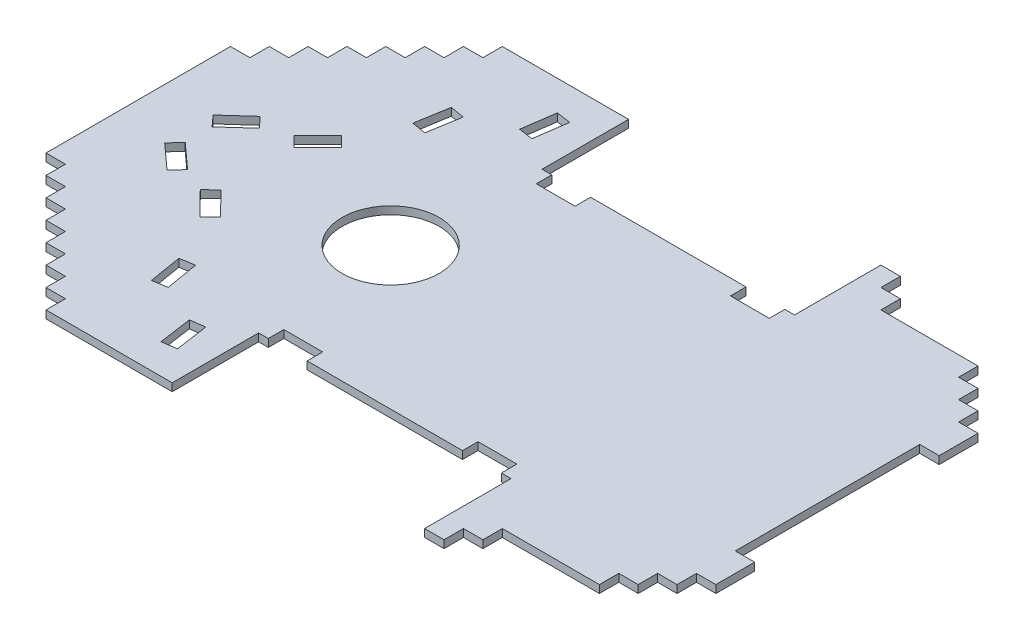
SolidWorks part; units mm, degrees
ref_plane "정면" through (0, 0, 0) normal (0, 0, 1) x (1, 0, 0)
ref_plane "윗면" through (0, 0, 0) normal (0, 1, 0) x (1, 0, 0)
ref_plane "우측면" through (0, 0, 0) normal (1, 0, 0) x (0, 0, -1)
sketch "스케치2" plane through (0, 0, 0) normal (0, 1, 0) x (1, 0, 0)
  line L0 (-96, -96) -> (96, 96) construction
  line L5 (-96, 96) -> (96, 96)
  line L39 (-96, 96) -> (-96, -96)
  line L40 (-96, -96) -> (96, -96)
  line L41 (96, 96) -> (96, -96)
  line L42 (-84, 84) -> (84, 84)
  line L43 (-84, 84) -> (-84, -84)
  line L44 (-84, -84) -> (84, -84)
  line L45 (84, 84) -> (84, -84)
  line L46 (-264, 84) -> (-264, -84)
  line L47 (-264, 84) -> (-96, 84)
  line L48 (-96, 84) -> (-96, -84)
  line L49 (-264, -84) -> (-96, -84)
  line L50 (-276, 96) -> (-276, -96)
  line L51 (-276, 96) -> (-84, 96)
  line L52 (-84, 96) -> (-84, -96)
  line L53 (-276, -96) -> (-84, -96)
  line L54 (-444, 84) -> (-444, -84)
  line L55 (-444, 84) -> (-276, 84)
  line L56 (-276, 84) -> (-276, -84)
  line L57 (-444, -84) -> (-276, -84)
  line L58 (-456, 96) -> (-456, -96)
  line L59 (-456, 96) -> (-264, 96)
  line L60 (-264, 96) -> (-264, -96)
  line L61 (-456, -96) -> (-264, -96)
  line L62 (-624, 84) -> (-624, -84)
  line L63 (-624, 84) -> (-456, 84)
  line L64 (-456, 84) -> (-456, -84)
  line L65 (-624, -84) -> (-456, -84)
  line L66 (-636, 96) -> (-636, -96)
  line L67 (-636, 96) -> (-444, 96)
  line L68 (-444, 96) -> (-444, -96)
  line L69 (-636, -96) -> (-444, -96)
  line L70 (-804, 84) -> (-804, -84)
  line L71 (-804, 84) -> (-636, 84)
  line L72 (-636, 84) -> (-636, -84)
  line L73 (-804, -84) -> (-636, -84)
  line L74 (-816, 96) -> (-816, -96)
  line L75 (-816, 96) -> (-624, 96)
  line L76 (-624, 96) -> (-624, -96)
  line L77 (-816, -96) -> (-624, -96)
  line L78 (-984, 84) -> (-984, -84)
  line L79 (-984, 84) -> (-816, 84)
  line L80 (-816, 84) -> (-816, -84)
  line L81 (-984, -84) -> (-816, -84)
  line L82 (-996, 96) -> (-996, -96)
  line L83 (-996, 96) -> (-804, 96)
  line L84 (-804, 96) -> (-804, -96)
  line L85 (-996, -96) -> (-804, -96)
  line L86 (-1164, 84) -> (-1164, -84)
  line L87 (-1164, 84) -> (-996, 84)
  line L88 (-996, 84) -> (-996, -84)
  line L89 (-1164, -84) -> (-996, -84)
  line L90 (-1176, 96) -> (-1176, -96)
  line L91 (-1176, 96) -> (-984, 96)
  line L92 (-984, 96) -> (-984, -96)
  line L93 (-1176, -96) -> (-984, -96)
  line L94 (-1344, 84) -> (-1344, -84)
  line L95 (-1344, 84) -> (-1176, 84)
  line L96 (-1176, 84) -> (-1176, -84)
  line L97 (-1344, -84) -> (-1176, -84)
  line L98 (-1356, 96) -> (-1356, -96)
  line L99 (-1356, 96) -> (-1164, 96)
  line L100 (-1164, 96) -> (-1164, -96)
  line L101 (-1356, -96) -> (-1164, -96)
  line L102 (-1524, 84) -> (-1524, -84)
  line L103 (-1524, 84) -> (-1356, 84)
  line L104 (-1356, 84) -> (-1356, -84)
  line L105 (-1524, -84) -> (-1356, -84)
  line L106 (-1536, 96) -> (-1536, -96)
  line L107 (-1536, 96) -> (-1344, 96)
  line L108 (-1344, 96) -> (-1344, -96)
  line L109 (-1536, -96) -> (-1344, -96)
  line L110 (-1704, 84) -> (-1704, -84)
  line L111 (-1704, 84) -> (-1536, 84)
  line L112 (-1536, 84) -> (-1536, -84)
  line L113 (-1704, -84) -> (-1536, -84)
  line L114 (-1716, 96) -> (-1716, -96)
  line L115 (-1716, 96) -> (-1524, 96)
  line L116 (-1524, 96) -> (-1524, -96)
  line L117 (-1716, -96) -> (-1524, -96)
  line L118 (-1884, 84) -> (-1884, -84)
  line L119 (-1884, 84) -> (-1716, 84)
  line L120 (-1716, 84) -> (-1716, -84)
  line L121 (-1884, -84) -> (-1716, -84)
  line L122 (-1896, 96) -> (-1896, -96)
  line L123 (-1896, 96) -> (-1704, 96)
  line L124 (-1704, 96) -> (-1704, -96)
  line L125 (-1896, -96) -> (-1704, -96)
  line L126 (-2064, 84) -> (-2064, -84)
  line L127 (-2064, 84) -> (-1896, 84)
  line L128 (-1896, 84) -> (-1896, -84)
  line L129 (-2064, -84) -> (-1896, -84)
  line L130 (-2076, 96) -> (-2076, -96)
  line L131 (-2076, 96) -> (-1884, 96)
  line L132 (-1884, 96) -> (-1884, -96)
  line L133 (-2076, -96) -> (-1884, -96)
  line L134 (-2244, 84) -> (-2244, -84)
  line L135 (-2244, 84) -> (-2076, 84)
  line L136 (-2076, 84) -> (-2076, -84)
  line L137 (-2244, -84) -> (-2076, -84)
  line L138 (-2256, 96) -> (-2256, -96)
  line L139 (-2256, 96) -> (-2064, 96)
  line L140 (-2064, 96) -> (-2064, -96)
  line L141 (-2256, -96) -> (-2064, -96)
  line L142 (-2424, 84) -> (-2424, -84)
  line L143 (-2424, 84) -> (-2256, 84)
  line L144 (-2256, 84) -> (-2256, -84)
  line L145 (-2424, -84) -> (-2256, -84)
  line L146 (-2436, 96) -> (-2436, -96)
  line L147 (-2436, 96) -> (-2244, 96)
  line L148 (-2244, 96) -> (-2244, -96)
  line L149 (-2436, -96) -> (-2244, -96)
  line L150 (-2604, 84) -> (-2604, -84)
  line L151 (-2604, 84) -> (-2436, 84)
  line L152 (-2436, 84) -> (-2436, -84)
  line L153 (-2604, -84) -> (-2436, -84)
  line L154 (-2616, 96) -> (-2616, -96)
  line L155 (-2616, 96) -> (-2424, 96)
  line L156 (-2424, 96) -> (-2424, -96)
  line L157 (-2616, -96) -> (-2424, -96)
  line L158 (-2784, 84) -> (-2784, -84)
  line L159 (-2784, 84) -> (-2616, 84)
  line L160 (-2616, 84) -> (-2616, -84)
  line L161 (-2784, -84) -> (-2616, -84)
  line L162 (-2796, 96) -> (-2796, -96)
  line L163 (-2796, 96) -> (-2604, 96)
  line L164 (-2604, 96) -> (-2604, -96)
  line L165 (-2796, -96) -> (-2604, -96)
  line L166 (-264, 264) -> (-264, 96)
  line L167 (-264, 264) -> (-96, 264)
  line L168 (-96, 264) -> (-96, 96)
  line L169 (-264, 96) -> (-96, 96)
  line L170 (-276, 276) -> (-276, 84)
  line L171 (-276, 276) -> (-84, 276)
  line L172 (-84, 276) -> (-84, 84)
  line L173 (-276, 84) -> (-84, 84)
  line L174 (-444, 264) -> (-444, 96)
  line L175 (-444, 264) -> (-276, 264)
  line L176 (-276, 264) -> (-276, 96)
  line L177 (-444, 96) -> (-276, 96)
  line L178 (-456, 276) -> (-456, 84)
  line L179 (-456, 276) -> (-264, 276)
  line L180 (-264, 276) -> (-264, 84)
  line L181 (-456, 84) -> (-264, 84)
  line L182 (-624, 264) -> (-624, 96)
  line L183 (-624, 264) -> (-456, 264)
  line L184 (-456, 264) -> (-456, 96)
  line L185 (-624, 96) -> (-456, 96)
  line L186 (-636, 276) -> (-636, 84)
  line L187 (-636, 276) -> (-444, 276)
  line L188 (-444, 276) -> (-444, 84)
  line L189 (-636, 84) -> (-444, 84)
  line L190 (-804, 264) -> (-804, 96)
  line L191 (-804, 264) -> (-636, 264)
  line L192 (-636, 264) -> (-636, 96)
  line L193 (-804, 96) -> (-636, 96)
  line L194 (-816, 276) -> (-816, 84)
  line L195 (-816, 276) -> (-624, 276)
  line L196 (-624, 276) -> (-624, 84)
  line L197 (-816, 84) -> (-624, 84)
  line L198 (-984, 264) -> (-984, 96)
  line L199 (-984, 264) -> (-816, 264)
  line L200 (-816, 264) -> (-816, 96)
  line L201 (-984, 96) -> (-816, 96)
  line L202 (-996, 276) -> (-996, 84)
  line L203 (-996, 276) -> (-804, 276)
  line L204 (-804, 276) -> (-804, 84)
  line L205 (-996, 84) -> (-804, 84)
  line L206 (-1164, 264) -> (-1164, 96)
  line L207 (-1164, 264) -> (-996, 264)
  line L208 (-996, 264) -> (-996, 96)
  line L209 (-1164, 96) -> (-996, 96)
  line L210 (-1176, 276) -> (-1176, 84)
  line L211 (-1176, 276) -> (-984, 276)
  line L212 (-984, 276) -> (-984, 84)
  line L213 (-1176, 84) -> (-984, 84)
  line L214 (-1344, 264) -> (-1344, 96)
  line L215 (-1344, 264) -> (-1176, 264)
  line L216 (-1176, 264) -> (-1176, 96)
  line L217 (-1344, 96) -> (-1176, 96)
  line L218 (-1356, 276) -> (-1356, 84)
  line L219 (-1356, 276) -> (-1164, 276)
  line L220 (-1164, 276) -> (-1164, 84)
  line L221 (-1356, 84) -> (-1164, 84)
  line L222 (-1524, 264) -> (-1524, 96)
  line L223 (-1524, 264) -> (-1356, 264)
  line L224 (-1356, 264) -> (-1356, 96)
  line L225 (-1524, 96) -> (-1356, 96)
  line L226 (-1536, 276) -> (-1536, 84)
  line L227 (-1536, 276) -> (-1344, 276)
  line L228 (-1344, 276) -> (-1344, 84)
  line L229 (-1536, 84) -> (-1344, 84)
  line L230 (-1704, 264) -> (-1704, 96)
  line L231 (-1704, 264) -> (-1536, 264)
  line L232 (-1536, 264) -> (-1536, 96)
  line L233 (-1704, 96) -> (-1536, 96)
  line L234 (-1716, 276) -> (-1716, 84)
  line L235 (-1716, 276) -> (-1524, 276)
  line L236 (-1524, 276) -> (-1524, 84)
  line L237 (-1716, 84) -> (-1524, 84)
  line L238 (-1884, 264) -> (-1884, 96)
  line L239 (-1884, 264) -> (-1716, 264)
  line L240 (-1716, 264) -> (-1716, 96)
  line L241 (-1884, 96) -> (-1716, 96)
  line L242 (-1896, 276) -> (-1896, 84)
  line L243 (-1896, 276) -> (-1704, 276)
  line L244 (-1704, 276) -> (-1704, 84)
  line L245 (-1896, 84) -> (-1704, 84)
  line L246 (-2064, 264) -> (-2064, 96)
  line L247 (-2064, 264) -> (-1896, 264)
  line L248 (-1896, 264) -> (-1896, 96)
  line L249 (-2064, 96) -> (-1896, 96)
  line L250 (-2076, 276) -> (-2076, 84)
  line L251 (-2076, 276) -> (-1884, 276)
  line L252 (-1884, 276) -> (-1884, 84)
  line L253 (-2076, 84) -> (-1884, 84)
  line L254 (-2244, 264) -> (-2244, 96)
  line L255 (-2244, 264) -> (-2076, 264)
  line L256 (-2076, 264) -> (-2076, 96)
  line L257 (-2244, 96) -> (-2076, 96)
  line L258 (-2256, 276) -> (-2256, 84)
  line L259 (-2256, 276) -> (-2064, 276)
  line L260 (-2064, 276) -> (-2064, 84)
  line L261 (-2256, 84) -> (-2064, 84)
  line L262 (-2424, 264) -> (-2424, 96)
  line L263 (-2424, 264) -> (-2256, 264)
  line L264 (-2256, 264) -> (-2256, 96)
  line L265 (-2424, 96) -> (-2256, 96)
  line L266 (-2436, 276) -> (-2436, 84)
  line L267 (-2436, 276) -> (-2244, 276)
  line L268 (-2244, 276) -> (-2244, 84)
  line L269 (-2436, 84) -> (-2244, 84)
  line L270 (-2604, 264) -> (-2604, 96)
  line L271 (-2604, 264) -> (-2436, 264)
  line L272 (-2436, 264) -> (-2436, 96)
  line L273 (-2604, 96) -> (-2436, 96)
  line L274 (-2616, 276) -> (-2616, 84)
  line L275 (-2616, 276) -> (-2424, 276)
  line L276 (-2424, 276) -> (-2424, 84)
  line L277 (-2616, 84) -> (-2424, 84)
  line L278 (-2784, 264) -> (-2784, 96)
  line L279 (-2784, 264) -> (-2616, 264)
  line L280 (-2616, 264) -> (-2616, 96)
  line L281 (-2784, 96) -> (-2616, 96)
  line L282 (-2796, 276) -> (-2796, 84)
  line L283 (-2796, 276) -> (-2604, 276)
  line L284 (-2604, 276) -> (-2604, 84)
  line L285 (-2796, 84) -> (-2604, 84)
  line L286 (-264, 444) -> (-264, 276)
  line L287 (-264, 444) -> (-96, 444)
  line L288 (-96, 444) -> (-96, 276)
  line L289 (-264, 276) -> (-96, 276)
  line L290 (-276, 456) -> (-276, 264)
  line L291 (-276, 456) -> (-84, 456)
  line L292 (-84, 456) -> (-84, 264)
  line L293 (-276, 264) -> (-84, 264)
  line L294 (-444, 444) -> (-444, 276)
  line L295 (-444, 444) -> (-276, 444)
  line L296 (-276, 444) -> (-276, 276)
  line L297 (-444, 276) -> (-276, 276)
  line L298 (-456, 456) -> (-456, 264)
  line L299 (-456, 456) -> (-264, 456)
  line L300 (-264, 456) -> (-264, 264)
  line L301 (-456, 264) -> (-264, 264)
  line L302 (-624, 444) -> (-624, 276)
  line L303 (-624, 444) -> (-456, 444)
  line L304 (-456, 444) -> (-456, 276)
  line L305 (-624, 276) -> (-456, 276)
  line L306 (-636, 456) -> (-636, 264)
  line L307 (-636, 456) -> (-444, 456)
  line L308 (-444, 456) -> (-444, 264)
  line L309 (-636, 264) -> (-444, 264)
  line L310 (-804, 444) -> (-804, 276)
  line L311 (-804, 444) -> (-636, 444)
  line L312 (-636, 444) -> (-636, 276)
  line L313 (-804, 276) -> (-636, 276)
  line L314 (-816, 456) -> (-816, 264)
  line L315 (-816, 456) -> (-624, 456)
  line L316 (-624, 456) -> (-624, 264)
  line L317 (-816, 264) -> (-624, 264)
  line L318 (-984, 444) -> (-984, 276)
  line L319 (-984, 444) -> (-816, 444)
  line L320 (-816, 444) -> (-816, 276)
  line L321 (-984, 276) -> (-816, 276)
  line L322 (-996, 456) -> (-996, 264)
  line L323 (-996, 456) -> (-804, 456)
  line L324 (-804, 456) -> (-804, 264)
  line L325 (-996, 264) -> (-804, 264)
  line L326 (-1164, 444) -> (-1164, 276)
  line L327 (-1164, 444) -> (-996, 444)
  line L328 (-996, 444) -> (-996, 276)
  line L329 (-1164, 276) -> (-996, 276)
  line L330 (-1176, 456) -> (-1176, 264)
  line L331 (-1176, 456) -> (-984, 456)
  line L332 (-984, 456) -> (-984, 264)
  line L333 (-1176, 264) -> (-984, 264)
  line L334 (-1344, 444) -> (-1344, 276)
  line L335 (-1344, 444) -> (-1176, 444)
  line L336 (-1176, 444) -> (-1176, 276)
  line L337 (-1344, 276) -> (-1176, 276)
  line L338 (-1356, 456) -> (-1356, 264)
  line L339 (-1356, 456) -> (-1164, 456)
  line L340 (-1164, 456) -> (-1164, 264)
  line L341 (-1356, 264) -> (-1164, 264)
  line L342 (-1524, 444) -> (-1524, 276)
  line L343 (-1524, 444) -> (-1356, 444)
  line L344 (-1356, 444) -> (-1356, 276)
  line L345 (-1524, 276) -> (-1356, 276)
  line L346 (-1536, 456) -> (-1536, 264)
  line L347 (-1536, 456) -> (-1344, 456)
  line L348 (-1344, 456) -> (-1344, 264)
  line L349 (-1536, 264) -> (-1344, 264)
  line L350 (-1704, 444) -> (-1704, 276)
  line L351 (-1704, 444) -> (-1536, 444)
  line L352 (-1536, 444) -> (-1536, 276)
  line L353 (-1704, 276) -> (-1536, 276)
  line L354 (-1716, 456) -> (-1716, 264)
  line L355 (-1716, 456) -> (-1524, 456)
  line L356 (-1524, 456) -> (-1524, 264)
  line L357 (-1716, 264) -> (-1524, 264)
  line L358 (-1884, 444) -> (-1884, 276)
  line L359 (-1884, 444) -> (-1716, 444)
  line L360 (-1716, 444) -> (-1716, 276)
  line L361 (-1884, 276) -> (-1716, 276)
  line L362 (-1896, 456) -> (-1896, 264)
  line L363 (-1896, 456) -> (-1704, 456)
  line L364 (-1704, 456) -> (-1704, 264)
  line L365 (-1896, 264) -> (-1704, 264)
  line L366 (-2064, 444) -> (-2064, 276)
  line L367 (-2064, 444) -> (-1896, 444)
  line L368 (-1896, 444) -> (-1896, 276)
  line L369 (-2064, 276) -> (-1896, 276)
  line L370 (-2076, 456) -> (-2076, 264)
  line L371 (-2076, 456) -> (-1884, 456)
  line L372 (-1884, 456) -> (-1884, 264)
  line L373 (-2076, 264) -> (-1884, 264)
  line L374 (-2244, 444) -> (-2244, 276)
  line L375 (-2244, 444) -> (-2076, 444)
  line L376 (-2076, 444) -> (-2076, 276)
  line L377 (-2244, 276) -> (-2076, 276)
  line L378 (-2256, 456) -> (-2256, 264)
  line L379 (-2256, 456) -> (-2064, 456)
  line L380 (-2064, 456) -> (-2064, 264)
  line L381 (-2256, 264) -> (-2064, 264)
  line L382 (-2424, 444) -> (-2424, 276)
  line L383 (-2424, 444) -> (-2256, 444)
  line L384 (-2256, 444) -> (-2256, 276)
  line L385 (-2424, 276) -> (-2256, 276)
  line L386 (-2436, 456) -> (-2436, 264)
  line L387 (-2436, 456) -> (-2244, 456)
  line L388 (-2244, 456) -> (-2244, 264)
  line L389 (-2436, 264) -> (-2244, 264)
  line L390 (-2604, 444) -> (-2604, 276)
  line L391 (-2604, 444) -> (-2436, 444)
  line L392 (-2436, 444) -> (-2436, 276)
  line L393 (-2604, 276) -> (-2436, 276)
  line L394 (-2616, 456) -> (-2616, 264)
  line L395 (-2616, 456) -> (-2424, 456)
  line L396 (-2424, 456) -> (-2424, 264)
  line L397 (-2616, 264) -> (-2424, 264)
  line L398 (-2784, 444) -> (-2784, 276)
  line L399 (-2784, 444) -> (-2616, 444)
  line L400 (-2616, 444) -> (-2616, 276)
  line L401 (-2784, 276) -> (-2616, 276)
  line L402 (-2796, 456) -> (-2796, 264)
  line L403 (-2796, 456) -> (-2604, 456)
  line L404 (-2604, 456) -> (-2604, 264)
  line L405 (-2796, 264) -> (-2604, 264)
  line L406 (-264, 624) -> (-264, 456)
  line L407 (-264, 624) -> (-96, 624)
  line L408 (-96, 624) -> (-96, 456)
  line L409 (-264, 456) -> (-96, 456)
  line L410 (-276, 636) -> (-276, 444)
  line L411 (-276, 636) -> (-84, 636)
  line L412 (-84, 636) -> (-84, 444)
  line L413 (-276, 444) -> (-84, 444)
  line L414 (-444, 624) -> (-444, 456)
  line L415 (-444, 624) -> (-276, 624)
  line L416 (-276, 624) -> (-276, 456)
  line L417 (-444, 456) -> (-276, 456)
  line L418 (-456, 636) -> (-456, 444)
  line L419 (-456, 636) -> (-264, 636)
  line L420 (-264, 636) -> (-264, 444)
  line L421 (-456, 444) -> (-264, 444)
  line L422 (-624, 624) -> (-624, 456)
  line L423 (-624, 624) -> (-456, 624)
  line L424 (-456, 624) -> (-456, 456)
  line L425 (-624, 456) -> (-456, 456)
  line L426 (-636, 636) -> (-636, 444)
  line L427 (-636, 636) -> (-444, 636)
  line L428 (-444, 636) -> (-444, 444)
  line L429 (-636, 444) -> (-444, 444)
  line L430 (-804, 624) -> (-804, 456)
  line L431 (-804, 624) -> (-636, 624)
  line L432 (-636, 624) -> (-636, 456)
  line L433 (-804, 456) -> (-636, 456)
  line L434 (-816, 636) -> (-816, 444)
  line L435 (-816, 636) -> (-624, 636)
  line L436 (-624, 636) -> (-624, 444)
  line L437 (-816, 444) -> (-624, 444)
  line L438 (-984, 624) -> (-984, 456)
  line L439 (-984, 624) -> (-816, 624)
  line L440 (-816, 624) -> (-816, 456)
  line L441 (-984, 456) -> (-816, 456)
  line L442 (-996, 636) -> (-996, 444)
  line L443 (-996, 636) -> (-804, 636)
  line L444 (-804, 636) -> (-804, 444)
  line L445 (-996, 444) -> (-804, 444)
  line L446 (-1164, 624) -> (-1164, 456)
  line L447 (-1164, 624) -> (-996, 624)
  line L448 (-996, 624) -> (-996, 456)
  line L449 (-1164, 456) -> (-996, 456)
  line L450 (-1176, 636) -> (-1176, 444)
  line L451 (-1176, 636) -> (-984, 636)
  line L452 (-984, 636) -> (-984, 444)
  line L453 (-1176, 444) -> (-984, 444)
  line L454 (-1344, 624) -> (-1344, 456)
  line L455 (-1344, 624) -> (-1176, 624)
  line L456 (-1176, 624) -> (-1176, 456)
  line L457 (-1344, 456) -> (-1176, 456)
  line L458 (-1356, 636) -> (-1356, 444)
  line L459 (-1356, 636) -> (-1164, 636)
  line L460 (-1164, 636) -> (-1164, 444)
  line L461 (-1356, 444) -> (-1164, 444)
  line L462 (-1524, 624) -> (-1524, 456)
  line L463 (-1524, 624) -> (-1356, 624)
  line L464 (-1356, 624) -> (-1356, 456)
  line L465 (-1524, 456) -> (-1356, 456)
  line L466 (-1536, 636) -> (-1536, 444)
  line L467 (-1536, 636) -> (-1344, 636)
  line L468 (-1344, 636) -> (-1344, 444)
  line L469 (-1536, 444) -> (-1344, 444)
  line L470 (-1704, 624) -> (-1704, 456)
  line L471 (-1704, 624) -> (-1536, 624)
  line L472 (-1536, 624) -> (-1536, 456)
  line L473 (-1704, 456) -> (-1536, 456)
  line L474 (-1716, 636) -> (-1716, 444)
  line L475 (-1716, 636) -> (-1524, 636)
  line L476 (-1524, 636) -> (-1524, 444)
  line L477 (-1716, 444) -> (-1524, 444)
  line L478 (-1884, 624) -> (-1884, 456)
  line L479 (-1884, 624) -> (-1716, 624)
  line L480 (-1716, 624) -> (-1716, 456)
  line L481 (-1884, 456) -> (-1716, 456)
  line L482 (-1896, 636) -> (-1896, 444)
  line L483 (-1896, 636) -> (-1704, 636)
  line L484 (-1704, 636) -> (-1704, 444)
  line L485 (-1896, 444) -> (-1704, 444)
  line L486 (-2064, 624) -> (-2064, 456)
  line L487 (-2064, 624) -> (-1896, 624)
  line L488 (-1896, 624) -> (-1896, 456)
  line L489 (-2064, 456) -> (-1896, 456)
  line L490 (-2076, 636) -> (-2076, 444)
  line L491 (-2076, 636) -> (-1884, 636)
  line L492 (-1884, 636) -> (-1884, 444)
  line L493 (-2076, 444) -> (-1884, 444)
  line L494 (-2244, 624) -> (-2244, 456)
  line L495 (-2244, 624) -> (-2076, 624)
  line L496 (-2076, 624) -> (-2076, 456)
  line L497 (-2244, 456) -> (-2076, 456)
  line L498 (-2256, 636) -> (-2256, 444)
  line L499 (-2256, 636) -> (-2064, 636)
  line L500 (-2064, 636) -> (-2064, 444)
  line L501 (-2256, 444) -> (-2064, 444)
  line L502 (-2424, 624) -> (-2424, 456)
  line L503 (-2424, 624) -> (-2256, 624)
  line L504 (-2256, 624) -> (-2256, 456)
  line L505 (-2424, 456) -> (-2256, 456)
  line L506 (-2436, 636) -> (-2436, 444)
  line L507 (-2436, 636) -> (-2244, 636)
  line L508 (-2244, 636) -> (-2244, 444)
  line L509 (-2436, 444) -> (-2244, 444)
  line L510 (-2604, 624) -> (-2604, 456)
  line L511 (-2604, 624) -> (-2436, 624)
  line L512 (-2436, 624) -> (-2436, 456)
  line L513 (-2604, 456) -> (-2436, 456)
  line L514 (-2616, 636) -> (-2616, 444)
  line L515 (-2616, 636) -> (-2424, 636)
  line L516 (-2424, 636) -> (-2424, 444)
  line L517 (-2616, 444) -> (-2424, 444)
  line L518 (-2784, 624) -> (-2784, 456)
  line L519 (-2784, 624) -> (-2616, 624)
  line L520 (-2616, 624) -> (-2616, 456)
  line L521 (-2784, 456) -> (-2616, 456)
  line L522 (-2796, 636) -> (-2796, 444)
  line L523 (-2796, 636) -> (-2604, 636)
  line L524 (-2604, 636) -> (-2604, 444)
  line L525 (-2796, 444) -> (-2604, 444)
  line L526 (-264, 804) -> (-264, 636)
  line L527 (-264, 804) -> (-96, 804)
  line L528 (-96, 804) -> (-96, 636)
  line L529 (-264, 636) -> (-96, 636)
  line L530 (-276, 816) -> (-276, 624)
  line L531 (-276, 816) -> (-84, 816)
  line L532 (-84, 816) -> (-84, 624)
  line L533 (-276, 624) -> (-84, 624)
  line L534 (-444, 804) -> (-444, 636)
  line L535 (-444, 804) -> (-276, 804)
  line L536 (-276, 804) -> (-276, 636)
  line L537 (-444, 636) -> (-276, 636)
  line L538 (-456, 816) -> (-456, 624)
  line L539 (-456, 816) -> (-264, 816)
  line L540 (-264, 816) -> (-264, 624)
  line L541 (-456, 624) -> (-264, 624)
  line L542 (-624, 804) -> (-624, 636)
  line L543 (-624, 804) -> (-456, 804)
  line L544 (-456, 804) -> (-456, 636)
  line L545 (-624, 636) -> (-456, 636)
  line L546 (-636, 816) -> (-636, 624)
  line L547 (-636, 816) -> (-444, 816)
  line L548 (-444, 816) -> (-444, 624)
  line L549 (-636, 624) -> (-444, 624)
  line L550 (-804, 804) -> (-804, 636)
  line L551 (-804, 804) -> (-636, 804)
  line L552 (-636, 804) -> (-636, 636)
  line L553 (-804, 636) -> (-636, 636)
  line L554 (-816, 816) -> (-816, 624)
  line L555 (-816, 816) -> (-624, 816)
  line L556 (-624, 816) -> (-624, 624)
  line L557 (-816, 624) -> (-624, 624)
  line L558 (-984, 804) -> (-984, 636)
  line L559 (-984, 804) -> (-816, 804)
  line L560 (-816, 804) -> (-816, 636)
  line L561 (-984, 636) -> (-816, 636)
  line L562 (-996, 816) -> (-996, 624)
  line L563 (-996, 816) -> (-804, 816)
  line L564 (-804, 816) -> (-804, 624)
  line L565 (-996, 624) -> (-804, 624)
  line L566 (-1164, 804) -> (-1164, 636)
  line L567 (-1164, 804) -> (-996, 804)
  line L568 (-996, 804) -> (-996, 636)
  line L569 (-1164, 636) -> (-996, 636)
  line L570 (-1176, 816) -> (-1176, 624)
  line L571 (-1176, 816) -> (-984, 816)
  line L572 (-984, 816) -> (-984, 624)
  line L573 (-1176, 624) -> (-984, 624)
  line L574 (-1344, 804) -> (-1344, 636)
  line L575 (-1344, 804) -> (-1176, 804)
  line L576 (-1176, 804) -> (-1176, 636)
  line L577 (-1344, 636) -> (-1176, 636)
  line L578 (-1356, 816) -> (-1356, 624)
  line L579 (-1356, 816) -> (-1164, 816)
  line L580 (-1164, 816) -> (-1164, 624)
  line L581 (-1356, 624) -> (-1164, 624)
  line L582 (-1524, 804) -> (-1524, 636)
  line L583 (-1524, 804) -> (-1356, 804)
  line L584 (-1356, 804) -> (-1356, 636)
  line L585 (-1524, 636) -> (-1356, 636)
  line L586 (-1536, 816) -> (-1536, 624)
  line L587 (-1536, 816) -> (-1344, 816)
  line L588 (-1344, 816) -> (-1344, 624)
  line L589 (-1536, 624) -> (-1344, 624)
  line L590 (-1704, 804) -> (-1704, 636)
  line L591 (-1704, 804) -> (-1536, 804)
  line L592 (-1536, 804) -> (-1536, 636)
  line L593 (-1704, 636) -> (-1536, 636)
  line L594 (-1716, 816) -> (-1716, 624)
  line L595 (-1716, 816) -> (-1524, 816)
  line L596 (-1524, 816) -> (-1524, 624)
  line L597 (-1716, 624) -> (-1524, 624)
  line L598 (-1884, 804) -> (-1884, 636)
  line L599 (-1884, 804) -> (-1716, 804)
  line L600 (-1716, 804) -> (-1716, 636)
  line L601 (-1884, 636) -> (-1716, 636)
  line L602 (-1896, 816) -> (-1896, 624)
  line L603 (-1896, 816) -> (-1704, 816)
  line L604 (-1704, 816) -> (-1704, 624)
  line L605 (-1896, 624) -> (-1704, 624)
  line L606 (-2064, 804) -> (-2064, 636)
  line L607 (-2064, 804) -> (-1896, 804)
  line L608 (-1896, 804) -> (-1896, 636)
  line L609 (-2064, 636) -> (-1896, 636)
  line L610 (-2076, 816) -> (-2076, 624)
  line L611 (-2076, 816) -> (-1884, 816)
  line L612 (-1884, 816) -> (-1884, 624)
  line L613 (-2076, 624) -> (-1884, 624)
  line L614 (-2244, 804) -> (-2244, 636)
  line L615 (-2244, 804) -> (-2076, 804)
  line L616 (-2076, 804) -> (-2076, 636)
  line L617 (-2244, 636) -> (-2076, 636)
  line L618 (-2256, 816) -> (-2256, 624)
  line L619 (-2256, 816) -> (-2064, 816)
  line L620 (-2064, 816) -> (-2064, 624)
  line L621 (-2256, 624) -> (-2064, 624)
  line L622 (-2424, 804) -> (-2424, 636)
  line L623 (-2424, 804) -> (-2256, 804)
  line L624 (-2256, 804) -> (-2256, 636)
  line L625 (-2424, 636) -> (-2256, 636)
  line L626 (-2436, 816) -> (-2436, 624)
  line L627 (-2436, 816) -> (-2244, 816)
  line L628 (-2244, 816) -> (-2244, 624)
  line L629 (-2436, 624) -> (-2244, 624)
  line L630 (-2604, 804) -> (-2604, 636)
  line L631 (-2604, 804) -> (-2436, 804)
  line L632 (-2436, 804) -> (-2436, 636)
  line L633 (-2604, 636) -> (-2436, 636)
  line L634 (-2616, 816) -> (-2616, 624)
  line L635 (-2616, 816) -> (-2424, 816)
  line L636 (-2424, 816) -> (-2424, 624)
  line L637 (-2616, 624) -> (-2424, 624)
  line L638 (-2784, 804) -> (-2784, 636)
  line L639 (-2784, 804) -> (-2616, 804)
  line L640 (-2616, 804) -> (-2616, 636)
  line L641 (-2784, 636) -> (-2616, 636)
  line L642 (-2796, 816) -> (-2796, 624)
  line L643 (-2796, 816) -> (-2604, 816)
  line L644 (-2604, 816) -> (-2604, 624)
  line L645 (-2796, 624) -> (-2604, 624)
  line L646 (-264, 984) -> (-264, 816)
  line L647 (-264, 984) -> (-96, 984)
  line L648 (-96, 984) -> (-96, 816)
  line L649 (-264, 816) -> (-96, 816)
  line L650 (-276, 996) -> (-276, 804)
  line L651 (-276, 996) -> (-84, 996)
  line L652 (-84, 996) -> (-84, 804)
  line L653 (-276, 804) -> (-84, 804)
  line L654 (-444, 984) -> (-444, 816)
  line L655 (-444, 984) -> (-276, 984)
  line L656 (-276, 984) -> (-276, 816)
  line L657 (-444, 816) -> (-276, 816)
  line L658 (-456, 996) -> (-456, 804)
  line L659 (-456, 996) -> (-264, 996)
  line L660 (-264, 996) -> (-264, 804)
  line L661 (-456, 804) -> (-264, 804)
  line L662 (-624, 984) -> (-624, 816)
  line L663 (-624, 984) -> (-456, 984)
  line L664 (-456, 984) -> (-456, 816)
  line L665 (-624, 816) -> (-456, 816)
  line L666 (-636, 996) -> (-636, 804)
  line L667 (-636, 996) -> (-444, 996)
  line L668 (-444, 996) -> (-444, 804)
  line L669 (-636, 804) -> (-444, 804)
  line L670 (-804, 984) -> (-804, 816)
  line L671 (-804, 984) -> (-636, 984)
  line L672 (-636, 984) -> (-636, 816)
  line L673 (-804, 816) -> (-636, 816)
  line L674 (-816, 996) -> (-816, 804)
  line L675 (-816, 996) -> (-624, 996)
  line L676 (-624, 996) -> (-624, 804)
  line L677 (-816, 804) -> (-624, 804)
  line L678 (-984, 984) -> (-984, 816)
  line L679 (-984, 984) -> (-816, 984)
  line L680 (-816, 984) -> (-816, 816)
  line L681 (-984, 816) -> (-816, 816)
  line L682 (-996, 996) -> (-996, 804)
  line L683 (-996, 996) -> (-804, 996)
  line L684 (-804, 996) -> (-804, 804)
  line L685 (-996, 804) -> (-804, 804)
  line L686 (-1164, 984) -> (-1164, 816)
  line L687 (-1164, 984) -> (-996, 984)
  line L688 (-996, 984) -> (-996, 816)
  line L689 (-1164, 816) -> (-996, 816)
  line L690 (-1176, 996) -> (-1176, 804)
  line L691 (-1176, 996) -> (-984, 996)
  line L692 (-984, 996) -> (-984, 804)
  line L693 (-1176, 804) -> (-984, 804)
  line L694 (-1344, 984) -> (-1344, 816)
  line L695 (-1344, 984) -> (-1176, 984)
  line L696 (-1176, 984) -> (-1176, 816)
  line L697 (-1344, 816) -> (-1176, 816)
  line L698 (-1356, 996) -> (-1356, 804)
  line L699 (-1356, 996) -> (-1164, 996)
  line L700 (-1164, 996) -> (-1164, 804)
  line L701 (-1356, 804) -> (-1164, 804)
  line L702 (-1524, 984) -> (-1524, 816)
  line L703 (-1524, 984) -> (-1356, 984)
  line L704 (-1356, 984) -> (-1356, 816)
  line L705 (-1524, 816) -> (-1356, 816)
  line L706 (-1536, 996) -> (-1536, 804)
  line L707 (-1536, 996) -> (-1344, 996)
  line L708 (-1344, 996) -> (-1344, 804)
  line L709 (-1536, 804) -> (-1344, 804)
  line L710 (-1704, 984) -> (-1704, 816)
  line L711 (-1704, 984) -> (-1536, 984)
  line L712 (-1536, 984) -> (-1536, 816)
  line L713 (-1704, 816) -> (-1536, 816)
  line L714 (-1716, 996) -> (-1716, 804)
  line L715 (-1716, 996) -> (-1524, 996)
  line L716 (-1524, 996) -> (-1524, 804)
  line L717 (-1716, 804) -> (-1524, 804)
  line L718 (-1884, 984) -> (-1884, 816)
  line L719 (-1884, 984) -> (-1716, 984)
  line L720 (-1716, 984) -> (-1716, 816)
  line L721 (-1884, 816) -> (-1716, 816)
  line L722 (-1896, 996) -> (-1896, 804)
  line L723 (-1896, 996) -> (-1704, 996)
  line L724 (-1704, 996) -> (-1704, 804)
  line L725 (-1896, 804) -> (-1704, 804)
  line L726 (-2064, 984) -> (-2064, 816)
  line L727 (-2064, 984) -> (-1896, 984)
  line L728 (-1896, 984) -> (-1896, 816)
  line L729 (-2064, 816) -> (-1896, 816)
  line L730 (-2076, 996) -> (-2076, 804)
  line L731 (-2076, 996) -> (-1884, 996)
  line L732 (-1884, 996) -> (-1884, 804)
  line L733 (-2076, 804) -> (-1884, 804)
  line L734 (-2244, 984) -> (-2244, 816)
  line L735 (-2244, 984) -> (-2076, 984)
  line L736 (-2076, 984) -> (-2076, 816)
  line L737 (-2244, 816) -> (-2076, 816)
  line L738 (-2256, 996) -> (-2256, 804)
  line L739 (-2256, 996) -> (-2064, 996)
  line L740 (-2064, 996) -> (-2064, 804)
  line L741 (-2256, 804) -> (-2064, 804)
  line L742 (-2424, 984) -> (-2424, 816)
  line L743 (-2424, 984) -> (-2256, 984)
  line L744 (-2256, 984) -> (-2256, 816)
  line L745 (-2424, 816) -> (-2256, 816)
  line L746 (-2436, 996) -> (-2436, 804)
  line L747 (-2436, 996) -> (-2244, 996)
  line L748 (-2244, 996) -> (-2244, 804)
  line L749 (-2436, 804) -> (-2244, 804)
  line L750 (-2604, 984) -> (-2604, 816)
  line L751 (-2604, 984) -> (-2436, 984)
  line L752 (-2436, 984) -> (-2436, 816)
  line L753 (-2604, 816) -> (-2436, 816)
  line L754 (-2616, 996) -> (-2616, 804)
  line L755 (-2616, 996) -> (-2424, 996)
  line L756 (-2424, 996) -> (-2424, 804)
  line L757 (-2616, 804) -> (-2424, 804)
  line L758 (-2784, 984) -> (-2784, 816)
  line L759 (-2784, 984) -> (-2616, 984)
  line L760 (-2616, 984) -> (-2616, 816)
  line L761 (-2784, 816) -> (-2616, 816)
  line L762 (-2796, 996) -> (-2796, 804)
  line L763 (-2796, 996) -> (-2604, 996)
  line L764 (-2604, 996) -> (-2604, 804)
  line L765 (-2796, 804) -> (-2604, 804)
  line L766 (-264, 1164) -> (-264, 996)
  line L767 (-264, 1164) -> (-96, 1164)
  line L768 (-96, 1164) -> (-96, 996)
  line L769 (-264, 996) -> (-96, 996)
  line L770 (-276, 1176) -> (-276, 984)
  line L771 (-276, 1176) -> (-84, 1176)
  line L772 (-84, 1176) -> (-84, 984)
  line L773 (-276, 984) -> (-84, 984)
  line L774 (-444, 1164) -> (-444, 996)
  line L775 (-444, 1164) -> (-276, 1164)
  line L776 (-276, 1164) -> (-276, 996)
  line L777 (-444, 996) -> (-276, 996)
  line L778 (-456, 1176) -> (-456, 984)
  line L779 (-456, 1176) -> (-264, 1176)
  line L780 (-264, 1176) -> (-264, 984)
  line L781 (-456, 984) -> (-264, 984)
  line L782 (-624, 1164) -> (-624, 996)
  line L783 (-624, 1164) -> (-456, 1164)
  line L784 (-456, 1164) -> (-456, 996)
  line L785 (-624, 996) -> (-456, 996)
  line L786 (-636, 1176) -> (-636, 984)
  line L787 (-636, 1176) -> (-444, 1176)
  line L788 (-444, 1176) -> (-444, 984)
  line L789 (-636, 984) -> (-444, 984)
  line L790 (-804, 1164) -> (-804, 996)
  line L791 (-804, 1164) -> (-636, 1164)
  line L792 (-636, 1164) -> (-636, 996)
  line L793 (-804, 996) -> (-636, 996)
  line L794 (-816, 1176) -> (-816, 984)
  line L795 (-816, 1176) -> (-624, 1176)
  line L796 (-624, 1176) -> (-624, 984)
  line L797 (-816, 984) -> (-624, 984)
  line L798 (-984, 1164) -> (-984, 996)
  line L799 (-984, 1164) -> (-816, 1164)
  line L800 (-816, 1164) -> (-816, 996)
  line L801 (-984, 996) -> (-816, 996)
  line L802 (-996, 1176) -> (-996, 984)
  line L803 (-996, 1176) -> (-804, 1176)
  line L804 (-804, 1176) -> (-804, 984)
  line L805 (-996, 984) -> (-804, 984)
  line L806 (-1164, 1164) -> (-1164, 996)
  line L807 (-1164, 1164) -> (-996, 1164)
  line L808 (-996, 1164) -> (-996, 996)
  line L809 (-1164, 996) -> (-996, 996)
  line L810 (-1176, 1176) -> (-1176, 984)
  line L811 (-1176, 1176) -> (-984, 1176)
  line L812 (-984, 1176) -> (-984, 984)
  line L813 (-1176, 984) -> (-984, 984)
  line L814 (-1344, 1164) -> (-1344, 996)
  line L815 (-1344, 1164) -> (-1176, 1164)
  line L816 (-1176, 1164) -> (-1176, 996)
  line L817 (-1344, 996) -> (-1176, 996)
  line L818 (-1356, 1176) -> (-1356, 984)
  line L819 (-1356, 1176) -> (-1164, 1176)
  line L820 (-1164, 1176) -> (-1164, 984)
  line L821 (-1356, 984) -> (-1164, 984)
  line L822 (-1524, 1164) -> (-1524, 996)
  line L823 (-1524, 1164) -> (-1356, 1164)
  line L824 (-1356, 1164) -> (-1356, 996)
  line L825 (-1524, 996) -> (-1356, 996)
  line L826 (-1536, 1176) -> (-1536, 984)
  line L827 (-1536, 1176) -> (-1344, 1176)
  line L828 (-1344, 1176) -> (-1344, 984)
  line L829 (-1536, 984) -> (-1344, 984)
  line L830 (-1704, 1164) -> (-1704, 996)
  line L831 (-1704, 1164) -> (-1536, 1164)
  line L832 (-1536, 1164) -> (-1536, 996)
  line L833 (-1704, 996) -> (-1536, 996)
  line L834 (-1716, 1176) -> (-1716, 984)
  line L835 (-1716, 1176) -> (-1524, 1176)
  line L836 (-1524, 1176) -> (-1524, 984)
  line L837 (-1716, 984) -> (-1524, 984)
  line L838 (-1884, 1164) -> (-1884, 996)
  line L839 (-1884, 1164) -> (-1716, 1164)
  line L840 (-1716, 1164) -> (-1716, 996)
  line L841 (-1884, 996) -> (-1716, 996)
  line L842 (-1896, 1176) -> (-1896, 984)
  line L843 (-1896, 1176) -> (-1704, 1176)
  line L844 (-1704, 1176) -> (-1704, 984)
  line L845 (-1896, 984) -> (-1704, 984)
  line L846 (-2064, 1164) -> (-2064, 996)
  line L847 (-2064, 1164) -> (-1896, 1164)
  line L848 (-1896, 1164) -> (-1896, 996)
  line L849 (-2064, 996) -> (-1896, 996)
  line L850 (-2076, 1176) -> (-2076, 984)
  line L851 (-2076, 1176) -> (-1884, 1176)
  line L852 (-1884, 1176) -> (-1884, 984)
  line L853 (-2076, 984) -> (-1884, 984)
  line L854 (-2244, 1164) -> (-2244, 996)
  line L855 (-2244, 1164) -> (-2076, 1164)
  line L856 (-2076, 1164) -> (-2076, 996)
  line L857 (-2244, 996) -> (-2076, 996)
  line L858 (-2256, 1176) -> (-2256, 984)
  line L859 (-2256, 1176) -> (-2064, 1176)
  line L860 (-2064, 1176) -> (-2064, 984)
  line L861 (-2256, 984) -> (-2064, 984)
  line L862 (-2424, 1164) -> (-2424, 996)
  line L863 (-2424, 1164) -> (-2256, 1164)
  line L864 (-2256, 1164) -> (-2256, 996)
  line L865 (-2424, 996) -> (-2256, 996)
  line L866 (-2436, 1176) -> (-2436, 984)
  line L867 (-2436, 1176) -> (-2244, 1176)
  line L868 (-2244, 1176) -> (-2244, 984)
  line L869 (-2436, 984) -> (-2244, 984)
  line L870 (-2604, 1164) -> (-2604, 996)
  line L871 (-2604, 1164) -> (-2436, 1164)
  line L872 (-2436, 1164) -> (-2436, 996)
  line L873 (-2604, 996) -> (-2436, 996)
  line L874 (-2616, 1176) -> (-2616, 984)
  line L875 (-2616, 1176) -> (-2424, 1176)
  line L876 (-2424, 1176) -> (-2424, 984)
  line L877 (-2616, 984) -> (-2424, 984)
  line L878 (-2784, 1164) -> (-2784, 996)
  line L879 (-2784, 1164) -> (-2616, 1164)
  line L880 (-2616, 1164) -> (-2616, 996)
  line L881 (-2784, 996) -> (-2616, 996)
  line L882 (-2796, 1176) -> (-2796, 984)
  line L883 (-2796, 1176) -> (-2604, 1176)
  line L884 (-2604, 1176) -> (-2604, 984)
  line L885 (-2796, 984) -> (-2604, 984)
  line L886 (-264, 1344) -> (-264, 1176)
  line L887 (-264, 1344) -> (-96, 1344)
  line L888 (-96, 1344) -> (-96, 1176)
  line L889 (-264, 1176) -> (-96, 1176)
  line L890 (-276, 1356) -> (-276, 1164)
  line L891 (-276, 1356) -> (-84, 1356)
  line L892 (-84, 1356) -> (-84, 1164)
  line L893 (-276, 1164) -> (-84, 1164)
  line L894 (-444, 1344) -> (-444, 1176)
  line L895 (-444, 1344) -> (-276, 1344)
  line L896 (-276, 1344) -> (-276, 1176)
  line L897 (-444, 1176) -> (-276, 1176)
  line L898 (-456, 1356) -> (-456, 1164)
  line L899 (-456, 1356) -> (-264, 1356)
  line L900 (-264, 1356) -> (-264, 1164)
  line L901 (-456, 1164) -> (-264, 1164)
  line L902 (-624, 1344) -> (-624, 1176)
  line L903 (-624, 1344) -> (-456, 1344)
  line L904 (-456, 1344) -> (-456, 1176)
  line L905 (-624, 1176) -> (-456, 1176)
  line L906 (-636, 1356) -> (-636, 1164)
  line L907 (-636, 1356) -> (-444, 1356)
  line L908 (-444, 1356) -> (-444, 1164)
  line L909 (-636, 1164) -> (-444, 1164)
  line L910 (-804, 1344) -> (-804, 1176)
  line L911 (-804, 1344) -> (-636, 1344)
  line L912 (-636, 1344) -> (-636, 1176)
  line L913 (-804, 1176) -> (-636, 1176)
  line L914 (-816, 1356) -> (-816, 1164)
  line L915 (-816, 1356) -> (-624, 1356)
  line L916 (-624, 1356) -> (-624, 1164)
  line L917 (-816, 1164) -> (-624, 1164)
  line L918 (-984, 1344) -> (-984, 1176)
  line L919 (-984, 1344) -> (-816, 1344)
  line L920 (-816, 1344) -> (-816, 1176)
  line L921 (-984, 1176) -> (-816, 1176)
  line L922 (-996, 1356) -> (-996, 1164)
  line L923 (-996, 1356) -> (-804, 1356)
  line L924 (-804, 1356) -> (-804, 1164)
  line L925 (-996, 1164) -> (-804, 1164)
  line L926 (-1164, 1344) -> (-1164, 1176)
  line L927 (-1164, 1344) -> (-996, 1344)
  line L928 (-996, 1344) -> (-996, 1176)
  line L929 (-1164, 1176) -> (-996, 1176)
  line L930 (-1176, 1356) -> (-1176, 1164)
  line L931 (-1176, 1356) -> (-984, 1356)
  line L932 (-984, 1356) -> (-984, 1164)
  line L933 (-1176, 1164) -> (-984, 1164)
  line L934 (-1344, 1344) -> (-1344, 1176)
  line L935 (-1344, 1344) -> (-1176, 1344)
  line L936 (-1176, 1344) -> (-1176, 1176)
  line L937 (-1344, 1176) -> (-1176, 1176)
  line L938 (-1356, 1356) -> (-1356, 1164)
  line L939 (-1356, 1356) -> (-1164, 1356)
  line L940 (-1164, 1356) -> (-1164, 1164)
  line L941 (-1356, 1164) -> (-1164, 1164)
  line L942 (-1524, 1344) -> (-1524, 1176)
  line L943 (-1524, 1344) -> (-1356, 1344)
  line L944 (-1356, 1344) -> (-1356, 1176)
  line L945 (-1524, 1176) -> (-1356, 1176)
  line L946 (-1536, 1356) -> (-1536, 1164)
  line L947 (-1536, 1356) -> (-1344, 1356)
  line L948 (-1344, 1356) -> (-1344, 1164)
  line L949 (-1536, 1164) -> (-1344, 1164)
  line L950 (-1704, 1344) -> (-1704, 1176)
  line L951 (-1704, 1344) -> (-1536, 1344)
  line L952 (-1536, 1344) -> (-1536, 1176)
  line L953 (-1704, 1176) -> (-1536, 1176)
  line L954 (-1716, 1356) -> (-1716, 1164)
  line L955 (-1716, 1356) -> (-1524, 1356)
  line L956 (-1524, 1356) -> (-1524, 1164)
  line L957 (-1716, 1164) -> (-1524, 1164)
  line L958 (-1884, 1344) -> (-1884, 1176)
  line L959 (-1884, 1344) -> (-1716, 1344)
  line L960 (-1716, 1344) -> (-1716, 1176)
  line L961 (-1884, 1176) -> (-1716, 1176)
  line L962 (-1896, 1356) -> (-1896, 1164)
  line L963 (-1896, 1356) -> (-1704, 1356)
  line L964 (-1704, 1356) -> (-1704, 1164)
  line L965 (-1896, 1164) -> (-1704, 1164)
  line L966 (-2064, 1344) -> (-2064, 1176)
  line L967 (-2064, 1344) -> (-1896, 1344)
  line L968 (-1896, 1344) -> (-1896, 1176)
  line L969 (-2064, 1176) -> (-1896, 1176)
  line L970 (-2076, 1356) -> (-2076, 1164)
  line L971 (-2076, 1356) -> (-1884, 1356)
  line L972 (-1884, 1356) -> (-1884, 1164)
  line L973 (-2076, 1164) -> (-1884, 1164)
  line L974 (-2244, 1344) -> (-2244, 1176)
  line L975 (-2244, 1344) -> (-2076, 1344)
  line L976 (-2076, 1344) -> (-2076, 1176)
  line L977 (-2244, 1176) -> (-2076, 1176)
  line L978 (-2256, 1356) -> (-2256, 1164)
  line L979 (-2256, 1356) -> (-2064, 1356)
  line L980 (-2064, 1356) -> (-2064, 1164)
  line L981 (-2256, 1164) -> (-2064, 1164)
  line L982 (-2424, 1344) -> (-2424, 1176)
  line L983 (-2424, 1344) -> (-2256, 1344)
  line L984 (-2256, 1344) -> (-2256, 1176)
  line L985 (-2424, 1176) -> (-2256, 1176)
  line L986 (-2436, 1356) -> (-2436, 1164)
  line L987 (-2436, 1356) -> (-2244, 1356)
  line L988 (-2244, 1356) -> (-2244, 1164)
  line L989 (-2436, 1164) -> (-2244, 1164)
  line L990 (-2604, 1344) -> (-2604, 1176)
  line L991 (-2604, 1344) -> (-2436, 1344)
  line L992 (-2436, 1344) -> (-2436, 1176)
  line L993 (-2604, 1176) -> (-2436, 1176)
  line L994 (-2616, 1356) -> (-2616, 1164)
  line L995 (-2616, 1356) -> (-2424, 1356)
  line L996 (-2424, 1356) -> (-2424, 1164)
  line L997 (-2616, 1164) -> (-2424, 1164)
  line L998 (-2784, 1344) -> (-2784, 1176)
  line L999 (-2784, 1344) -> (-2616, 1344)
  line L1000 (-2616, 1344) -> (-2616, 1176)
  line L1001 (-2784, 1176) -> (-2616, 1176)
  line L1002 (-2796, 1356) -> (-2796, 1164)
  line L1003 (-2796, 1356) -> (-2604, 1356)
  line L1004 (-2604, 1356) -> (-2604, 1164)
  line L1005 (-2796, 1164) -> (-2604, 1164)
  line L1006 (-264, 1524) -> (-264, 1356)
  line L1007 (-264, 1524) -> (-96, 1524)
  line L1008 (-96, 1524) -> (-96, 1356)
  line L1009 (-264, 1356) -> (-96, 1356)
  line L1010 (-276, 1536) -> (-276, 1344)
  line L1011 (-276, 1536) -> (-84, 1536)
  line L1012 (-84, 1536) -> (-84, 1344)
  line L1013 (-276, 1344) -> (-84, 1344)
  line L1014 (-444, 1524) -> (-444, 1356)
  line L1015 (-444, 1524) -> (-276, 1524)
  line L1016 (-276, 1524) -> (-276, 1356)
  line L1017 (-444, 1356) -> (-276, 1356)
  line L1018 (-456, 1536) -> (-456, 1344)
  line L1019 (-456, 1536) -> (-264, 1536)
  line L1020 (-264, 1536) -> (-264, 1344)
  line L1021 (-456, 1344) -> (-264, 1344)
  line L1022 (-624, 1524) -> (-624, 1356)
  line L1023 (-624, 1524) -> (-456, 1524)
  line L1024 (-456, 1524) -> (-456, 1356)
  line L1025 (-624, 1356) -> (-456, 1356)
  line L1026 (-636, 1536) -> (-636, 1344)
  line L1027 (-636, 1536) -> (-444, 1536)
  line L1028 (-444, 1536) -> (-444, 1344)
  line L1029 (-636, 1344) -> (-444, 1344)
  line L1030 (-804, 1524) -> (-804, 1356)
  line L1031 (-804, 1524) -> (-636, 1524)
  line L1032 (-636, 1524) -> (-636, 1356)
  line L1033 (-804, 1356) -> (-636, 1356)
  line L1034 (-816, 1536) -> (-816, 1344)
  line L1035 (-816, 1536) -> (-624, 1536)
  line L1036 (-624, 1536) -> (-624, 1344)
  line L1037 (-816, 1344) -> (-624, 1344)
  line L1038 (-984, 1524) -> (-984, 1356)
  line L1039 (-984, 1524) -> (-816, 1524)
  line L1040 (-816, 1524) -> (-816, 1356)
  line L1041 (-984, 1356) -> (-816, 1356)
  line L1042 (-996, 1536) -> (-996, 1344)
  line L1043 (-996, 1536) -> (-804, 1536)
  line L1044 (-804, 1536) -> (-804, 1344)
  line L1045 (-996, 1344) -> (-804, 1344)
  line L1046 (-1164, 1524) -> (-1164, 1356)
  line L1047 (-1164, 1524) -> (-996, 1524)
  line L1048 (-996, 1524) -> (-996, 1356)
  line L1049 (-1164, 1356) -> (-996, 1356)
  line L1050 (-1176, 1536) -> (-1176, 1344)
  line L1051 (-1176, 1536) -> (-984, 1536)
  line L1052 (-984, 1536) -> (-984, 1344)
  line L1053 (-1176, 1344) -> (-984, 1344)
  line L1054 (-1344, 1524) -> (-1344, 1356)
  line L1055 (-1344, 1524) -> (-1176, 1524)
  line L1056 (-1176, 1524) -> (-1176, 1356)
  line L1057 (-1344, 1356) -> (-1176, 1356)
  line L1058 (-1356, 1536) -> (-1356, 1344)
  line L1059 (-1356, 1536) -> (-1164, 1536)
  line L1060 (-1164, 1536) -> (-1164, 1344)
  line L1061 (-1356, 1344) -> (-1164, 1344)
  line L1062 (-1524, 1524) -> (-1524, 1356)
  line L1063 (-1524, 1524) -> (-1356, 1524)
  line L1064 (-1356, 1524) -> (-1356, 1356)
  line L1065 (-1524, 1356) -> (-1356, 1356)
  line L1066 (-1536, 1536) -> (-1536, 1344)
  line L1067 (-1536, 1536) -> (-1344, 1536)
  line L1068 (-1344, 1536) -> (-1344, 1344)
  line L1069 (-1536, 1344) -> (-1344, 1344)
  line L1070 (-1704, 1524) -> (-1704, 1356)
  line L1071 (-1704, 1524) -> (-1536, 1524)
  line L1072 (-1536, 1524) -> (-1536, 1356)
  line L1073 (-1704, 1356) -> (-1536, 1356)
  line L1074 (-1716, 1536) -> (-1716, 1344)
  line L1075 (-1716, 1536) -> (-1524, 1536)
  line L1076 (-1524, 1536) -> (-1524, 1344)
  line L1077 (-1716, 1344) -> (-1524, 1344)
  line L1078 (-1884, 1524) -> (-1884, 1356)
  line L1079 (-1884, 1524) -> (-1716, 1524)
  line L1080 (-1716, 1524) -> (-1716, 1356)
  line L1081 (-1884, 1356) -> (-1716, 1356)
  line L1082 (-1896, 1536) -> (-1896, 1344)
  line L1083 (-1896, 1536) -> (-1704, 1536)
  line L1084 (-1704, 1536) -> (-1704, 1344)
  line L1085 (-1896, 1344) -> (-1704, 1344)
  line L1086 (-2064, 1524) -> (-2064, 1356)
  line L1087 (-2064, 1524) -> (-1896, 1524)
  line L1088 (-1896, 1524) -> (-1896, 1356)
  line L1089 (-2064, 1356) -> (-1896, 1356)
  line L1090 (-2076, 1536) -> (-2076, 1344)
  line L1091 (-2076, 1536) -> (-1884, 1536)
  line L1092 (-1884, 1536) -> (-1884, 1344)
  line L1093 (-2076, 1344) -> (-1884, 1344)
  line L1094 (-2244, 1524) -> (-2244, 1356)
  line L1095 (-2244, 1524) -> (-2076, 1524)
  line L1096 (-2076, 1524) -> (-2076, 1356)
  line L1097 (-2244, 1356) -> (-2076, 1356)
  line L1098 (-2256, 1536) -> (-2256, 1344)
  line L1099 (-2256, 1536) -> (-2064, 1536)
  line L1100 (-2064, 1536) -> (-2064, 1344)
  line L1101 (-2256, 1344) -> (-2064, 1344)
  line L1102 (-2424, 1524) -> (-2424, 1356)
  line L1103 (-2424, 1524) -> (-2256, 1524)
  line L1104 (-2256, 1524) -> (-2256, 1356)
  line L1105 (-2424, 1356) -> (-2256, 1356)
  line L1106 (-2436, 1536) -> (-2436, 1344)
  line L1107 (-2436, 1536) -> (-2244, 1536)
  line L1108 (-2244, 1536) -> (-2244, 1344)
  line L1109 (-2436, 1344) -> (-2244, 1344)
  line L1110 (-2604, 1524) -> (-2604, 1356)
  line L1111 (-2604, 1524) -> (-2436, 1524)
  line L1112 (-2436, 1524) -> (-2436, 1356)
  line L1113 (-2604, 1356) -> (-2436, 1356)
  line L1114 (-2616, 1536) -> (-2616, 1344)
  line L1115 (-2616, 1536) -> (-2424, 1536)
  line L1116 (-2424, 1536) -> (-2424, 1344)
  line L1117 (-2616, 1344) -> (-2424, 1344)
  line L1118 (-2784, 1524) -> (-2784, 1356)
  line L1119 (-2784, 1524) -> (-2616, 1524)
  line L1120 (-2616, 1524) -> (-2616, 1356)
  line L1121 (-2784, 1356) -> (-2616, 1356)
  line L1122 (-2796, 1536) -> (-2796, 1344)
  line L1123 (-2796, 1536) -> (-2604, 1536)
  line L1124 (-2604, 1536) -> (-2604, 1344)
  line L1125 (-2796, 1344) -> (-2604, 1344)
  line L1126 (-264, 1704) -> (-264, 1536)
  line L1127 (-264, 1704) -> (-96, 1704)
  line L1128 (-96, 1704) -> (-96, 1536)
  line L1129 (-264, 1536) -> (-96, 1536)
  line L1130 (-276, 1716) -> (-276, 1524)
  line L1131 (-276, 1716) -> (-84, 1716)
  line L1132 (-84, 1716) -> (-84, 1524)
  line L1133 (-276, 1524) -> (-84, 1524)
  line L1134 (-444, 1704) -> (-444, 1536)
  line L1135 (-444, 1704) -> (-276, 1704)
  line L1136 (-276, 1704) -> (-276, 1536)
  line L1137 (-444, 1536) -> (-276, 1536)
  line L1138 (-456, 1716) -> (-456, 1524)
  line L1139 (-456, 1716) -> (-264, 1716)
  line L1140 (-264, 1716) -> (-264, 1524)
  line L1141 (-456, 1524) -> (-264, 1524)
  line L1142 (-624, 1704) -> (-624, 1536)
  line L1143 (-624, 1704) -> (-456, 1704)
  line L1144 (-456, 1704) -> (-456, 1536)
  line L1145 (-624, 1536) -> (-456, 1536)
  line L1146 (-636, 1716) -> (-636, 1524)
  line L1147 (-636, 1716) -> (-444, 1716)
  line L1148 (-444, 1716) -> (-444, 1524)
  line L1149 (-636, 1524) -> (-444, 1524)
  line L1150 (-804, 1704) -> (-804, 1536)
  line L1151 (-804, 1704) -> (-636, 1704)
  line L1152 (-636, 1704) -> (-636, 1536)
  line L1153 (-804, 1536) -> (-636, 1536)
  line L1154 (-816, 1716) -> (-816, 1524)
  line L1155 (-816, 1716) -> (-624, 1716)
  line L1156 (-624, 1716) -> (-624, 1524)
  line L1157 (-816, 1524) -> (-624, 1524)
  line L1158 (-984, 1704) -> (-984, 1536)
  line L1159 (-984, 1704) -> (-816, 1704)
  line L1160 (-816, 1704) -> (-816, 1536)
  line L1161 (-984, 1536) -> (-816, 1536)
  line L1162 (-996, 1716) -> (-996, 1524)
  line L1163 (-996, 1716) -> (-804, 1716)
  line L1164 (-804, 1716) -> (-804, 1524)
  line L1165 (-996, 1524) -> (-804, 1524)
  line L1166 (-1164, 1704) -> (-1164, 1536)
  line L1167 (-1164, 1704) -> (-996, 1704)
  line L1168 (-996, 1704) -> (-996, 1536)
  line L1169 (-1164, 1536) -> (-996, 1536)
  line L1170 (-1176, 1716) -> (-1176, 1524)
  line L1171 (-1176, 1716) -> (-984, 1716)
  line L1172 (-984, 1716) -> (-984, 1524)
  line L1173 (-1176, 1524) -> (-984, 1524)
  line L1174 (-1344, 1704) -> (-1344, 1536)
  line L1175 (-1344, 1704) -> (-1176, 1704)
  line L1176 (-1176, 1704) -> (-1176, 1536)
  line L1177 (-1344, 1536) -> (-1176, 1536)
  line L1178 (-1356, 1716) -> (-1356, 1524)
  line L1179 (-1356, 1716) -> (-1164, 1716)
  line L1180 (-1164, 1716) -> (-1164, 1524)
  line L1181 (-1356, 1524) -> (-1164, 1524)
  line L1182 (-1524, 1704) -> (-1524, 1536)
  line L1183 (-1524, 1704) -> (-1356, 1704)
  line L1184 (-1356, 1704) -> (-1356, 1536)
  line L1185 (-1524, 1536) -> (-1356, 1536)
  line L1186 (-1536, 1716) -> (-1536, 1524)
  line L1187 (-1536, 1716) -> (-1344, 1716)
  line L1188 (-1344, 1716) -> (-1344, 1524)
  line L1189 (-1536, 1524) -> (-1344, 1524)
  line L1190 (-1704, 1704) -> (-1704, 1536)
  line L1191 (-1704, 1704) -> (-1536, 1704)
  line L1192 (-1536, 1704) -> (-1536, 1536)
  line L1193 (-1704, 1536) -> (-1536, 1536)
  line L1194 (-1716, 1716) -> (-1716, 1524)
  line L1195 (-1716, 1716) -> (-1524, 1716)
  line L1196 (-1524, 1716) -> (-1524, 1524)
  line L1197 (-1716, 1524) -> (-1524, 1524)
  line L1198 (-1884, 1704) -> (-1884, 1536)
  line L1199 (-1884, 1704) -> (-1716, 1704)
  line L1200 (-1716, 1704) -> (-1716, 1536)
  line L1201 (-1884, 1536) -> (-1716, 1536)
  line L1202 (-1896, 1716) -> (-1896, 1524)
  line L1203 (-1896, 1716) -> (-1704, 1716)
  line L1204 (-1704, 1716) -> (-1704, 1524)
  line L1205 (-1896, 1524) -> (-1704, 1524)
  line L1206 (-2064, 1704) -> (-2064, 1536)
  line L1207 (-2064, 1704) -> (-1896, 1704)
  line L1208 (-1896, 1704) -> (-1896, 1536)
  line L1209 (-2064, 1536) -> (-1896, 1536)
  line L1210 (-2076, 1716) -> (-2076, 1524)
  line L1211 (-2076, 1716) -> (-1884, 1716)
  line L1212 (-1884, 1716) -> (-1884, 1524)
  line L1213 (-2076, 1524) -> (-1884, 1524)
  line L1214 (-2244, 1704) -> (-2244, 1536)
  line L1215 (-2244, 1704) -> (-2076, 1704)
  line L1216 (-2076, 1704) -> (-2076, 1536)
  line L1217 (-2244, 1536) -> (-2076, 1536)
  line L1218 (-2256, 1716) -> (-2256, 1524)
  line L1219 (-2256, 1716) -> (-2064, 1716)
  line L1220 (-2064, 1716) -> (-2064, 1524)
  line L1221 (-2256, 1524) -> (-2064, 1524)
  line L1222 (-2424, 1704) -> (-2424, 1536)
  line L1223 (-2424, 1704) -> (-2256, 1704)
  line L1224 (-2256, 1704) -> (-2256, 1536)
  line L1225 (-2424, 1536) -> (-2256, 1536)
  line L1226 (-2436, 1716) -> (-2436, 1524)
  line L1227 (-2436, 1716) -> (-2244, 1716)
  line L1228 (-2244, 1716) -> (-2244, 1524)
  line L1229 (-2436, 1524) -> (-2244, 1524)
  line L1230 (-2604, 1704) -> (-2604, 1536)
  line L1231 (-2604, 1704) -> (-2436, 1704)
  line L1232 (-2436, 1704) -> (-2436, 1536)
  line L1233 (-2604, 1536) -> (-2436, 1536)
  line L1234 (-2616, 1716) -> (-2616, 1524)
  line L1235 (-2616, 1716) -> (-2424, 1716)
  line L1236 (-2424, 1716) -> (-2424, 1524)
  line L1237 (-2616, 1524) -> (-2424, 1524)
  line L1238 (-2784, 1704) -> (-2784, 1536)
  line L1239 (-2784, 1704) -> (-2616, 1704)
  line L1240 (-2616, 1704) -> (-2616, 1536)
  line L1241 (-2784, 1536) -> (-2616, 1536)
  line L1242 (-2796, 1716) -> (-2796, 1524)
  line L1243 (-2796, 1716) -> (-2604, 1716)
  line L1244 (-2604, 1716) -> (-2604, 1524)
  line L1245 (-2796, 1524) -> (-2604, 1524)
  line L1246 (-264, 1884) -> (-264, 1716)
  line L1247 (-264, 1884) -> (-96, 1884)
  line L1248 (-96, 1884) -> (-96, 1716)
  line L1249 (-264, 1716) -> (-96, 1716)
  line L1250 (-276, 1896) -> (-276, 1704)
  line L1251 (-276, 1896) -> (-84, 1896)
  line L1252 (-84, 1896) -> (-84, 1704)
  line L1253 (-276, 1704) -> (-84, 1704)
  line L1254 (-444, 1884) -> (-444, 1716)
  line L1255 (-444, 1884) -> (-276, 1884)
  line L1256 (-276, 1884) -> (-276, 1716)
  line L1257 (-444, 1716) -> (-276, 1716)
  line L1258 (-456, 1896) -> (-456, 1704)
  line L1259 (-456, 1896) -> (-264, 1896)
  line L1260 (-264, 1896) -> (-264, 1704)
  line L1261 (-456, 1704) -> (-264, 1704)
  line L1262 (-624, 1884) -> (-624, 1716)
  line L1263 (-624, 1884) -> (-456, 1884)
  line L1264 (-456, 1884) -> (-456, 1716)
  line L1265 (-624, 1716) -> (-456, 1716)
  line L1266 (-636, 1896) -> (-636, 1704)
  line L1267 (-636, 1896) -> (-444, 1896)
  line L1268 (-444, 1896) -> (-444, 1704)
  line L1269 (-636, 1704) -> (-444, 1704)
  line L1270 (-804, 1884) -> (-804, 1716)
  line L1271 (-804, 1884) -> (-636, 1884)
  line L1272 (-636, 1884) -> (-636, 1716)
  line L1273 (-804, 1716) -> (-636, 1716)
  line L1274 (-816, 1896) -> (-816, 1704)
  line L1275 (-816, 1896) -> (-624, 1896)
  line L1276 (-624, 1896) -> (-624, 1704)
  line L1277 (-816, 1704) -> (-624, 1704)
  line L1278 (-984, 1884) -> (-984, 1716)
  line L1279 (-984, 1884) -> (-816, 1884)
  line L1280 (-816, 1884) -> (-816, 1716)
  line L1281 (-984, 1716) -> (-816, 1716)
  line L1282 (-996, 1896) -> (-996, 1704)
  line L1283 (-996, 1896) -> (-804, 1896)
  line L1284 (-804, 1896) -> (-804, 1704)
  line L1285 (-996, 1704) -> (-804, 1704)
  line L1286 (-1164, 1884) -> (-1164, 1716)
  line L1287 (-1164, 1884) -> (-996, 1884)
  line L1288 (-996, 1884) -> (-996, 1716)
  line L1289 (-1164, 1716) -> (-996, 1716)
  line L1290 (-1176, 1896) -> (-1176, 1704)
  line L1291 (-1176, 1896) -> (-984, 1896)
  line L1292 (-984, 1896) -> (-984, 1704)
  line L1293 (-1176, 1704) -> (-984, 1704)
  line L1294 (-1344, 1884) -> (-1344, 1716)
  line L1295 (-1344, 1884) -> (-1176, 1884)
  line L1296 (-1176, 1884) -> (-1176, 1716)
  line L1297 (-1344, 1716) -> (-1176, 1716)
  line L1298 (-1356, 1896) -> (-1356, 1704)
  line L1299 (-1356, 1896) -> (-1164, 1896)
  line L1300 (-1164, 1896) -> (-1164, 1704)
  line L1301 (-1356, 1704) -> (-1164, 1704)
  line L1302 (-1524, 1884) -> (-1524, 1716)
  line L1303 (-1524, 1884) -> (-1356, 1884)
  line L1304 (-1356, 1884) -> (-1356, 1716)
  line L1305 (-1524, 1716) -> (-1356, 1716)
  line L1306 (-1536, 1896) -> (-1536, 1704)
  line L1307 (-1536, 1896) -> (-1344, 1896)
  line L1308 (-1344, 1896) -> (-1344, 1704)
  line L1309 (-1536, 1704) -> (-1344, 1704)
  line L1310 (-1704, 1884) -> (-1704, 1716)
  line L1311 (-1704, 1884) -> (-1536, 1884)
  line L1312 (-1536, 1884) -> (-1536, 1716)
  line L1313 (-1704, 1716) -> (-1536, 1716)
  line L1314 (-1716, 1896) -> (-1716, 1704)
  line L1315 (-1716, 1896) -> (-1524, 1896)
  line L1316 (-1524, 1896) -> (-1524, 1704)
  line L1317 (-1716, 1704) -> (-1524, 1704)
  line L1318 (-1884, 1884) -> (-1884, 1716)
  line L1319 (-1884, 1884) -> (-1716, 1884)
  line L1320 (-1716, 1884) -> (-1716, 1716)
  line L1321 (-1884, 1716) -> (-1716, 1716)
  line L1322 (-1896, 1896) -> (-1896, 1704)
  line L1323 (-1896, 1896) -> (-1704, 1896)
  line L1324 (-1704, 1896) -> (-1704, 1704)
  line L1325 (-1896, 1704) -> (-1704, 1704)
  line L1326 (-2064, 1884) -> (-2064, 1716)
  line L1327 (-2064, 1884) -> (-1896, 1884)
  line L1328 (-1896, 1884) -> (-1896, 1716)
  line L1329 (-2064, 1716) -> (-1896, 1716)
  line L1330 (-2076, 1896) -> (-2076, 1704)
  line L1331 (-2076, 1896) -> (-1884, 1896)
  line L1332 (-1884, 1896) -> (-1884, 1704)
  line L1333 (-2076, 1704) -> (-1884, 1704)
  line L1334 (-2244, 1884) -> (-2244, 1716)
  line L1335 (-2244, 1884) -> (-2076, 1884)
  line L1336 (-2076, 1884) -> (-2076, 1716)
  line L1337 (-2244, 1716) -> (-2076, 1716)
  line L1338 (-2256, 1896) -> (-2256, 1704)
  line L1339 (-2256, 1896) -> (-2064, 1896)
  line L1340 (-2064, 1896) -> (-2064, 1704)
  line L1341 (-2256, 1704) -> (-2064, 1704)
  line L1342 (-2424, 1884) -> (-2424, 1716)
  line L1343 (-2424, 1884) -> (-2256, 1884)
  line L1344 (-2256, 1884) -> (-2256, 1716)
  line L1345 (-2424, 1716) -> (-2256, 1716)
  line L1346 (-2436, 1896) -> (-2436, 1704)
  line L1347 (-2436, 1896) -> (-2244, 1896)
  line L1348 (-2244, 1896) -> (-2244, 1704)
  line L1349 (-2436, 1704) -> (-2244, 1704)
  line L1350 (-2604, 1884) -> (-2604, 1716)
  line L1351 (-2604, 1884) -> (-2436, 1884)
  line L1352 (-2436, 1884) -> (-2436, 1716)
  line L1353 (-2604, 1716) -> (-2436, 1716)
  line L1354 (-2616, 1896) -> (-2616, 1704)
  line L1355 (-2616, 1896) -> (-2424, 1896)
  line L1356 (-2424, 1896) -> (-2424, 1704)
  line L1357 (-2616, 1704) -> (-2424, 1704)
  line L1358 (-2784, 1884) -> (-2784, 1716)
  line L1359 (-2784, 1884) -> (-2616, 1884)
  line L1360 (-2616, 1884) -> (-2616, 1716)
  line L1361 (-2784, 1716) -> (-2616, 1716)
  line L1362 (-2796, 1896) -> (-2796, 1704)
  line L1363 (-2796, 1896) -> (-2604, 1896)
  line L1364 (-2604, 1896) -> (-2604, 1704)
  line L1365 (-2796, 1704) -> (-2604, 1704)
  line L1366 (-264, 2064) -> (-264, 1896)
  line L1367 (-264, 2064) -> (-96, 2064)
  line L1368 (-96, 2064) -> (-96, 1896)
  line L1369 (-264, 1896) -> (-96, 1896)
  line L1370 (-276, 2076) -> (-276, 1884)
  line L1371 (-276, 2076) -> (-84, 2076)
  line L1372 (-84, 2076) -> (-84, 1884)
  line L1373 (-276, 1884) -> (-84, 1884)
  line L1374 (-444, 2064) -> (-444, 1896)
  line L1375 (-444, 2064) -> (-276, 2064)
  line L1376 (-276, 2064) -> (-276, 1896)
  line L1377 (-444, 1896) -> (-276, 1896)
  line L1378 (-456, 2076) -> (-456, 1884)
  line L1379 (-456, 2076) -> (-264, 2076)
  line L1380 (-264, 2076) -> (-264, 1884)
  line L1381 (-456, 1884) -> (-264, 1884)
  line L1382 (-624, 2064) -> (-624, 1896)
  line L1383 (-624, 2064) -> (-456, 2064)
  line L1384 (-456, 2064) -> (-456, 1896)
  line L1385 (-624, 1896) -> (-456, 1896)
  line L1386 (-636, 2076) -> (-636, 1884)
  line L1387 (-636, 2076) -> (-444, 2076)
  line L1388 (-444, 2076) -> (-444, 1884)
  line L1389 (-636, 1884) -> (-444, 1884)
  line L1390 (-804, 2064) -> (-804, 1896)
  line L1391 (-804, 2064) -> (-636, 2064)
  line L1392 (-636, 2064) -> (-636, 1896)
  line L1393 (-804, 1896) -> (-636, 1896)
  line L1394 (-816, 2076) -> (-816, 1884)
  line L1395 (-816, 2076) -> (-624, 2076)
  line L1396 (-624, 2076) -> (-624, 1884)
  line L1397 (-816, 1884) -> (-624, 1884)
  line L1398 (-984, 2064) -> (-984, 1896)
  line L1399 (-984, 2064) -> (-816, 2064)
  line L1400 (-816, 2064) -> (-816, 1896)
  line L1401 (-984, 1896) -> (-816, 1896)
  line L1402 (-996, 2076) -> (-996, 1884)
  line L1403 (-996, 2076) -> (-804, 2076)
  line L1404 (-804, 2076) -> (-804, 1884)
  line L1405 (-996, 1884) -> (-804, 1884)
  line L1406 (-1164, 2064) -> (-1164, 1896)
  line L1407 (-1164, 2064) -> (-996, 2064)
  line L1408 (-996, 2064) -> (-996, 1896)
  line L1409 (-1164, 1896) -> (-996, 1896)
  line L1410 (-1176, 2076) -> (-1176, 1884)
  line L1411 (-1176, 2076) -> (-984, 2076)
  line L1412 (-984, 2076) -> (-984, 1884)
  line L1413 (-1176, 1884) -> (-984, 1884)
  line L1414 (-1344, 2064) -> (-1344, 1896)
  line L1415 (-1344, 2064) -> (-1176, 2064)
  line L1416 (-1176, 2064) -> (-1176, 1896)
  line L1417 (-1344, 1896) -> (-1176, 1896)
  line L1418 (-1356, 2076) -> (-1356, 1884)
  line L1419 (-1356, 2076) -> (-1164, 2076)
  line L1420 (-1164, 2076) -> (-1164, 1884)
  line L1421 (-1356, 1884) -> (-1164, 1884)
  line L1422 (-1524, 2064) -> (-1524, 1896)
  line L1423 (-1524, 2064) -> (-1356, 2064)
  line L1424 (-1356, 2064) -> (-1356, 1896)
  line L1425 (-1524, 1896) -> (-1356, 1896)
  line L1426 (-1536, 2076) -> (-1536, 1884)
  line L1427 (-1536, 2076) -> (-1344, 2076)
  line L1428 (-1344, 2076) -> (-1344, 1884)
  line L1429 (-1536, 1884) -> (-1344, 1884)
  line L1430 (-1704, 2064) -> (-1704, 1896)
  line L1431 (-1704, 2064) -> (-1536, 2064)
  line L1432 (-1536, 2064) -> (-1536, 1896)
  line L1433 (-1704, 1896) -> (-1536, 1896)
  line L1434 (-1716, 2076) -> (-1716, 1884)
  line L1435 (-1716, 2076) -> (-1524, 2076)
  line L1436 (-1524, 2076) -> (-1524, 1884)
  line L1437 (-1716, 1884) -> (-1524, 1884)
  line L1438 (-1884, 2064) -> (-1884, 1896)
  line L1439 (-1884, 2064) -> (-1716, 2064)
  line L1440 (-1716, 2064) -> (-1716, 1896)
  line L1441 (-1884, 1896) -> (-1716, 1896)
  line L1442 (-1896, 2076) -> (-1896, 1884)
  line L1443 (-1896, 2076) -> (-1704, 2076)
  line L1444 (-1704, 2076) -> (-1704, 1884)
  line L1445 (-1896, 1884) -> (-1704, 1884)
  line L1446 (-2064, 2064) -> (-2064, 1896)
  line L1447 (-2064, 2064) -> (-1896, 2064)
  line L1448 (-1896, 2064) -> (-1896, 1896)
  line L1449 (-2064, 1896) -> (-1896, 1896)
  line L1450 (-2076, 2076) -> (-2076, 1884)
  line L1451 (-2076, 2076) -> (-1884, 2076)
  line L1452 (-1884, 2076) -> (-1884, 1884)
  line L1453 (-2076, 1884) -> (-1884, 1884)
  line L1454 (-2244, 2064) -> (-2244, 1896)
  line L1455 (-2244, 2064) -> (-2076, 2064)
  line L1456 (-2076, 2064) -> (-2076, 1896)
  line L1457 (-2244, 1896) -> (-2076, 1896)
  line L1458 (-2256, 2076) -> (-2256, 1884)
  line L1459 (-2256, 2076) -> (-2064, 2076)
  line L1460 (-2064, 2076) -> (-2064, 1884)
  line L1461 (-2256, 1884) -> (-2064, 1884)
  line L1462 (-2424, 2064) -> (-2424, 1896)
  line L1463 (-2424, 2064) -> (-2256, 2064)
  line L1464 (-2256, 2064) -> (-2256, 1896)
  line L1465 (-2424, 1896) -> (-2256, 1896)
  line L1466 (-2436, 2076) -> (-2436, 1884)
  line L1467 (-2436, 2076) -> (-2244, 2076)
  line L1468 (-2244, 2076) -> (-2244, 1884)
  line L1469 (-2436, 1884) -> (-2244, 1884)
  line L1470 (-2604, 2064) -> (-2604, 1896)
  line L1471 (-2604, 2064) -> (-2436, 2064)
  line L1472 (-2436, 2064) -> (-2436, 1896)
  line L1473 (-2604, 1896) -> (-2436, 1896)
  line L1474 (-2616, 2076) -> (-2616, 1884)
  line L1475 (-2616, 2076) -> (-2424, 2076)
  line L1476 (-2424, 2076) -> (-2424, 1884)
  line L1477 (-2616, 1884) -> (-2424, 1884)
  line L1478 (-2784, 2064) -> (-2784, 1896)
  line L1479 (-2784, 2064) -> (-2616, 2064)
  line L1480 (-2616, 2064) -> (-2616, 1896)
  line L1481 (-2784, 1896) -> (-2616, 1896)
  line L1482 (-2796, 2076) -> (-2796, 1884)
  line L1483 (-2796, 2076) -> (-2604, 2076)
  line L1484 (-2604, 2076) -> (-2604, 1884)
  line L1485 (-2796, 1884) -> (-2604, 1884)
  line L1486 (-264, 2244) -> (-264, 2076)
  line L1487 (-264, 2244) -> (-96, 2244)
  line L1488 (-96, 2244) -> (-96, 2076)
  line L1489 (-264, 2076) -> (-96, 2076)
  line L1490 (-276, 2256) -> (-276, 2064)
  line L1491 (-276, 2256) -> (-84, 2256)
  line L1492 (-84, 2256) -> (-84, 2064)
  line L1493 (-276, 2064) -> (-84, 2064)
  line L1494 (-444, 2244) -> (-444, 2076)
  line L1495 (-444, 2244) -> (-276, 2244)
  line L1496 (-276, 2244) -> (-276, 2076)
  line L1497 (-444, 2076) -> (-276, 2076)
  line L1498 (-456, 2256) -> (-456, 2064)
  line L1499 (-456, 2256) -> (-264, 2256)
  line L1500 (-264, 2256) -> (-264, 2064)
  line L1501 (-456, 2064) -> (-264, 2064)
  line L1502 (-624, 2244) -> (-624, 2076)
  line L1503 (-624, 2244) -> (-456, 2244)
  line L1504 (-456, 2244) -> (-456, 2076)
  line L1505 (-624, 2076) -> (-456, 2076)
  line L1506 (-636, 2256) -> (-636, 2064)
  line L1507 (-636, 2256) -> (-444, 2256)
  line L1508 (-444, 2256) -> (-444, 2064)
  line L1509 (-636, 2064) -> (-444, 2064)
  line L1510 (-804, 2244) -> (-804, 2076)
  line L1511 (-804, 2244) -> (-636, 2244)
  line L1512 (-636, 2244) -> (-636, 2076)
  line L1513 (-804, 2076) -> (-636, 2076)
  line L1514 (-816, 2256) -> (-816, 2064)
  line L1515 (-816, 2256) -> (-624, 2256)
  line L1516 (-624, 2256) -> (-624, 2064)
  line L1517 (-816, 2064) -> (-624, 2064)
  line L1518 (-984, 2244) -> (-984, 2076)
  line L1519 (-984, 2244) -> (-816, 2244)
  line L1520 (-816, 2244) -> (-816, 2076)
  line L1521 (-984, 2076) -> (-816, 2076)
  line L1522 (-996, 2256) -> (-996, 2064)
  line L1523 (-996, 2256) -> (-804, 2256)
  line L1524 (-804, 2256) -> (-804, 2064)
  line L1525 (-996, 2064) -> (-804, 2064)
  line L1526 (-1164, 2244) -> (-1164, 2076)
  line L1527 (-1164, 2244) -> (-996, 2244)
  line L1528 (-996, 2244) -> (-996, 2076)
  line L1529 (-1164, 2076) -> (-996, 2076)
  line L1530 (-1176, 2256) -> (-1176, 2064)
  line L1531 (-1176, 2256) -> (-984, 2256)
  line L1532 (-984, 2256) -> (-984, 2064)
  line L1533 (-1176, 2064) -> (-984, 2064)
  line L1534 (-1344, 2244) -> (-1344, 2076)
  line L1535 (-1344, 2244) -> (-1176, 2244)
  line L1536 (-1176, 2244) -> (-1176, 2076)
  line L1537 (-1344, 2076) -> (-1176, 2076)
  line L1538 (-1356, 2256) -> (-1356, 2064)
  line L1539 (-1356, 2256) -> (-1164, 2256)
  line L1540 (-1164, 2256) -> (-1164, 2064)
  line L1541 (-1356, 2064) -> (-1164, 2064)
  line L1542 (-1524, 2244) -> (-1524, 2076)
  line L1543 (-1524, 2244) -> (-1356, 2244)
  line L1544 (-1356, 2244) -> (-1356, 2076)
  line L1545 (-1524, 2076) -> (-1356, 2076)
  line L1546 (-1536, 2256) -> (-1536, 2064)
  line L1547 (-1536, 2256) -> (-1344, 2256)
  line L1548 (-1344, 2256) -> (-1344, 2064)
  line L1549 (-1536, 2064) -> (-1344, 2064)
  line L1550 (-1704, 2244) -> (-1704, 2076)
  line L1551 (-1704, 2244) -> (-1536, 2244)
  line L1552 (-1536, 2244) -> (-1536, 2076)
  line L1553 (-1704, 2076) -> (-1536, 2076)
  line L1554 (-1716, 2256) -> (-1716, 2064)
  line L1555 (-1716, 2256) -> (-1524, 2256)
  line L1556 (-1524, 2256) -> (-1524, 2064)
  line L1557 (-1716, 2064) -> (-1524, 2064)
  line L1558 (-1884, 2244) -> (-1884, 2076)
  line L1559 (-1884, 2244) -> (-1716, 2244)
  line L1560 (-1716, 2244) -> (-1716, 2076)
  line L1561 (-1884, 2076) -> (-1716, 2076)
  line L1562 (-1896, 2256) -> (-1896, 2064)
  line L1563 (-1896, 2256) -> (-1704, 2256)
  line L1564 (-1704, 2256) -> (-1704, 2064)
  line L1565 (-1896, 2064) -> (-1704, 2064)
  line L1566 (-2064, 2244) -> (-2064, 2076)
  line L1567 (-2064, 2244) -> (-1896, 2244)
  line L1568 (-1896, 2244) -> (-1896, 2076)
  line L1569 (-2064, 2076) -> (-1896, 2076)
  line L1570 (-2076, 2256) -> (-2076, 2064)
  line L1571 (-2076, 2256) -> (-1884, 2256)
  line L1572 (-1884, 2256) -> (-1884, 2064)
  line L1573 (-2076, 2064) -> (-1884, 2064)
  line L1574 (-2244, 2244) -> (-2244, 2076)
  line L1575 (-2244, 2244) -> (-2076, 2244)
  line L1576 (-2076, 2244) -> (-2076, 2076)
  line L1577 (-2244, 2076) -> (-2076, 2076)
  line L1578 (-2256, 2256) -> (-2256, 2064)
  line L1579 (-2256, 2256) -> (-2064, 2256)
  line L1580 (-2064, 2256) -> (-2064, 2064)
  line L1581 (-2256, 2064) -> (-2064, 2064)
  line L1582 (-2424, 2244) -> (-2424, 2076)
  line L1583 (-2424, 2244) -> (-2256, 2244)
  line L1584 (-2256, 2244) -> (-2256, 2076)
  line L1585 (-2424, 2076) -> (-2256, 2076)
  line L1586 (-2436, 2256) -> (-2436, 2064)
  line L1587 (-2436, 2256) -> (-2244, 2256)
  line L1588 (-2244, 2256) -> (-2244, 2064)
  line L1589 (-2436, 2064) -> (-2244, 2064)
  line L1590 (-2604, 2244) -> (-2604, 2076)
  line L1591 (-2604, 2244) -> (-2436, 2244)
  line L1592 (-2436, 2244) -> (-2436, 2076)
  line L1593 (-2604, 2076) -> (-2436, 2076)
  line L1594 (-2616, 2256) -> (-2616, 2064)
  line L1595 (-2616, 2256) -> (-2424, 2256)
  line L1596 (-2424, 2256) -> (-2424, 2064)
  line L1597 (-2616, 2064) -> (-2424, 2064)
  line L1598 (-2784, 2244) -> (-2784, 2076)
  line L1599 (-2784, 2244) -> (-2616, 2244)
  line L1600 (-2616, 2244) -> (-2616, 2076)
  line L1601 (-2784, 2076) -> (-2616, 2076)
  line L1602 (-2796, 2256) -> (-2796, 2064)
  line L1603 (-2796, 2256) -> (-2604, 2256)
  line L1604 (-2604, 2256) -> (-2604, 2064)
  line L1605 (-2796, 2064) -> (-2604, 2064)
  line L1606 (-264, 2424) -> (-264, 2256)
  line L1607 (-264, 2424) -> (-96, 2424)
  line L1608 (-96, 2424) -> (-96, 2256)
  line L1609 (-264, 2256) -> (-96, 2256)
  line L1610 (-276, 2436) -> (-276, 2244)
  line L1611 (-276, 2436) -> (-84, 2436)
  line L1612 (-84, 2436) -> (-84, 2244)
  line L1613 (-276, 2244) -> (-84, 2244)
  line L1614 (-444, 2424) -> (-444, 2256)
  line L1615 (-444, 2424) -> (-276, 2424)
  line L1616 (-276, 2424) -> (-276, 2256)
  line L1617 (-444, 2256) -> (-276, 2256)
  line L1618 (-456, 2436) -> (-456, 2244)
  line L1619 (-456, 2436) -> (-264, 2436)
  line L1620 (-264, 2436) -> (-264, 2244)
  line L1621 (-456, 2244) -> (-264, 2244)
  line L1622 (-624, 2424) -> (-624, 2256)
  line L1623 (-624, 2424) -> (-456, 2424)
  line L1624 (-456, 2424) -> (-456, 2256)
  line L1625 (-624, 2256) -> (-456, 2256)
  line L1626 (-636, 2436) -> (-636, 2244)
  line L1627 (-636, 2436) -> (-444, 2436)
  line L1628 (-444, 2436) -> (-444, 2244)
  line L1629 (-636, 2244) -> (-444, 2244)
  line L1630 (-804, 2424) -> (-804, 2256)
  line L1631 (-804, 2424) -> (-636, 2424)
  line L1632 (-636, 2424) -> (-636, 2256)
  line L1633 (-804, 2256) -> (-636, 2256)
  line L1634 (-816, 2436) -> (-816, 2244)
  line L1635 (-816, 2436) -> (-624, 2436)
  line L1636 (-624, 2436) -> (-624, 2244)
  line L1637 (-816, 2244) -> (-624, 2244)
  line L1638 (-984, 2424) -> (-984, 2256)
  line L1639 (-984, 2424) -> (-816, 2424)
  line L1640 (-816, 2424) -> (-816, 2256)
  line L1641 (-984, 2256) -> (-816, 2256)
  line L1642 (-996, 2436) -> (-996, 2244)
  line L1643 (-996, 2436) -> (-804, 2436)
  line L1644 (-804, 2436) -> (-804, 2244)
  line L1645 (-996, 2244) -> (-804, 2244)
  line L1646 (-1164, 2424) -> (-1164, 2256)
  line L1647 (-1164, 2424) -> (-996, 2424)
  line L1648 (-996, 2424) -> (-996, 2256)
  line L1649 (-1164, 2256) -> (-996, 2256)
  line L1650 (-1176, 2436) -> (-1176, 2244)
  line L1651 (-1176, 2436) -> (-984, 2436)
  line L1652 (-984, 2436) -> (-984, 2244)
  line L1653 (-1176, 2244) -> (-984, 2244)
  line L1654 (-1344, 2424) -> (-1344, 2256)
  line L1655 (-1344, 2424) -> (-1176, 2424)
  line L1656 (-1176, 2424) -> (-1176, 2256)
  line L1657 (-1344, 2256) -> (-1176, 2256)
  line L1658 (-1356, 2436) -> (-1356, 2244)
  line L1659 (-1356, 2436) -> (-1164, 2436)
  line L1660 (-1164, 2436) -> (-1164, 2244)
  line L1661 (-1356, 2244) -> (-1164, 2244)
  line L1662 (-1524, 2424) -> (-1524, 2256)
  line L1663 (-1524, 2424) -> (-1356, 2424)
  line L1664 (-1356, 2424) -> (-1356, 2256)
  line L1665 (-1524, 2256) -> (-1356, 2256)
  line L1666 (-1536, 2436) -> (-1536, 2244)
  line L1667 (-1536, 2436) -> (-1344, 2436)
  line L1668 (-1344, 2436) -> (-1344, 2244)
  line L1669 (-1536, 2244) -> (-1344, 2244)
  line L1670 (-1704, 2424) -> (-1704, 2256)
  line L1671 (-1704, 2424) -> (-1536, 2424)
  line L1672 (-1536, 2424) -> (-1536, 2256)
  line L1673 (-1704, 2256) -> (-1536, 2256)
  line L1674 (-1716, 2436) -> (-1716, 2244)
  line L1675 (-1716, 2436) -> (-1524, 2436)
  line L1676 (-1524, 2436) -> (-1524, 2244)
  line L1677 (-1716, 2244) -> (-1524, 2244)
  line L1678 (-1884, 2424) -> (-1884, 2256)
  line L1679 (-1884, 2424) -> (-1716, 2424)
  line L1680 (-1716, 2424) -> (-1716, 2256)
  line L1681 (-1884, 2256) -> (-1716, 2256)
  line L1682 (-1896, 2436) -> (-1896, 2244)
  line L1683 (-1896, 2436) -> (-1704, 2436)
  line L1684 (-1704, 2436) -> (-1704, 2244)
  line L1685 (-1896, 2244) -> (-1704, 2244)
  line L1686 (-2064, 2424) -> (-2064, 2256)
  line L1687 (-2064, 2424) -> (-1896, 2424)
  line L1688 (-1896, 2424) -> (-1896, 2256)
  line L1689 (-2064, 2256) -> (-1896, 2256)
  line L1690 (-2076, 2436) -> (-2076, 2244)
  line L1691 (-2076, 2436) -> (-1884, 2436)
  line L1692 (-1884, 2436) -> (-1884, 2244)
  line L1693 (-2076, 2244) -> (-1884, 2244)
  line L1694 (-2244, 2424) -> (-2244, 2256)
  line L1695 (-2244, 2424) -> (-2076, 2424)
  line L1696 (-2076, 2424) -> (-2076, 2256)
  line L1697 (-2244, 2256) -> (-2076, 2256)
  line L1698 (-2256, 2436) -> (-2256, 2244)
  line L1699 (-2256, 2436) -> (-2064, 2436)
  line L1700 (-2064, 2436) -> (-2064, 2244)
  line L1701 (-2256, 2244) -> (-2064, 2244)
  line L1702 (-2424, 2424) -> (-2424, 2256)
  line L1703 (-2424, 2424) -> (-2256, 2424)
  line L1704 (-2256, 2424) -> (-2256, 2256)
  line L1705 (-2424, 2256) -> (-2256, 2256)
  line L1706 (-2436, 2436) -> (-2436, 2244)
  line L1707 (-2436, 2436) -> (-2244, 2436)
  line L1708 (-2244, 2436) -> (-2244, 2244)
  line L1709 (-2436, 2244) -> (-2244, 2244)
  line L1710 (-2604, 2424) -> (-2604, 2256)
  line L1711 (-2604, 2424) -> (-2436, 2424)
  line L1712 (-2436, 2424) -> (-2436, 2256)
  line L1713 (-2604, 2256) -> (-2436, 2256)
  line L1714 (-2616, 2436) -> (-2616, 2244)
  line L1715 (-2616, 2436) -> (-2424, 2436)
  line L1716 (-2424, 2436) -> (-2424, 2244)
  line L1717 (-2616, 2244) -> (-2424, 2244)
  line L1718 (-2784, 2424) -> (-2784, 2256)
  line L1719 (-2784, 2424) -> (-2616, 2424)
  line L1720 (-2616, 2424) -> (-2616, 2256)
  line L1721 (-2784, 2256) -> (-2616, 2256)
  line L1722 (-2796, 2436) -> (-2796, 2244)
  line L1723 (-2796, 2436) -> (-2604, 2436)
  line L1724 (-2604, 2436) -> (-2604, 2244)
  line L1725 (-2796, 2244) -> (-2604, 2244)
  line L1726 (-264, 2604) -> (-264, 2436)
  line L1727 (-264, 2604) -> (-96, 2604)
  line L1728 (-96, 2604) -> (-96, 2436)
  line L1729 (-264, 2436) -> (-96, 2436)
  line L1730 (-276, 2616) -> (-276, 2424)
  line L1731 (-276, 2616) -> (-84, 2616)
  line L1732 (-84, 2616) -> (-84, 2424)
  line L1733 (-276, 2424) -> (-84, 2424)
  line L1734 (-444, 2604) -> (-444, 2436)
  line L1735 (-444, 2604) -> (-276, 2604)
  line L1736 (-276, 2604) -> (-276, 2436)
  line L1737 (-444, 2436) -> (-276, 2436)
  line L1738 (-456, 2616) -> (-456, 2424)
  line L1739 (-456, 2616) -> (-264, 2616)
  line L1740 (-264, 2616) -> (-264, 2424)
  line L1741 (-456, 2424) -> (-264, 2424)
  line L1742 (-624, 2604) -> (-624, 2436)
  line L1743 (-624, 2604) -> (-456, 2604)
  line L1744 (-456, 2604) -> (-456, 2436)
  line L1745 (-624, 2436) -> (-456, 2436)
  line L1746 (-636, 2616) -> (-636, 2424)
  line L1747 (-636, 2616) -> (-444, 2616)
  line L1748 (-444, 2616) -> (-444, 2424)
  line L1749 (-636, 2424) -> (-444, 2424)
  line L1750 (-804, 2604) -> (-804, 2436)
  line L1751 (-804, 2604) -> (-636, 2604)
  line L1752 (-636, 2604) -> (-636, 2436)
  line L1753 (-804, 2436) -> (-636, 2436)
  line L1754 (-816, 2616) -> (-816, 2424)
  line L1755 (-816, 2616) -> (-624, 2616)
  line L1756 (-624, 2616) -> (-624, 2424)
  line L1757 (-816, 2424) -> (-624, 2424)
  line L1758 (-984, 2604) -> (-984, 2436)
  line L1759 (-984, 2604) -> (-816, 2604)
  line L1760 (-816, 2604) -> (-816, 2436)
  line L1761 (-984, 2436) -> (-816, 2436)
  line L1762 (-996, 2616) -> (-996, 2424)
  line L1763 (-996, 2616) -> (-804, 2616)
  line L1764 (-804, 2616) -> (-804, 2424)
  line L1765 (-996, 2424) -> (-804, 2424)
  line L1766 (-1164, 2604) -> (-1164, 2436)
  line L1767 (-1164, 2604) -> (-996, 2604)
  line L1768 (-996, 2604) -> (-996, 2436)
  line L1769 (-1164, 2436) -> (-996, 2436)
  line L1770 (-1176, 2616) -> (-1176, 2424)
  line L1771 (-1176, 2616) -> (-984, 2616)
  line L1772 (-984, 2616) -> (-984, 2424)
  line L1773 (-1176, 2424) -> (-984, 2424)
  line L1774 (-1344, 2604) -> (-1344, 2436)
  line L1775 (-1344, 2604) -> (-1176, 2604)
  line L1776 (-1176, 2604) -> (-1176, 2436)
  line L1777 (-1344, 2436) -> (-1176, 2436)
  line L1778 (-1356, 2616) -> (-1356, 2424)
  line L1779 (-1356, 2616) -> (-1164, 2616)
  line L1780 (-1164, 2616) -> (-1164, 2424)
  line L1781 (-1356, 2424) -> (-1164, 2424)
  line L1782 (-1524, 2604) -> (-1524, 2436)
  line L1783 (-1524, 2604) -> (-1356, 2604)
  line L1784 (-1356, 2604) -> (-1356, 2436)
  line L1785 (-1524, 2436) -> (-1356, 2436)
  line L1786 (-1536, 2616) -> (-1536, 2424)
  line L1787 (-1536, 2616) -> (-1344, 2616)
  line L1788 (-1344, 2616) -> (-1344, 2424)
  line L1789 (-1536, 2424) -> (-1344, 2424)
  line L1790 (-1704, 2604) -> (-1704, 2436)
  line L1791 (-1704, 2604) -> (-1536, 2604)
  line L1792 (-1536, 2604) -> (-1536, 2436)
  line L1793 (-1704, 2436) -> (-1536, 2436)
  line L1794 (-1716, 2616) -> (-1716, 2424)
  line L1795 (-1716, 2616) -> (-1524, 2616)
  line L1796 (-1524, 2616) -> (-1524, 2424)
  line L1797 (-1716, 2424) -> (-1524, 2424)
  line L1798 (-1884, 2604) -> (-1884, 2436)
  line L1799 (-1884, 2604) -> (-1716, 2604)
  line L1800 (-1716, 2604) -> (-1716, 2436)
  line L1801 (-1884, 2436) -> (-1716, 2436)
  line L1802 (-1896, 2616) -> (-1896, 2424)
  line L1803 (-1896, 2616) -> (-1704, 2616)
  line L1804 (-1704, 2616) -> (-1704, 2424)
  line L1805 (-1896, 2424) -> (-1704, 2424)
  line L1806 (-2064, 2604) -> (-2064, 2436)
  line L1807 (-2064, 2604) -> (-1896, 2604)
  line L1808 (-1896, 2604) -> (-1896, 2436)
  line L1809 (-2064, 2436) -> (-1896, 2436)
  line L1810 (-2076, 2616) -> (-2076, 2424)
  line L1811 (-2076, 2616) -> (-1884, 2616)
  line L1812 (-1884, 2616) -> (-1884, 2424)
  line L1813 (-2076, 2424) -> (-1884, 2424)
  line L1814 (-2244, 2604) -> (-2244, 2436)
  line L1815 (-2244, 2604) -> (-2076, 2604)
  line L1816 (-2076, 2604) -> (-2076, 2436)
  line L1817 (-2244, 2436) -> (-2076, 2436)
  line L1818 (-2256, 2616) -> (-2256, 2424)
  line L1819 (-2256, 2616) -> (-2064, 2616)
  line L1820 (-2064, 2616) -> (-2064, 2424)
  line L1821 (-2256, 2424) -> (-2064, 2424)
  line L1822 (-2424, 2604) -> (-2424, 2436)
  line L1823 (-2424, 2604) -> (-2256, 2604)
  line L1824 (-2256, 2604) -> (-2256, 2436)
  line L1825 (-2424, 2436) -> (-2256, 2436)
  line L1826 (-2436, 2616) -> (-2436, 2424)
  line L1827 (-2436, 2616) -> (-2244, 2616)
  line L1828 (-2244, 2616) -> (-2244, 2424)
  line L1829 (-2436, 2424) -> (-2244, 2424)
  line L1830 (-2604, 2604) -> (-2604, 2436)
  line L1831 (-2604, 2604) -> (-2436, 2604)
  line L1832 (-2436, 2604) -> (-2436, 2436)
  line L1833 (-2604, 2436) -> (-2436, 2436)
  line L1834 (-2616, 2616) -> (-2616, 2424)
  line L1835 (-2616, 2616) -> (-2424, 2616)
  line L1836 (-2424, 2616) -> (-2424, 2424)
  line L1837 (-2616, 2424) -> (-2424, 2424)
  line L1838 (-2784, 2604) -> (-2784, 2436)
  line L1839 (-2784, 2604) -> (-2616, 2604)
  line L1840 (-2616, 2604) -> (-2616, 2436)
  line L1841 (-2784, 2436) -> (-2616, 2436)
  line L1842 (-2796, 2616) -> (-2796, 2424)
  line L1843 (-2796, 2616) -> (-2604, 2616)
  line L1844 (-2604, 2616) -> (-2604, 2424)
  line L1845 (-2796, 2424) -> (-2604, 2424)
  line L1846 (-264, 2784) -> (-264, 2616)
  line L1847 (-264, 2784) -> (-96, 2784)
  line L1848 (-96, 2784) -> (-96, 2616)
  line L1849 (-264, 2616) -> (-96, 2616)
  line L1850 (-276, 2796) -> (-276, 2604)
  line L1851 (-276, 2796) -> (-84, 2796)
  line L1852 (-84, 2796) -> (-84, 2604)
  line L1853 (-276, 2604) -> (-84, 2604)
  line L1854 (-444, 2784) -> (-444, 2616)
  line L1855 (-444, 2784) -> (-276, 2784)
  line L1856 (-276, 2784) -> (-276, 2616)
  line L1857 (-444, 2616) -> (-276, 2616)
  line L1858 (-456, 2796) -> (-456, 2604)
  line L1859 (-456, 2796) -> (-264, 2796)
  line L1860 (-264, 2796) -> (-264, 2604)
  line L1861 (-456, 2604) -> (-264, 2604)
  line L1862 (-624, 2784) -> (-624, 2616)
  line L1863 (-624, 2784) -> (-456, 2784)
  line L1864 (-456, 2784) -> (-456, 2616)
  line L1865 (-624, 2616) -> (-456, 2616)
  line L1866 (-636, 2796) -> (-636, 2604)
  line L1867 (-636, 2796) -> (-444, 2796)
  line L1868 (-444, 2796) -> (-444, 2604)
  line L1869 (-636, 2604) -> (-444, 2604)
  line L1870 (-804, 2784) -> (-804, 2616)
  line L1871 (-804, 2784) -> (-636, 2784)
  line L1872 (-636, 2784) -> (-636, 2616)
  line L1873 (-804, 2616) -> (-636, 2616)
  line L1874 (-816, 2796) -> (-816, 2604)
  line L1875 (-816, 2796) -> (-624, 2796)
  line L1876 (-624, 2796) -> (-624, 2604)
  line L1877 (-816, 2604) -> (-624, 2604)
  line L1878 (-984, 2784) -> (-984, 2616)
  line L1879 (-984, 2784) -> (-816, 2784)
  line L1880 (-816, 2784) -> (-816, 2616)
  line L1881 (-984, 2616) -> (-816, 2616)
  line L1882 (-996, 2796) -> (-996, 2604)
  line L1883 (-996, 2796) -> (-804, 2796)
  line L1884 (-804, 2796) -> (-804, 2604)
  line L1885 (-996, 2604) -> (-804, 2604)
  line L1886 (-1164, 2784) -> (-1164, 2616)
  line L1887 (-1164, 2784) -> (-996, 2784)
  line L1888 (-996, 2784) -> (-996, 2616)
  line L1889 (-1164, 2616) -> (-996, 2616)
  line L1890 (-1176, 2796) -> (-1176, 2604)
  line L1891 (-1176, 2796) -> (-984, 2796)
  line L1892 (-984, 2796) -> (-984, 2604)
  line L1893 (-1176, 2604) -> (-984, 2604)
  line L1894 (-1344, 2784) -> (-1344, 2616)
  line L1895 (-1344, 2784) -> (-1176, 2784)
  line L1896 (-1176, 2784) -> (-1176, 2616)
  line L1897 (-1344, 2616) -> (-1176, 2616)
  line L1898 (-1356, 2796) -> (-1356, 2604)
  line L1899 (-1356, 2796) -> (-1164, 2796)
  line L1900 (-1164, 2796) -> (-1164, 2604)
  line L1901 (-1356, 2604) -> (-1164, 2604)
  line L1902 (-1524, 2784) -> (-1524, 2616)
  line L1903 (-1524, 2784) -> (-1356, 2784)
  line L1904 (-1356, 2784) -> (-1356, 2616)
  line L1905 (-1524, 2616) -> (-1356, 2616)
  line L1906 (-1536, 2796) -> (-1536, 2604)
  line L1907 (-1536, 2796) -> (-1344, 2796)
  line L1908 (-1344, 2796) -> (-1344, 2604)
  line L1909 (-1536, 2604) -> (-1344, 2604)
  line L1910 (-1704, 2784) -> (-1704, 2616)
  line L1911 (-1704, 2784) -> (-1536, 2784)
  line L1912 (-1536, 2784) -> (-1536, 2616)
  line L1913 (-1704, 2616) -> (-1536, 2616)
  line L1914 (-1716, 2796) -> (-1716, 2604)
  line L1915 (-1716, 2796) -> (-1524, 2796)
  line L1916 (-1524, 2796) -> (-1524, 2604)
  line L1917 (-1716, 2604) -> (-1524, 2604)
  line L1918 (-1884, 2784) -> (-1884, 2616)
  line L1919 (-1884, 2784) -> (-1716, 2784)
  line L1920 (-1716, 2784) -> (-1716, 2616)
  line L1921 (-1884, 2616) -> (-1716, 2616)
  line L1922 (-1896, 2796) -> (-1896, 2604)
  line L1923 (-1896, 2796) -> (-1704, 2796)
  line L1924 (-1704, 2796) -> (-1704, 2604)
  line L1925 (-1896, 2604) -> (-1704, 2604)
  line L1926 (-2064, 2784) -> (-2064, 2616)
  line L1927 (-2064, 2784) -> (-1896, 2784)
  line L1928 (-1896, 2784) -> (-1896, 2616)
  line L1929 (-2064, 2616) -> (-1896, 2616)
  line L1930 (-2076, 2796) -> (-2076, 2604)
  line L1931 (-2076, 2796) -> (-1884, 2796)
  line L1932 (-1884, 2796) -> (-1884, 2604)
  line L1933 (-2076, 2604) -> (-1884, 2604)
  line L1934 (-2244, 2784) -> (-2244, 2616)
  line L1935 (-2244, 2784) -> (-2076, 2784)
  line L1936 (-2076, 2784) -> (-2076, 2616)
  line L1937 (-2244, 2616) -> (-2076, 2616)
  line L1938 (-2256, 2796) -> (-2256, 2604)
  line L1939 (-2256, 2796) -> (-2064, 2796)
  line L1940 (-2064, 2796) -> (-2064, 2604)
  line L1941 (-2256, 2604) -> (-2064, 2604)
  line L1942 (-2424, 2784) -> (-2424, 2616)
  line L1943 (-2424, 2784) -> (-2256, 2784)
  line L1944 (-2256, 2784) -> (-2256, 2616)
  line L1945 (-2424, 2616) -> (-2256, 2616)
  line L1946 (-2436, 2796) -> (-2436, 2604)
  line L1947 (-2436, 2796) -> (-2244, 2796)
  line L1948 (-2244, 2796) -> (-2244, 2604)
  line L1949 (-2436, 2604) -> (-2244, 2604)
  line L1950 (-2604, 2784) -> (-2604, 2616)
  line L1951 (-2604, 2784) -> (-2436, 2784)
  line L1952 (-2436, 2784) -> (-2436, 2616)
  line L1953 (-2604, 2616) -> (-2436, 2616)
  line L1954 (-2616, 2796) -> (-2616, 2604)
  line L1955 (-2616, 2796) -> (-2424, 2796)
  line L1956 (-2424, 2796) -> (-2424, 2604)
  line L1957 (-2616, 2604) -> (-2424, 2604)
  line L1958 (-2784, 2784) -> (-2784, 2616)
  line L1959 (-2784, 2784) -> (-2616, 2784)
  line L1960 (-2616, 2784) -> (-2616, 2616)
  line L1961 (-2784, 2616) -> (-2616, 2616)
  line L1962 (-2796, 2796) -> (-2796, 2604)
  line L1963 (-2796, 2796) -> (-2604, 2796)
  line L1964 (-2604, 2796) -> (-2604, 2604)
  line L1965 (-2796, 2604) -> (-2604, 2604)
  line L1966 (-84, 264) -> (-84, 96)
  line L1967 (-84, 264) -> (84, 264)
  line L1968 (84, 264) -> (84, 96)
  line L1969 (-84, 96) -> (84, 96)
  line L1970 (-96, 276) -> (-96, 84)
  line L1971 (-96, 276) -> (96, 276)
  line L1972 (96, 276) -> (96, 84)
  line L1973 (-96, 84) -> (96, 84)
  line L1974 (-84, 444) -> (-84, 276)
  line L1975 (-84, 444) -> (84, 444)
  line L1976 (84, 444) -> (84, 276)
  line L1977 (-84, 276) -> (84, 276)
  line L1978 (-96, 456) -> (-96, 264)
  line L1979 (-96, 456) -> (96, 456)
  line L1980 (96, 456) -> (96, 264)
  line L1981 (-96, 264) -> (96, 264)
  line L1982 (-84, 624) -> (-84, 456)
  line L1983 (-84, 624) -> (84, 624)
  line L1984 (84, 624) -> (84, 456)
  line L1985 (-84, 456) -> (84, 456)
  line L1986 (-96, 636) -> (-96, 444)
  line L1987 (-96, 636) -> (96, 636)
  line L1988 (96, 636) -> (96, 444)
  line L1989 (-96, 444) -> (96, 444)
  line L1990 (-84, 804) -> (-84, 636)
  line L1991 (-84, 804) -> (84, 804)
  line L1992 (84, 804) -> (84, 636)
  line L1993 (-84, 636) -> (84, 636)
  line L1994 (-96, 816) -> (-96, 624)
  line L1995 (-96, 816) -> (96, 816)
  line L1996 (96, 816) -> (96, 624)
  line L1997 (-96, 624) -> (96, 624)
  line L1998 (-84, 984) -> (-84, 816)
  line L1999 (-84, 984) -> (84, 984)
  line L2000 (84, 984) -> (84, 816)
  line L2001 (-84, 816) -> (84, 816)
  line L2002 (-96, 996) -> (-96, 804)
  line L2003 (-96, 996) -> (96, 996)
  line L2004 (96, 996) -> (96, 804)
  line L2005 (-96, 804) -> (96, 804)
  line L2006 (-84, 1164) -> (-84, 996)
  line L2007 (-84, 1164) -> (84, 1164)
  line L2008 (84, 1164) -> (84, 996)
  line L2009 (-84, 996) -> (84, 996)
  line L2010 (-96, 1176) -> (-96, 984)
  line L2011 (-96, 1176) -> (96, 1176)
  line L2012 (96, 1176) -> (96, 984)
  line L2013 (-96, 984) -> (96, 984)
  line L2014 (-84, 1344) -> (-84, 1176)
  line L2015 (-84, 1344) -> (84, 1344)
  line L2016 (84, 1344) -> (84, 1176)
  line L2017 (-84, 1176) -> (84, 1176)
  line L2018 (-96, 1356) -> (-96, 1164)
  line L2019 (-96, 1356) -> (96, 1356)
  line L2020 (96, 1356) -> (96, 1164)
  line L2021 (-96, 1164) -> (96, 1164)
  line L2022 (-84, 1524) -> (-84, 1356)
  line L2023 (-84, 1524) -> (84, 1524)
  line L2024 (84, 1524) -> (84, 1356)
  line L2025 (-84, 1356) -> (84, 1356)
  line L2026 (-96, 1536) -> (-96, 1344)
  line L2027 (-96, 1536) -> (96, 1536)
  line L2028 (96, 1536) -> (96, 1344)
  line L2029 (-96, 1344) -> (96, 1344)
  line L2030 (-84, 1704) -> (-84, 1536)
  line L2031 (-84, 1704) -> (84, 1704)
  line L2032 (84, 1704) -> (84, 1536)
  line L2033 (-84, 1536) -> (84, 1536)
  line L2034 (-96, 1716) -> (-96, 1524)
  line L2035 (-96, 1716) -> (96, 1716)
  line L2036 (96, 1716) -> (96, 1524)
  line L2037 (-96, 1524) -> (96, 1524)
  line L2038 (-84, 1884) -> (-84, 1716)
  line L2039 (-84, 1884) -> (84, 1884)
  line L2040 (84, 1884) -> (84, 1716)
  line L2041 (-84, 1716) -> (84, 1716)
  line L2042 (-96, 1896) -> (-96, 1704)
  line L2043 (-96, 1896) -> (96, 1896)
  line L2044 (96, 1896) -> (96, 1704)
  line L2045 (-96, 1704) -> (96, 1704)
  line L2046 (-84, 2064) -> (-84, 1896)
  line L2047 (-84, 2064) -> (84, 2064)
  line L2048 (84, 2064) -> (84, 1896)
  line L2049 (-84, 1896) -> (84, 1896)
  line L2050 (-96, 2076) -> (-96, 1884)
  line L2051 (-96, 2076) -> (96, 2076)
  line L2052 (96, 2076) -> (96, 1884)
  line L2053 (-96, 1884) -> (96, 1884)
  line L2054 (-84, 2244) -> (-84, 2076)
  line L2055 (-84, 2244) -> (84, 2244)
  line L2056 (84, 2244) -> (84, 2076)
  line L2057 (-84, 2076) -> (84, 2076)
  line L2058 (-96, 2256) -> (-96, 2064)
  line L2059 (-96, 2256) -> (96, 2256)
  line L2060 (96, 2256) -> (96, 2064)
  line L2061 (-96, 2064) -> (96, 2064)
  line L2062 (-84, 2424) -> (-84, 2256)
  line L2063 (-84, 2424) -> (84, 2424)
  line L2064 (84, 2424) -> (84, 2256)
  line L2065 (-84, 2256) -> (84, 2256)
  line L2066 (-96, 2436) -> (-96, 2244)
  line L2067 (-96, 2436) -> (96, 2436)
  line L2068 (96, 2436) -> (96, 2244)
  line L2069 (-96, 2244) -> (96, 2244)
  line L2070 (-84, 2604) -> (-84, 2436)
  line L2071 (-84, 2604) -> (84, 2604)
  line L2072 (84, 2604) -> (84, 2436)
  line L2073 (-84, 2436) -> (84, 2436)
  line L2074 (-96, 2616) -> (-96, 2424)
  line L2075 (-96, 2616) -> (96, 2616)
  line L2076 (96, 2616) -> (96, 2424)
  line L2077 (-96, 2424) -> (96, 2424)
  line L2078 (-84, 2784) -> (-84, 2616)
  line L2079 (-84, 2784) -> (84, 2784)
  line L2080 (84, 2784) -> (84, 2616)
  line L2081 (-84, 2616) -> (84, 2616)
  line L2082 (-96, 2796) -> (-96, 2604)
  line L2083 (-96, 2796) -> (96, 2796)
  line L2084 (96, 2796) -> (96, 2604)
  line L2085 (-96, 2604) -> (96, 2604)
  point P0 (0, 0)
  dimension "D1" = 192
  dimension "D2" = 168
  dimension "D3" = 12
  dimension "D4" = 16
  dimension "D5" = 16
sketch "스케치3" plane through (0, 0, 0) normal (0, 1, 0) x (1, 0, 0)
  line L6 (63.6396, -199.4041) -> (199.4041, -63.6396)
  line L13 (63.6396, -199.4041) -> (-72.1249, -63.6396)
  line L14 (199.4041, -63.6396) -> (63.6396, 72.1249)
  line L19 (-72.1249, -63.6396) -> (63.6396, 72.1249)
  line L20 (63.6396, -182.4335) -> (182.4335, -63.6396)
  line L25 (63.6396, -182.4335) -> (-55.1543, -63.6396)
  line L26 (182.4335, -63.6396) -> (63.6396, 55.1543)
  line L31 (-55.1543, -63.6396) -> (63.6396, 55.1543)
  line L32 (-84, 84) -> (-84, -84) construction
  line L37 (96, 96) -> (96, -96) construction
  line L38 (-72.1249, -63.6396) -> (199.4041, -63.6396) construction
  line L43 (63.6396, 72.1249) -> (63.6396, -199.4041) construction
  line L44 (-55.1543, -63.6396) -> (55.1543, 63.6396) construction
  line L49 (63.6396, 55.1543) -> (55.1543, 63.6396) construction
  line L50 (-96, -96) -> (96, 96) construction
  line L55 (131.5219, -131.5219) -> (-4.2426, 4.2426) construction
  line L56 (-4.2426, -131.5219) -> (131.5219, 4.2426) construction
  line L61 (-63.6396, -55.1543) -> (55.1543, 63.6396)
  line L62 (-63.6396, -55.1543) -> (-182.4335, 63.6396)
  line L67 (-182.4335, 63.6396) -> (-63.6396, 182.4335)
  line L68 (55.1543, 63.6396) -> (-63.6396, 182.4335)
  line L73 (-63.6396, -72.1249) -> (72.1249, 63.6396)
  line L74 (-63.6396, -72.1249) -> (-199.4041, 63.6396)
  line L79 (-199.4041, 63.6396) -> (-63.6396, 199.4041)
  line L80 (72.1249, 63.6396) -> (-63.6396, 199.4041)
  line L85 (-190.9188, 72.1249) -> (-72.1249, 190.9188)
  line L86 (-190.9188, 72.1249) -> (-309.7128, 190.9188)
  line L91 (-309.7128, 190.9188) -> (-190.9188, 309.7128)
  line L92 (-72.1249, 190.9188) -> (-190.9188, 309.7128)
  line L97 (-190.9188, 55.1543) -> (-55.1543, 190.9188)
  line L98 (-190.9188, 55.1543) -> (-326.6833, 190.9188)
  line L103 (-326.6833, 190.9188) -> (-190.9188, 326.6833)
  line L104 (-55.1543, 190.9188) -> (-190.9188, 326.6833)
  line L109 (-318.1981, 199.4041) -> (-199.4041, 318.1981)
  line L110 (-318.1981, 199.4041) -> (-436.992, 318.1981)
  line L115 (-436.992, 318.1981) -> (-318.1981, 436.992)
  line L116 (-199.4041, 318.1981) -> (-318.1981, 436.992)
  line L121 (-318.1981, 182.4335) -> (-182.4335, 318.1981)
  line L122 (-318.1981, 182.4335) -> (-453.9626, 318.1981)
  line L127 (-453.9626, 318.1981) -> (-318.1981, 453.9626)
  line L128 (-182.4335, 318.1981) -> (-318.1981, 453.9626)
  line L133 (-445.4773, 326.6833) -> (-326.6833, 445.4773)
  line L134 (-445.4773, 326.6833) -> (-564.2712, 445.4773)
  line L139 (-564.2712, 445.4773) -> (-445.4773, 564.2712)
  line L140 (-326.6833, 445.4773) -> (-445.4773, 564.2712)
  line L145 (-445.4773, 309.7128) -> (-309.7128, 445.4773)
  line L146 (-445.4773, 309.7128) -> (-581.2418, 445.4773)
  line L151 (-581.2418, 445.4773) -> (-445.4773, 581.2418)
  line L152 (-309.7128, 445.4773) -> (-445.4773, 581.2418)
  line L157 (-572.7565, 453.9626) -> (-453.9626, 572.7565)
  line L158 (-572.7565, 453.9626) -> (-691.5504, 572.7565)
  line L163 (-691.5504, 572.7565) -> (-572.7565, 691.5504)
  line L164 (-453.9626, 572.7565) -> (-572.7565, 691.5504)
  line L169 (-572.7565, 436.992) -> (-436.992, 572.7565)
  line L170 (-572.7565, 436.992) -> (-708.521, 572.7565)
  line L175 (-708.521, 572.7565) -> (-572.7565, 708.521)
  line L176 (-436.992, 572.7565) -> (-572.7565, 708.521)
  line L181 (-700.0357, 581.2418) -> (-581.2418, 700.0357)
  line L182 (-700.0357, 581.2418) -> (-818.8297, 700.0357)
  line L187 (-818.8297, 700.0357) -> (-700.0357, 818.8297)
  line L188 (-581.2418, 700.0357) -> (-700.0357, 818.8297)
  line L193 (-700.0357, 564.2712) -> (-564.2712, 700.0357)
  line L194 (-700.0357, 564.2712) -> (-835.8002, 700.0357)
  line L199 (-835.8002, 700.0357) -> (-700.0357, 835.8002)
  line L200 (-564.2712, 700.0357) -> (-700.0357, 835.8002)
  line L205 (-827.3149, 708.521) -> (-708.521, 827.3149)
  line L206 (-827.3149, 708.521) -> (-946.1089, 827.3149)
  line L211 (-946.1089, 827.3149) -> (-827.3149, 946.1089)
  line L212 (-708.521, 827.3149) -> (-827.3149, 946.1089)
  line L217 (-827.3149, 691.5504) -> (-691.5504, 827.3149)
  line L218 (-827.3149, 691.5504) -> (-963.0794, 827.3149)
  line L223 (-963.0794, 827.3149) -> (-827.3149, 963.0794)
  line L224 (-691.5504, 827.3149) -> (-827.3149, 963.0794)
  line L229 (-954.5942, 835.8002) -> (-835.8002, 954.5942)
  line L230 (-954.5942, 835.8002) -> (-1073.3881, 954.5942)
  line L235 (-1073.3881, 954.5942) -> (-954.5942, 1073.3881)
  line L236 (-835.8002, 954.5942) -> (-954.5942, 1073.3881)
  line L241 (-954.5942, 818.8297) -> (-818.8297, 954.5942)
  line L242 (-954.5942, 818.8297) -> (-1090.3587, 954.5942)
  line L247 (-1090.3587, 954.5942) -> (-954.5942, 1090.3587)
  line L248 (-818.8297, 954.5942) -> (-954.5942, 1090.3587)
  line L253 (-1081.8734, 963.0794) -> (-963.0794, 1081.8734)
  line L254 (-1081.8734, 963.0794) -> (-1200.6673, 1081.8734)
  line L259 (-1200.6673, 1081.8734) -> (-1081.8734, 1200.6673)
  line L260 (-963.0794, 1081.8734) -> (-1081.8734, 1200.6673)
  line L265 (-1081.8734, 946.1089) -> (-946.1089, 1081.8734)
  line L266 (-1081.8734, 946.1089) -> (-1217.6379, 1081.8734)
  line L271 (-1217.6379, 1081.8734) -> (-1081.8734, 1217.6379)
  line L272 (-946.1089, 1081.8734) -> (-1081.8734, 1217.6379)
  line L277 (-1209.1526, 1090.3587) -> (-1090.3587, 1209.1526)
  line L278 (-1209.1526, 1090.3587) -> (-1327.9465, 1209.1526)
  line L283 (-1327.9465, 1209.1526) -> (-1209.1526, 1327.9465)
  line L284 (-1090.3587, 1209.1526) -> (-1209.1526, 1327.9465)
  line L289 (-1209.1526, 1073.3881) -> (-1073.3881, 1209.1526)
  line L290 (-1209.1526, 1073.3881) -> (-1344.9171, 1209.1526)
  line L295 (-1344.9171, 1209.1526) -> (-1209.1526, 1344.9171)
  line L296 (-1073.3881, 1209.1526) -> (-1209.1526, 1344.9171)
  line L301 (-1336.4318, 1217.6379) -> (-1217.6379, 1336.4318)
  line L302 (-1336.4318, 1217.6379) -> (-1455.2258, 1336.4318)
  line L307 (-1455.2258, 1336.4318) -> (-1336.4318, 1455.2258)
  line L308 (-1217.6379, 1336.4318) -> (-1336.4318, 1455.2258)
  line L313 (-1336.4318, 1200.6673) -> (-1200.6673, 1336.4318)
  line L314 (-1336.4318, 1200.6673) -> (-1472.1963, 1336.4318)
  line L319 (-1472.1963, 1336.4318) -> (-1336.4318, 1472.1963)
  line L320 (-1200.6673, 1336.4318) -> (-1336.4318, 1472.1963)
  line L325 (-1463.711, 1344.9171) -> (-1344.9171, 1463.711)
  line L326 (-1463.711, 1344.9171) -> (-1582.505, 1463.711)
  line L331 (-1582.505, 1463.711) -> (-1463.711, 1582.505)
  line L332 (-1344.9171, 1463.711) -> (-1463.711, 1582.505)
  line L337 (-1463.711, 1327.9465) -> (-1327.9465, 1463.711)
  line L338 (-1463.711, 1327.9465) -> (-1599.4755, 1463.711)
  line L343 (-1599.4755, 1463.711) -> (-1463.711, 1599.4755)
  line L344 (-1327.9465, 1463.711) -> (-1463.711, 1599.4755)
  line L349 (-1590.9903, 1472.1963) -> (-1472.1963, 1590.9903)
  line L350 (-1590.9903, 1472.1963) -> (-1709.7842, 1590.9903)
  line L355 (-1709.7842, 1590.9903) -> (-1590.9903, 1709.7842)
  line L356 (-1472.1963, 1590.9903) -> (-1590.9903, 1709.7842)
  line L361 (-1590.9903, 1455.2258) -> (-1455.2258, 1590.9903)
  line L362 (-1590.9903, 1455.2258) -> (-1726.7548, 1590.9903)
  line L367 (-1726.7548, 1590.9903) -> (-1590.9903, 1726.7548)
  line L368 (-1455.2258, 1590.9903) -> (-1590.9903, 1726.7548)
  line L373 (-1718.2695, 1599.4755) -> (-1599.4755, 1718.2695)
  line L374 (-1718.2695, 1599.4755) -> (-1837.0634, 1718.2695)
  line L379 (-1837.0634, 1718.2695) -> (-1718.2695, 1837.0634)
  line L380 (-1599.4755, 1718.2695) -> (-1718.2695, 1837.0634)
  line L385 (-1718.2695, 1582.505) -> (-1582.505, 1718.2695)
  line L386 (-1718.2695, 1582.505) -> (-1854.034, 1718.2695)
  line L391 (-1854.034, 1718.2695) -> (-1718.2695, 1854.034)
  line L392 (-1582.505, 1718.2695) -> (-1718.2695, 1854.034)
  line L397 (-1845.5487, 1726.7548) -> (-1726.7548, 1845.5487)
  line L398 (-1845.5487, 1726.7548) -> (-1964.3426, 1845.5487)
  line L403 (-1964.3426, 1845.5487) -> (-1845.5487, 1964.3426)
  line L404 (-1726.7548, 1845.5487) -> (-1845.5487, 1964.3426)
  line L409 (-1845.5487, 1709.7842) -> (-1709.7842, 1845.5487)
  line L410 (-1845.5487, 1709.7842) -> (-1981.3132, 1845.5487)
  line L415 (-1981.3132, 1845.5487) -> (-1845.5487, 1981.3132)
  line L416 (-1709.7842, 1845.5487) -> (-1845.5487, 1981.3132)
  line L421 (-190.9188, -182.4335) -> (-72.1249, -63.6396)
  line L422 (-190.9188, -182.4335) -> (-309.7128, -63.6396)
  line L427 (-309.7128, -63.6396) -> (-190.9188, 55.1543)
  line L428 (-72.1249, -63.6396) -> (-190.9188, 55.1543)
  line L433 (-190.9188, -199.4041) -> (-55.1543, -63.6396)
  line L434 (-190.9188, -199.4041) -> (-326.6833, -63.6396)
  line L439 (-326.6833, -63.6396) -> (-190.9188, 72.1249)
  line L440 (-55.1543, -63.6396) -> (-190.9188, 72.1249)
  line L445 (-318.1981, -55.1543) -> (-199.4041, 63.6396)
  line L446 (-318.1981, -55.1543) -> (-436.992, 63.6396)
  line L451 (-436.992, 63.6396) -> (-318.1981, 182.4335)
  line L452 (-199.4041, 63.6396) -> (-318.1981, 182.4335)
  line L457 (-318.1981, -72.1249) -> (-182.4335, 63.6396)
  line L458 (-318.1981, -72.1249) -> (-453.9626, 63.6396)
  line L463 (-453.9626, 63.6396) -> (-318.1981, 199.4041)
  line L464 (-182.4335, 63.6396) -> (-318.1981, 199.4041)
  line L469 (-445.4773, 72.1249) -> (-326.6833, 190.9188)
  line L470 (-445.4773, 72.1249) -> (-564.2712, 190.9188)
  line L475 (-564.2712, 190.9188) -> (-445.4773, 309.7128)
  line L476 (-326.6833, 190.9188) -> (-445.4773, 309.7128)
  line L481 (-445.4773, 55.1543) -> (-309.7128, 190.9188)
  line L482 (-445.4773, 55.1543) -> (-581.2418, 190.9188)
  line L487 (-581.2418, 190.9188) -> (-445.4773, 326.6833)
  line L488 (-309.7128, 190.9188) -> (-445.4773, 326.6833)
  line L493 (-572.7565, 199.4041) -> (-453.9626, 318.1981)
  line L494 (-572.7565, 199.4041) -> (-691.5504, 318.1981)
  line L499 (-691.5504, 318.1981) -> (-572.7565, 436.992)
  line L500 (-453.9626, 318.1981) -> (-572.7565, 436.992)
  line L505 (-572.7565, 182.4335) -> (-436.992, 318.1981)
  line L506 (-572.7565, 182.4335) -> (-708.521, 318.1981)
  line L511 (-708.521, 318.1981) -> (-572.7565, 453.9626)
  line L512 (-436.992, 318.1981) -> (-572.7565, 453.9626)
  line L517 (-700.0357, 326.6833) -> (-581.2418, 445.4773)
  line L518 (-700.0357, 326.6833) -> (-818.8297, 445.4773)
  line L523 (-818.8297, 445.4773) -> (-700.0357, 564.2712)
  line L524 (-581.2418, 445.4773) -> (-700.0357, 564.2712)
  line L529 (-700.0357, 309.7128) -> (-564.2712, 445.4773)
  line L530 (-700.0357, 309.7128) -> (-835.8002, 445.4773)
  line L535 (-835.8002, 445.4773) -> (-700.0357, 581.2418)
  line L536 (-564.2712, 445.4773) -> (-700.0357, 581.2418)
  line L541 (-827.3149, 453.9626) -> (-708.521, 572.7565)
  line L542 (-827.3149, 453.9626) -> (-946.1089, 572.7565)
  line L547 (-946.1089, 572.7565) -> (-827.3149, 691.5504)
  line L548 (-708.521, 572.7565) -> (-827.3149, 691.5504)
  line L553 (-827.3149, 436.992) -> (-691.5504, 572.7565)
  line L554 (-827.3149, 436.992) -> (-963.0794, 572.7565)
  line L559 (-963.0794, 572.7565) -> (-827.3149, 708.521)
  line L560 (-691.5504, 572.7565) -> (-827.3149, 708.521)
  line L565 (-954.5942, 581.2418) -> (-835.8002, 700.0357)
  line L566 (-954.5942, 581.2418) -> (-1073.3881, 700.0357)
  line L571 (-1073.3881, 700.0357) -> (-954.5942, 818.8297)
  line L572 (-835.8002, 700.0357) -> (-954.5942, 818.8297)
  line L577 (-954.5942, 564.2712) -> (-818.8297, 700.0357)
  line L578 (-954.5942, 564.2712) -> (-1090.3587, 700.0357)
  line L583 (-1090.3587, 700.0357) -> (-954.5942, 835.8002)
  line L584 (-818.8297, 700.0357) -> (-954.5942, 835.8002)
  line L589 (-1081.8734, 708.521) -> (-963.0794, 827.3149)
  line L590 (-1081.8734, 708.521) -> (-1200.6673, 827.3149)
  line L595 (-1200.6673, 827.3149) -> (-1081.8734, 946.1089)
  line L596 (-963.0794, 827.3149) -> (-1081.8734, 946.1089)
  line L601 (-1081.8734, 691.5504) -> (-946.1089, 827.3149)
  line L602 (-1081.8734, 691.5504) -> (-1217.6379, 827.3149)
  line L607 (-1217.6379, 827.3149) -> (-1081.8734, 963.0794)
  line L608 (-946.1089, 827.3149) -> (-1081.8734, 963.0794)
  line L613 (-1209.1526, 835.8002) -> (-1090.3587, 954.5942)
  line L614 (-1209.1526, 835.8002) -> (-1327.9465, 954.5942)
  line L619 (-1327.9465, 954.5942) -> (-1209.1526, 1073.3881)
  line L620 (-1090.3587, 954.5942) -> (-1209.1526, 1073.3881)
  line L625 (-1209.1526, 818.8297) -> (-1073.3881, 954.5942)
  line L626 (-1209.1526, 818.8297) -> (-1344.9171, 954.5942)
  line L631 (-1344.9171, 954.5942) -> (-1209.1526, 1090.3587)
  line L632 (-1073.3881, 954.5942) -> (-1209.1526, 1090.3587)
  line L637 (-1336.4318, 963.0794) -> (-1217.6379, 1081.8734)
  line L638 (-1336.4318, 963.0794) -> (-1455.2258, 1081.8734)
  line L643 (-1455.2258, 1081.8734) -> (-1336.4318, 1200.6673)
  line L644 (-1217.6379, 1081.8734) -> (-1336.4318, 1200.6673)
  line L649 (-1336.4318, 946.1089) -> (-1200.6673, 1081.8734)
  line L650 (-1336.4318, 946.1089) -> (-1472.1963, 1081.8734)
  line L655 (-1472.1963, 1081.8734) -> (-1336.4318, 1217.6379)
  line L656 (-1200.6673, 1081.8734) -> (-1336.4318, 1217.6379)
  line L661 (-1463.711, 1090.3587) -> (-1344.9171, 1209.1526)
  line L662 (-1463.711, 1090.3587) -> (-1582.505, 1209.1526)
  line L667 (-1582.505, 1209.1526) -> (-1463.711, 1327.9465)
  line L668 (-1344.9171, 1209.1526) -> (-1463.711, 1327.9465)
  line L673 (-1463.711, 1073.3881) -> (-1327.9465, 1209.1526)
  line L674 (-1463.711, 1073.3881) -> (-1599.4755, 1209.1526)
  line L679 (-1599.4755, 1209.1526) -> (-1463.711, 1344.9171)
  line L680 (-1327.9465, 1209.1526) -> (-1463.711, 1344.9171)
  line L685 (-1590.9903, 1217.6379) -> (-1472.1963, 1336.4318)
  line L686 (-1590.9903, 1217.6379) -> (-1709.7842, 1336.4318)
  line L691 (-1709.7842, 1336.4318) -> (-1590.9903, 1455.2258)
  line L692 (-1472.1963, 1336.4318) -> (-1590.9903, 1455.2258)
  line L697 (-1590.9903, 1200.6673) -> (-1455.2258, 1336.4318)
  line L698 (-1590.9903, 1200.6673) -> (-1726.7548, 1336.4318)
  line L703 (-1726.7548, 1336.4318) -> (-1590.9903, 1472.1963)
  line L704 (-1455.2258, 1336.4318) -> (-1590.9903, 1472.1963)
  line L709 (-1718.2695, 1344.9171) -> (-1599.4755, 1463.711)
  line L710 (-1718.2695, 1344.9171) -> (-1837.0634, 1463.711)
  line L715 (-1837.0634, 1463.711) -> (-1718.2695, 1582.505)
  line L716 (-1599.4755, 1463.711) -> (-1718.2695, 1582.505)
  line L721 (-1718.2695, 1327.9465) -> (-1582.505, 1463.711)
  line L722 (-1718.2695, 1327.9465) -> (-1854.034, 1463.711)
  line L727 (-1854.034, 1463.711) -> (-1718.2695, 1599.4755)
  line L728 (-1582.505, 1463.711) -> (-1718.2695, 1599.4755)
  line L733 (-1845.5487, 1472.1963) -> (-1726.7548, 1590.9903)
  line L734 (-1845.5487, 1472.1963) -> (-1964.3426, 1590.9903)
  line L739 (-1964.3426, 1590.9903) -> (-1845.5487, 1709.7842)
  line L740 (-1726.7548, 1590.9903) -> (-1845.5487, 1709.7842)
  line L745 (-1845.5487, 1455.2258) -> (-1709.7842, 1590.9903)
  line L746 (-1845.5487, 1455.2258) -> (-1981.3132, 1590.9903)
  line L751 (-1981.3132, 1590.9903) -> (-1845.5487, 1726.7548)
  line L752 (-1709.7842, 1590.9903) -> (-1845.5487, 1726.7548)
  line L757 (-1972.8279, 1599.4755) -> (-1854.034, 1718.2695)
  line L758 (-1972.8279, 1599.4755) -> (-2091.6219, 1718.2695)
  line L763 (-2091.6219, 1718.2695) -> (-1972.8279, 1837.0634)
  line L764 (-1854.034, 1718.2695) -> (-1972.8279, 1837.0634)
  line L769 (-1972.8279, 1582.505) -> (-1837.0634, 1718.2695)
  line L770 (-1972.8279, 1582.505) -> (-2108.5924, 1718.2695)
  line L775 (-2108.5924, 1718.2695) -> (-1972.8279, 1854.034)
  line L776 (-1837.0634, 1718.2695) -> (-1972.8279, 1854.034)
  line L781 (-318.1981, -309.7128) -> (-199.4041, -190.9188)
  line L782 (-318.1981, -309.7128) -> (-436.992, -190.9188)
  line L787 (-436.992, -190.9188) -> (-318.1981, -72.1249)
  line L788 (-199.4041, -190.9188) -> (-318.1981, -72.1249)
  line L793 (-318.1981, -326.6833) -> (-182.4335, -190.9188)
  line L794 (-318.1981, -326.6833) -> (-453.9626, -190.9188)
  line L799 (-453.9626, -190.9188) -> (-318.1981, -55.1543)
  line L800 (-182.4335, -190.9188) -> (-318.1981, -55.1543)
  line L805 (-445.4773, -182.4335) -> (-326.6833, -63.6396)
  line L806 (-445.4773, -182.4335) -> (-564.2712, -63.6396)
  line L811 (-564.2712, -63.6396) -> (-445.4773, 55.1543)
  line L812 (-326.6833, -63.6396) -> (-445.4773, 55.1543)
  line L817 (-445.4773, -199.4041) -> (-309.7128, -63.6396)
  line L818 (-445.4773, -199.4041) -> (-581.2418, -63.6396)
  line L823 (-581.2418, -63.6396) -> (-445.4773, 72.1249)
  line L824 (-309.7128, -63.6396) -> (-445.4773, 72.1249)
  line L829 (-572.7565, -55.1543) -> (-453.9626, 63.6396)
  line L830 (-572.7565, -55.1543) -> (-691.5504, 63.6396)
  line L835 (-691.5504, 63.6396) -> (-572.7565, 182.4335)
  line L836 (-453.9626, 63.6396) -> (-572.7565, 182.4335)
  line L841 (-572.7565, -72.1249) -> (-436.992, 63.6396)
  line L842 (-572.7565, -72.1249) -> (-708.521, 63.6396)
  line L847 (-708.521, 63.6396) -> (-572.7565, 199.4041)
  line L848 (-436.992, 63.6396) -> (-572.7565, 199.4041)
  line L853 (-700.0357, 72.1249) -> (-581.2418, 190.9188)
  line L854 (-700.0357, 72.1249) -> (-818.8297, 190.9188)
  line L859 (-818.8297, 190.9188) -> (-700.0357, 309.7128)
  line L860 (-581.2418, 190.9188) -> (-700.0357, 309.7128)
  line L865 (-700.0357, 55.1543) -> (-564.2712, 190.9188)
  line L866 (-700.0357, 55.1543) -> (-835.8002, 190.9188)
  line L871 (-835.8002, 190.9188) -> (-700.0357, 326.6833)
  line L872 (-564.2712, 190.9188) -> (-700.0357, 326.6833)
  line L877 (-827.3149, 199.4041) -> (-708.521, 318.1981)
  line L878 (-827.3149, 199.4041) -> (-946.1089, 318.1981)
  line L883 (-946.1089, 318.1981) -> (-827.3149, 436.992)
  line L884 (-708.521, 318.1981) -> (-827.3149, 436.992)
  line L889 (-827.3149, 182.4335) -> (-691.5504, 318.1981)
  line L890 (-827.3149, 182.4335) -> (-963.0794, 318.1981)
  line L895 (-963.0794, 318.1981) -> (-827.3149, 453.9626)
  line L896 (-691.5504, 318.1981) -> (-827.3149, 453.9626)
  line L901 (-954.5942, 326.6833) -> (-835.8002, 445.4773)
  line L902 (-954.5942, 326.6833) -> (-1073.3881, 445.4773)
  line L907 (-1073.3881, 445.4773) -> (-954.5942, 564.2712)
  line L908 (-835.8002, 445.4773) -> (-954.5942, 564.2712)
  line L913 (-954.5942, 309.7128) -> (-818.8297, 445.4773)
  line L914 (-954.5942, 309.7128) -> (-1090.3587, 445.4773)
  line L919 (-1090.3587, 445.4773) -> (-954.5942, 581.2418)
  line L920 (-818.8297, 445.4773) -> (-954.5942, 581.2418)
  line L925 (-1081.8734, 453.9626) -> (-963.0794, 572.7565)
  line L926 (-1081.8734, 453.9626) -> (-1200.6673, 572.7565)
  line L931 (-1200.6673, 572.7565) -> (-1081.8734, 691.5504)
  line L932 (-963.0794, 572.7565) -> (-1081.8734, 691.5504)
  line L937 (-1081.8734, 436.992) -> (-946.1089, 572.7565)
  line L938 (-1081.8734, 436.992) -> (-1217.6379, 572.7565)
  line L943 (-1217.6379, 572.7565) -> (-1081.8734, 708.521)
  line L944 (-946.1089, 572.7565) -> (-1081.8734, 708.521)
  line L949 (-1209.1526, 581.2418) -> (-1090.3587, 700.0357)
  line L950 (-1209.1526, 581.2418) -> (-1327.9465, 700.0357)
  line L955 (-1327.9465, 700.0357) -> (-1209.1526, 818.8297)
  line L956 (-1090.3587, 700.0357) -> (-1209.1526, 818.8297)
  line L961 (-1209.1526, 564.2712) -> (-1073.3881, 700.0357)
  line L962 (-1209.1526, 564.2712) -> (-1344.9171, 700.0357)
  line L967 (-1344.9171, 700.0357) -> (-1209.1526, 835.8002)
  line L968 (-1073.3881, 700.0357) -> (-1209.1526, 835.8002)
  line L973 (-1336.4318, 708.521) -> (-1217.6379, 827.3149)
  line L974 (-1336.4318, 708.521) -> (-1455.2258, 827.3149)
  line L979 (-1455.2258, 827.3149) -> (-1336.4318, 946.1089)
  line L980 (-1217.6379, 827.3149) -> (-1336.4318, 946.1089)
  line L985 (-1336.4318, 691.5504) -> (-1200.6673, 827.3149)
  line L986 (-1336.4318, 691.5504) -> (-1472.1963, 827.3149)
  line L991 (-1472.1963, 827.3149) -> (-1336.4318, 963.0794)
  line L992 (-1200.6673, 827.3149) -> (-1336.4318, 963.0794)
  line L997 (-1463.711, 835.8002) -> (-1344.9171, 954.5942)
  line L998 (-1463.711, 835.8002) -> (-1582.505, 954.5942)
  line L1003 (-1582.505, 954.5942) -> (-1463.711, 1073.3881)
  line L1004 (-1344.9171, 954.5942) -> (-1463.711, 1073.3881)
  line L1009 (-1463.711, 818.8297) -> (-1327.9465, 954.5942)
  line L1010 (-1463.711, 818.8297) -> (-1599.4755, 954.5942)
  line L1015 (-1599.4755, 954.5942) -> (-1463.711, 1090.3587)
  line L1016 (-1327.9465, 954.5942) -> (-1463.711, 1090.3587)
  line L1021 (-1590.9903, 963.0794) -> (-1472.1963, 1081.8734)
  line L1022 (-1590.9903, 963.0794) -> (-1709.7842, 1081.8734)
  line L1027 (-1709.7842, 1081.8734) -> (-1590.9903, 1200.6673)
  line L1028 (-1472.1963, 1081.8734) -> (-1590.9903, 1200.6673)
  line L1033 (-1590.9903, 946.1089) -> (-1455.2258, 1081.8734)
  line L1034 (-1590.9903, 946.1089) -> (-1726.7548, 1081.8734)
  line L1039 (-1726.7548, 1081.8734) -> (-1590.9903, 1217.6379)
  line L1040 (-1455.2258, 1081.8734) -> (-1590.9903, 1217.6379)
  line L1045 (-1718.2695, 1090.3587) -> (-1599.4755, 1209.1526)
  line L1046 (-1718.2695, 1090.3587) -> (-1837.0634, 1209.1526)
  line L1051 (-1837.0634, 1209.1526) -> (-1718.2695, 1327.9465)
  line L1052 (-1599.4755, 1209.1526) -> (-1718.2695, 1327.9465)
  line L1057 (-1718.2695, 1073.3881) -> (-1582.505, 1209.1526)
  line L1058 (-1718.2695, 1073.3881) -> (-1854.034, 1209.1526)
  line L1063 (-1854.034, 1209.1526) -> (-1718.2695, 1344.9171)
  line L1064 (-1582.505, 1209.1526) -> (-1718.2695, 1344.9171)
  line L1069 (-1845.5487, 1217.6379) -> (-1726.7548, 1336.4318)
  line L1070 (-1845.5487, 1217.6379) -> (-1964.3426, 1336.4318)
  line L1075 (-1964.3426, 1336.4318) -> (-1845.5487, 1455.2258)
  line L1076 (-1726.7548, 1336.4318) -> (-1845.5487, 1455.2258)
  line L1081 (-1845.5487, 1200.6673) -> (-1709.7842, 1336.4318)
  line L1082 (-1845.5487, 1200.6673) -> (-1981.3132, 1336.4318)
  line L1087 (-1981.3132, 1336.4318) -> (-1845.5487, 1472.1963)
  line L1088 (-1709.7842, 1336.4318) -> (-1845.5487, 1472.1963)
  line L1093 (-1972.8279, 1344.9171) -> (-1854.034, 1463.711)
  line L1094 (-1972.8279, 1344.9171) -> (-2091.6219, 1463.711)
  line L1099 (-2091.6219, 1463.711) -> (-1972.8279, 1582.505)
  line L1100 (-1854.034, 1463.711) -> (-1972.8279, 1582.505)
  line L1105 (-1972.8279, 1327.9465) -> (-1837.0634, 1463.711)
  line L1106 (-1972.8279, 1327.9465) -> (-2108.5924, 1463.711)
  line L1111 (-2108.5924, 1463.711) -> (-1972.8279, 1599.4755)
  line L1112 (-1837.0634, 1463.711) -> (-1972.8279, 1599.4755)
  line L1117 (-2100.1071, 1472.1963) -> (-1981.3132, 1590.9903)
  line L1118 (-2100.1071, 1472.1963) -> (-2218.9011, 1590.9903)
  line L1123 (-2218.9011, 1590.9903) -> (-2100.1071, 1709.7842)
  line L1124 (-1981.3132, 1590.9903) -> (-2100.1071, 1709.7842)
  line L1129 (-2100.1071, 1455.2258) -> (-1964.3426, 1590.9903)
  line L1130 (-2100.1071, 1455.2258) -> (-2235.8716, 1590.9903)
  line L1135 (-2235.8716, 1590.9903) -> (-2100.1071, 1726.7548)
  line L1136 (-1964.3426, 1590.9903) -> (-2100.1071, 1726.7548)
  line L1141 (-445.4773, -436.992) -> (-326.6833, -318.1981)
  line L1142 (-445.4773, -436.992) -> (-564.2712, -318.1981)
  line L1147 (-564.2712, -318.1981) -> (-445.4773, -199.4041)
  line L1148 (-326.6833, -318.1981) -> (-445.4773, -199.4041)
  line L1153 (-445.4773, -453.9626) -> (-309.7128, -318.1981)
  line L1154 (-445.4773, -453.9626) -> (-581.2418, -318.1981)
  line L1159 (-581.2418, -318.1981) -> (-445.4773, -182.4335)
  line L1160 (-309.7128, -318.1981) -> (-445.4773, -182.4335)
  line L1165 (-572.7565, -309.7128) -> (-453.9626, -190.9188)
  line L1166 (-572.7565, -309.7128) -> (-691.5504, -190.9188)
  line L1171 (-691.5504, -190.9188) -> (-572.7565, -72.1249)
  line L1172 (-453.9626, -190.9188) -> (-572.7565, -72.1249)
  line L1177 (-572.7565, -326.6833) -> (-436.992, -190.9188)
  line L1178 (-572.7565, -326.6833) -> (-708.521, -190.9188)
  line L1183 (-708.521, -190.9188) -> (-572.7565, -55.1543)
  line L1184 (-436.992, -190.9188) -> (-572.7565, -55.1543)
  line L1189 (-700.0357, -182.4335) -> (-581.2418, -63.6396)
  line L1190 (-700.0357, -182.4335) -> (-818.8297, -63.6396)
  line L1195 (-818.8297, -63.6396) -> (-700.0357, 55.1543)
  line L1196 (-581.2418, -63.6396) -> (-700.0357, 55.1543)
  line L1201 (-700.0357, -199.4041) -> (-564.2712, -63.6396)
  line L1202 (-700.0357, -199.4041) -> (-835.8002, -63.6396)
  line L1207 (-835.8002, -63.6396) -> (-700.0357, 72.1249)
  line L1208 (-564.2712, -63.6396) -> (-700.0357, 72.1249)
  line L1213 (-827.3149, -55.1543) -> (-708.521, 63.6396)
  line L1214 (-827.3149, -55.1543) -> (-946.1089, 63.6396)
  line L1219 (-946.1089, 63.6396) -> (-827.3149, 182.4335)
  line L1220 (-708.521, 63.6396) -> (-827.3149, 182.4335)
  line L1225 (-827.3149, -72.1249) -> (-691.5504, 63.6396)
  line L1226 (-827.3149, -72.1249) -> (-963.0794, 63.6396)
  line L1231 (-963.0794, 63.6396) -> (-827.3149, 199.4041)
  line L1232 (-691.5504, 63.6396) -> (-827.3149, 199.4041)
  line L1237 (-954.5942, 72.1249) -> (-835.8002, 190.9188)
  line L1238 (-954.5942, 72.1249) -> (-1073.3881, 190.9188)
  line L1243 (-1073.3881, 190.9188) -> (-954.5942, 309.7128)
  line L1244 (-835.8002, 190.9188) -> (-954.5942, 309.7128)
  line L1249 (-954.5942, 55.1543) -> (-818.8297, 190.9188)
  line L1250 (-954.5942, 55.1543) -> (-1090.3587, 190.9188)
  line L1255 (-1090.3587, 190.9188) -> (-954.5942, 326.6833)
  line L1256 (-818.8297, 190.9188) -> (-954.5942, 326.6833)
  line L1261 (-1081.8734, 199.4041) -> (-963.0794, 318.1981)
  line L1262 (-1081.8734, 199.4041) -> (-1200.6673, 318.1981)
  line L1267 (-1200.6673, 318.1981) -> (-1081.8734, 436.992)
  line L1268 (-963.0794, 318.1981) -> (-1081.8734, 436.992)
  line L1273 (-1081.8734, 182.4335) -> (-946.1089, 318.1981)
  line L1274 (-1081.8734, 182.4335) -> (-1217.6379, 318.1981)
  line L1279 (-1217.6379, 318.1981) -> (-1081.8734, 453.9626)
  line L1280 (-946.1089, 318.1981) -> (-1081.8734, 453.9626)
  line L1285 (-1209.1526, 326.6833) -> (-1090.3587, 445.4773)
  line L1286 (-1209.1526, 326.6833) -> (-1327.9465, 445.4773)
  line L1291 (-1327.9465, 445.4773) -> (-1209.1526, 564.2712)
  line L1292 (-1090.3587, 445.4773) -> (-1209.1526, 564.2712)
  line L1297 (-1209.1526, 309.7128) -> (-1073.3881, 445.4773)
  line L1298 (-1209.1526, 309.7128) -> (-1344.9171, 445.4773)
  line L1303 (-1344.9171, 445.4773) -> (-1209.1526, 581.2418)
  line L1304 (-1073.3881, 445.4773) -> (-1209.1526, 581.2418)
  line L1309 (-1336.4318, 453.9626) -> (-1217.6379, 572.7565)
  line L1310 (-1336.4318, 453.9626) -> (-1455.2258, 572.7565)
  line L1315 (-1455.2258, 572.7565) -> (-1336.4318, 691.5504)
  line L1316 (-1217.6379, 572.7565) -> (-1336.4318, 691.5504)
  line L1321 (-1336.4318, 436.992) -> (-1200.6673, 572.7565)
  line L1322 (-1336.4318, 436.992) -> (-1472.1963, 572.7565)
  line L1327 (-1472.1963, 572.7565) -> (-1336.4318, 708.521)
  line L1328 (-1200.6673, 572.7565) -> (-1336.4318, 708.521)
  line L1333 (-1463.711, 581.2418) -> (-1344.9171, 700.0357)
  line L1334 (-1463.711, 581.2418) -> (-1582.505, 700.0357)
  line L1339 (-1582.505, 700.0357) -> (-1463.711, 818.8297)
  line L1340 (-1344.9171, 700.0357) -> (-1463.711, 818.8297)
  line L1345 (-1463.711, 564.2712) -> (-1327.9465, 700.0357)
  line L1346 (-1463.711, 564.2712) -> (-1599.4755, 700.0357)
  line L1351 (-1599.4755, 700.0357) -> (-1463.711, 835.8002)
  line L1352 (-1327.9465, 700.0357) -> (-1463.711, 835.8002)
  line L1357 (-1590.9903, 708.521) -> (-1472.1963, 827.3149)
  line L1358 (-1590.9903, 708.521) -> (-1709.7842, 827.3149)
  line L1363 (-1709.7842, 827.3149) -> (-1590.9903, 946.1089)
  line L1364 (-1472.1963, 827.3149) -> (-1590.9903, 946.1089)
  line L1369 (-1590.9903, 691.5504) -> (-1455.2258, 827.3149)
  line L1370 (-1590.9903, 691.5504) -> (-1726.7548, 827.3149)
  line L1375 (-1726.7548, 827.3149) -> (-1590.9903, 963.0794)
  line L1376 (-1455.2258, 827.3149) -> (-1590.9903, 963.0794)
  line L1381 (-1718.2695, 835.8002) -> (-1599.4755, 954.5942)
  line L1382 (-1718.2695, 835.8002) -> (-1837.0634, 954.5942)
  line L1387 (-1837.0634, 954.5942) -> (-1718.2695, 1073.3881)
  line L1388 (-1599.4755, 954.5942) -> (-1718.2695, 1073.3881)
  line L1393 (-1718.2695, 818.8297) -> (-1582.505, 954.5942)
  line L1394 (-1718.2695, 818.8297) -> (-1854.034, 954.5942)
  line L1399 (-1854.034, 954.5942) -> (-1718.2695, 1090.3587)
  line L1400 (-1582.505, 954.5942) -> (-1718.2695, 1090.3587)
  line L1405 (-1845.5487, 963.0794) -> (-1726.7548, 1081.8734)
  line L1406 (-1845.5487, 963.0794) -> (-1964.3426, 1081.8734)
  line L1411 (-1964.3426, 1081.8734) -> (-1845.5487, 1200.6673)
  line L1412 (-1726.7548, 1081.8734) -> (-1845.5487, 1200.6673)
  line L1417 (-1845.5487, 946.1089) -> (-1709.7842, 1081.8734)
  line L1418 (-1845.5487, 946.1089) -> (-1981.3132, 1081.8734)
  line L1423 (-1981.3132, 1081.8734) -> (-1845.5487, 1217.6379)
  line L1424 (-1709.7842, 1081.8734) -> (-1845.5487, 1217.6379)
  line L1429 (-1972.8279, 1090.3587) -> (-1854.034, 1209.1526)
  line L1430 (-1972.8279, 1090.3587) -> (-2091.6219, 1209.1526)
  line L1435 (-2091.6219, 1209.1526) -> (-1972.8279, 1327.9465)
  line L1436 (-1854.034, 1209.1526) -> (-1972.8279, 1327.9465)
  line L1441 (-1972.8279, 1073.3881) -> (-1837.0634, 1209.1526)
  line L1442 (-1972.8279, 1073.3881) -> (-2108.5924, 1209.1526)
  line L1447 (-2108.5924, 1209.1526) -> (-1972.8279, 1344.9171)
  line L1448 (-1837.0634, 1209.1526) -> (-1972.8279, 1344.9171)
  line L1453 (-2100.1071, 1217.6379) -> (-1981.3132, 1336.4318)
  line L1454 (-2100.1071, 1217.6379) -> (-2218.9011, 1336.4318)
  line L1459 (-2218.9011, 1336.4318) -> (-2100.1071, 1455.2258)
  line L1460 (-1981.3132, 1336.4318) -> (-2100.1071, 1455.2258)
  line L1465 (-2100.1071, 1200.6673) -> (-1964.3426, 1336.4318)
  line L1466 (-2100.1071, 1200.6673) -> (-2235.8716, 1336.4318)
  line L1471 (-2235.8716, 1336.4318) -> (-2100.1071, 1472.1963)
  line L1472 (-1964.3426, 1336.4318) -> (-2100.1071, 1472.1963)
  line L1477 (-2227.3864, 1344.9171) -> (-2108.5924, 1463.711)
  line L1478 (-2227.3864, 1344.9171) -> (-2346.1803, 1463.711)
  line L1483 (-2346.1803, 1463.711) -> (-2227.3864, 1582.505)
  line L1484 (-2108.5924, 1463.711) -> (-2227.3864, 1582.505)
  line L1489 (-2227.3864, 1327.9465) -> (-2091.6219, 1463.711)
  line L1490 (-2227.3864, 1327.9465) -> (-2363.1509, 1463.711)
  line L1495 (-2363.1509, 1463.711) -> (-2227.3864, 1599.4755)
  line L1496 (-2091.6219, 1463.711) -> (-2227.3864, 1599.4755)
  line L1501 (-572.7565, -564.2712) -> (-453.9626, -445.4773)
  line L1502 (-572.7565, -564.2712) -> (-691.5504, -445.4773)
  line L1507 (-691.5504, -445.4773) -> (-572.7565, -326.6833)
  line L1508 (-453.9626, -445.4773) -> (-572.7565, -326.6833)
  line L1513 (-572.7565, -581.2418) -> (-436.992, -445.4773)
  line L1514 (-572.7565, -581.2418) -> (-708.521, -445.4773)
  line L1519 (-708.521, -445.4773) -> (-572.7565, -309.7128)
  line L1520 (-436.992, -445.4773) -> (-572.7565, -309.7128)
  line L1525 (-700.0357, -436.992) -> (-581.2418, -318.1981)
  line L1526 (-700.0357, -436.992) -> (-818.8297, -318.1981)
  line L1531 (-818.8297, -318.1981) -> (-700.0357, -199.4041)
  line L1532 (-581.2418, -318.1981) -> (-700.0357, -199.4041)
  line L1537 (-700.0357, -453.9626) -> (-564.2712, -318.1981)
  line L1538 (-700.0357, -453.9626) -> (-835.8002, -318.1981)
  line L1543 (-835.8002, -318.1981) -> (-700.0357, -182.4335)
  line L1544 (-564.2712, -318.1981) -> (-700.0357, -182.4335)
  line L1545 (-827.3149, -309.7128) -> (-708.521, -190.9188)
  line L1546 (-827.3149, -309.7128) -> (-946.1089, -190.9188)
  line L1547 (-946.1089, -190.9188) -> (-827.3149, -72.1249)
  line L1548 (-708.521, -190.9188) -> (-827.3149, -72.1249)
  line L1549 (-827.3149, -326.6833) -> (-691.5504, -190.9188)
  line L1550 (-827.3149, -326.6833) -> (-963.0794, -190.9188)
  line L1551 (-963.0794, -190.9188) -> (-827.3149, -55.1543)
  line L1552 (-691.5504, -190.9188) -> (-827.3149, -55.1543)
  line L1553 (-954.5942, -182.4335) -> (-835.8002, -63.6396)
  line L1554 (-954.5942, -182.4335) -> (-1073.3881, -63.6396)
  line L1555 (-1073.3881, -63.6396) -> (-954.5942, 55.1543)
  line L1556 (-835.8002, -63.6396) -> (-954.5942, 55.1543)
  line L1557 (-954.5942, -199.4041) -> (-818.8297, -63.6396)
  line L1558 (-954.5942, -199.4041) -> (-1090.3587, -63.6396)
  line L1559 (-1090.3587, -63.6396) -> (-954.5942, 72.1249)
  line L1560 (-818.8297, -63.6396) -> (-954.5942, 72.1249)
  line L1561 (-1081.8734, -55.1543) -> (-963.0794, 63.6396)
  line L1562 (-1081.8734, -55.1543) -> (-1200.6673, 63.6396)
  line L1563 (-1200.6673, 63.6396) -> (-1081.8734, 182.4335)
  line L1564 (-963.0794, 63.6396) -> (-1081.8734, 182.4335)
  line L1565 (-1081.8734, -72.1249) -> (-946.1089, 63.6396)
  line L1566 (-1081.8734, -72.1249) -> (-1217.6379, 63.6396)
  line L1567 (-1217.6379, 63.6396) -> (-1081.8734, 199.4041)
  line L1568 (-946.1089, 63.6396) -> (-1081.8734, 199.4041)
  line L1569 (-1209.1526, 72.1249) -> (-1090.3587, 190.9188)
  line L1570 (-1209.1526, 72.1249) -> (-1327.9465, 190.9188)
  line L1571 (-1327.9465, 190.9188) -> (-1209.1526, 309.7128)
  line L1572 (-1090.3587, 190.9188) -> (-1209.1526, 309.7128)
  line L1573 (-1209.1526, 55.1543) -> (-1073.3881, 190.9188)
  line L1574 (-1209.1526, 55.1543) -> (-1344.9171, 190.9188)
  line L1575 (-1344.9171, 190.9188) -> (-1209.1526, 326.6833)
  line L1576 (-1073.3881, 190.9188) -> (-1209.1526, 326.6833)
  line L1577 (-1336.4318, 199.4041) -> (-1217.6379, 318.1981)
  line L1578 (-1336.4318, 199.4041) -> (-1455.2258, 318.1981)
  line L1579 (-1455.2258, 318.1981) -> (-1336.4318, 436.992)
  line L1580 (-1217.6379, 318.1981) -> (-1336.4318, 436.992)
  line L1581 (-1336.4318, 182.4335) -> (-1200.6673, 318.1981)
  line L1582 (-1336.4318, 182.4335) -> (-1472.1963, 318.1981)
  line L1583 (-1472.1963, 318.1981) -> (-1336.4318, 453.9626)
  line L1584 (-1200.6673, 318.1981) -> (-1336.4318, 453.9626)
  line L1585 (-1463.711, 326.6833) -> (-1344.9171, 445.4773)
  line L1586 (-1463.711, 326.6833) -> (-1582.505, 445.4773)
  line L1587 (-1582.505, 445.4773) -> (-1463.711, 564.2712)
  line L1588 (-1344.9171, 445.4773) -> (-1463.711, 564.2712)
  line L1589 (-1463.711, 309.7128) -> (-1327.9465, 445.4773)
  line L1590 (-1463.711, 309.7128) -> (-1599.4755, 445.4773)
  line L1591 (-1599.4755, 445.4773) -> (-1463.711, 581.2418)
  line L1592 (-1327.9465, 445.4773) -> (-1463.711, 581.2418)
  line L1593 (-1590.9903, 453.9626) -> (-1472.1963, 572.7565)
  line L1594 (-1590.9903, 453.9626) -> (-1709.7842, 572.7565)
  line L1595 (-1709.7842, 572.7565) -> (-1590.9903, 691.5504)
  line L1596 (-1472.1963, 572.7565) -> (-1590.9903, 691.5504)
  line L1597 (-1590.9903, 436.992) -> (-1455.2258, 572.7565)
  line L1598 (-1590.9903, 436.992) -> (-1726.7548, 572.7565)
  line L1599 (-1726.7548, 572.7565) -> (-1590.9903, 708.521)
  line L1600 (-1455.2258, 572.7565) -> (-1590.9903, 708.521)
  line L1601 (-1718.2695, 581.2418) -> (-1599.4755, 700.0357)
  line L1602 (-1718.2695, 581.2418) -> (-1837.0634, 700.0357)
  line L1603 (-1837.0634, 700.0357) -> (-1718.2695, 818.8297)
  line L1604 (-1599.4755, 700.0357) -> (-1718.2695, 818.8297)
  line L1605 (-1718.2695, 564.2712) -> (-1582.505, 700.0357)
  line L1606 (-1718.2695, 564.2712) -> (-1854.034, 700.0357)
  line L1607 (-1854.034, 700.0357) -> (-1718.2695, 835.8002)
  line L1608 (-1582.505, 700.0357) -> (-1718.2695, 835.8002)
  line L1609 (-1845.5487, 708.521) -> (-1726.7548, 827.3149)
  line L1610 (-1845.5487, 708.521) -> (-1964.3426, 827.3149)
  line L1611 (-1964.3426, 827.3149) -> (-1845.5487, 946.1089)
  line L1612 (-1726.7548, 827.3149) -> (-1845.5487, 946.1089)
  line L1613 (-1845.5487, 691.5504) -> (-1709.7842, 827.3149)
  line L1614 (-1845.5487, 691.5504) -> (-1981.3132, 827.3149)
  line L1615 (-1981.3132, 827.3149) -> (-1845.5487, 963.0794)
  line L1616 (-1709.7842, 827.3149) -> (-1845.5487, 963.0794)
  line L1617 (-1972.8279, 835.8002) -> (-1854.034, 954.5942)
  line L1618 (-1972.8279, 835.8002) -> (-2091.6219, 954.5942)
  line L1619 (-2091.6219, 954.5942) -> (-1972.8279, 1073.3881)
  line L1620 (-1854.034, 954.5942) -> (-1972.8279, 1073.3881)
  line L1621 (-1972.8279, 818.8297) -> (-1837.0634, 954.5942)
  line L1622 (-1972.8279, 818.8297) -> (-2108.5924, 954.5942)
  line L1623 (-2108.5924, 954.5942) -> (-1972.8279, 1090.3587)
  line L1624 (-1837.0634, 954.5942) -> (-1972.8279, 1090.3587)
  line L1625 (-2100.1071, 963.0794) -> (-1981.3132, 1081.8734)
  line L1626 (-2100.1071, 963.0794) -> (-2218.9011, 1081.8734)
  line L1627 (-2218.9011, 1081.8734) -> (-2100.1071, 1200.6673)
  line L1628 (-1981.3132, 1081.8734) -> (-2100.1071, 1200.6673)
  line L1629 (-2100.1071, 946.1089) -> (-1964.3426, 1081.8734)
  line L1630 (-2100.1071, 946.1089) -> (-2235.8716, 1081.8734)
  line L1631 (-2235.8716, 1081.8734) -> (-2100.1071, 1217.6379)
  line L1632 (-1964.3426, 1081.8734) -> (-2100.1071, 1217.6379)
  line L1633 (-2227.3864, 1090.3587) -> (-2108.5924, 1209.1526)
  line L1634 (-2227.3864, 1090.3587) -> (-2346.1803, 1209.1526)
  line L1635 (-2346.1803, 1209.1526) -> (-2227.3864, 1327.9465)
  line L1636 (-2108.5924, 1209.1526) -> (-2227.3864, 1327.9465)
  line L1637 (-2227.3864, 1073.3881) -> (-2091.6219, 1209.1526)
  line L1638 (-2227.3864, 1073.3881) -> (-2363.1509, 1209.1526)
  line L1639 (-2363.1509, 1209.1526) -> (-2227.3864, 1344.9171)
  line L1640 (-2091.6219, 1209.1526) -> (-2227.3864, 1344.9171)
  line L1641 (-2354.6656, 1217.6379) -> (-2235.8716, 1336.4318)
  line L1642 (-2354.6656, 1217.6379) -> (-2473.4595, 1336.4318)
  line L1643 (-2473.4595, 1336.4318) -> (-2354.6656, 1455.2258)
  line L1644 (-2235.8716, 1336.4318) -> (-2354.6656, 1455.2258)
  line L1645 (-2354.6656, 1200.6673) -> (-2218.9011, 1336.4318)
  line L1646 (-2354.6656, 1200.6673) -> (-2490.4301, 1336.4318)
  line L1647 (-2490.4301, 1336.4318) -> (-2354.6656, 1472.1963)
  line L1648 (-2218.9011, 1336.4318) -> (-2354.6656, 1472.1963)
  line L1649 (-700.0357, -691.5504) -> (-581.2418, -572.7565)
  line L1650 (-700.0357, -691.5504) -> (-818.8297, -572.7565)
  line L1651 (-818.8297, -572.7565) -> (-700.0357, -453.9626)
  line L1652 (-581.2418, -572.7565) -> (-700.0357, -453.9626)
  line L1653 (-700.0357, -708.521) -> (-564.2712, -572.7565)
  line L1654 (-700.0357, -708.521) -> (-835.8002, -572.7565)
  line L1655 (-835.8002, -572.7565) -> (-700.0357, -436.992)
  line L1656 (-564.2712, -572.7565) -> (-700.0357, -436.992)
  line L1657 (-827.3149, -564.2712) -> (-708.521, -445.4773)
  line L1658 (-827.3149, -564.2712) -> (-946.1089, -445.4773)
  line L1659 (-946.1089, -445.4773) -> (-827.3149, -326.6833)
  line L1660 (-708.521, -445.4773) -> (-827.3149, -326.6833)
  line L1661 (-827.3149, -581.2418) -> (-691.5504, -445.4773)
  line L1662 (-827.3149, -581.2418) -> (-963.0794, -445.4773)
  line L1663 (-963.0794, -445.4773) -> (-827.3149, -309.7128)
  line L1664 (-691.5504, -445.4773) -> (-827.3149, -309.7128)
  line L1665 (-954.5942, -436.992) -> (-835.8002, -318.1981)
  line L1666 (-954.5942, -436.992) -> (-1073.3881, -318.1981)
  line L1667 (-1073.3881, -318.1981) -> (-954.5942, -199.4041)
  line L1668 (-835.8002, -318.1981) -> (-954.5942, -199.4041)
  line L1669 (-954.5942, -453.9626) -> (-818.8297, -318.1981)
  line L1670 (-954.5942, -453.9626) -> (-1090.3587, -318.1981)
  line L1671 (-1090.3587, -318.1981) -> (-954.5942, -182.4335)
  line L1672 (-818.8297, -318.1981) -> (-954.5942, -182.4335)
  line L1673 (-1081.8734, -309.7128) -> (-963.0794, -190.9188)
  line L1674 (-1081.8734, -309.7128) -> (-1200.6673, -190.9188)
  line L1675 (-1200.6673, -190.9188) -> (-1081.8734, -72.1249)
  line L1676 (-963.0794, -190.9188) -> (-1081.8734, -72.1249)
  line L1677 (-1081.8734, -326.6833) -> (-946.1089, -190.9188)
  line L1678 (-1081.8734, -326.6833) -> (-1217.6379, -190.9188)
  line L1679 (-1217.6379, -190.9188) -> (-1081.8734, -55.1543)
  line L1680 (-946.1089, -190.9188) -> (-1081.8734, -55.1543)
  line L1681 (-1209.1526, -182.4335) -> (-1090.3587, -63.6396)
  line L1682 (-1209.1526, -182.4335) -> (-1327.9465, -63.6396)
  line L1683 (-1327.9465, -63.6396) -> (-1209.1526, 55.1543)
  line L1684 (-1090.3587, -63.6396) -> (-1209.1526, 55.1543)
  line L1685 (-1209.1526, -199.4041) -> (-1073.3881, -63.6396)
  line L1686 (-1209.1526, -199.4041) -> (-1344.9171, -63.6396)
  line L1687 (-1344.9171, -63.6396) -> (-1209.1526, 72.1249)
  line L1688 (-1073.3881, -63.6396) -> (-1209.1526, 72.1249)
  line L1689 (-1336.4318, -55.1543) -> (-1217.6379, 63.6396)
  line L1690 (-1336.4318, -55.1543) -> (-1455.2258, 63.6396)
  line L1691 (-1455.2258, 63.6396) -> (-1336.4318, 182.4335)
  line L1692 (-1217.6379, 63.6396) -> (-1336.4318, 182.4335)
  line L1693 (-1336.4318, -72.1249) -> (-1200.6673, 63.6396)
  line L1694 (-1336.4318, -72.1249) -> (-1472.1963, 63.6396)
  line L1695 (-1472.1963, 63.6396) -> (-1336.4318, 199.4041)
  line L1696 (-1200.6673, 63.6396) -> (-1336.4318, 199.4041)
  line L1697 (-1463.711, 72.1249) -> (-1344.9171, 190.9188)
  line L1698 (-1463.711, 72.1249) -> (-1582.505, 190.9188)
  line L1699 (-1582.505, 190.9188) -> (-1463.711, 309.7128)
  line L1700 (-1344.9171, 190.9188) -> (-1463.711, 309.7128)
  line L1701 (-1463.711, 55.1543) -> (-1327.9465, 190.9188)
  line L1702 (-1463.711, 55.1543) -> (-1599.4755, 190.9188)
  line L1703 (-1599.4755, 190.9188) -> (-1463.711, 326.6833)
  line L1704 (-1327.9465, 190.9188) -> (-1463.711, 326.6833)
  line L1705 (-1590.9903, 199.4041) -> (-1472.1963, 318.1981)
  line L1706 (-1590.9903, 199.4041) -> (-1709.7842, 318.1981)
  line L1707 (-1709.7842, 318.1981) -> (-1590.9903, 436.992)
  line L1708 (-1472.1963, 318.1981) -> (-1590.9903, 436.992)
  line L1709 (-1590.9903, 182.4335) -> (-1455.2258, 318.1981)
  line L1710 (-1590.9903, 182.4335) -> (-1726.7548, 318.1981)
  line L1711 (-1726.7548, 318.1981) -> (-1590.9903, 453.9626)
  line L1712 (-1455.2258, 318.1981) -> (-1590.9903, 453.9626)
  line L1713 (-1718.2695, 326.6833) -> (-1599.4755, 445.4773)
  line L1714 (-1718.2695, 326.6833) -> (-1837.0634, 445.4773)
  line L1715 (-1837.0634, 445.4773) -> (-1718.2695, 564.2712)
  line L1716 (-1599.4755, 445.4773) -> (-1718.2695, 564.2712)
  line L1717 (-1718.2695, 309.7128) -> (-1582.505, 445.4773)
  line L1718 (-1718.2695, 309.7128) -> (-1854.034, 445.4773)
  line L1719 (-1854.034, 445.4773) -> (-1718.2695, 581.2418)
  line L1720 (-1582.505, 445.4773) -> (-1718.2695, 581.2418)
  line L1721 (-1845.5487, 453.9626) -> (-1726.7548, 572.7565)
  line L1722 (-1845.5487, 453.9626) -> (-1964.3426, 572.7565)
  line L1723 (-1964.3426, 572.7565) -> (-1845.5487, 691.5504)
  line L1724 (-1726.7548, 572.7565) -> (-1845.5487, 691.5504)
  line L1725 (-1845.5487, 436.992) -> (-1709.7842, 572.7565)
  line L1726 (-1845.5487, 436.992) -> (-1981.3132, 572.7565)
  line L1727 (-1981.3132, 572.7565) -> (-1845.5487, 708.521)
  line L1728 (-1709.7842, 572.7565) -> (-1845.5487, 708.521)
  line L1729 (-1972.8279, 581.2418) -> (-1854.034, 700.0357)
  line L1730 (-1972.8279, 581.2418) -> (-2091.6219, 700.0357)
  line L1731 (-2091.6219, 700.0357) -> (-1972.8279, 818.8297)
  line L1732 (-1854.034, 700.0357) -> (-1972.8279, 818.8297)
  line L1733 (-1972.8279, 564.2712) -> (-1837.0634, 700.0357)
  line L1734 (-1972.8279, 564.2712) -> (-2108.5924, 700.0357)
  line L1735 (-2108.5924, 700.0357) -> (-1972.8279, 835.8002)
  line L1736 (-1837.0634, 700.0357) -> (-1972.8279, 835.8002)
  line L1737 (-2100.1071, 708.521) -> (-1981.3132, 827.3149)
  line L1738 (-2100.1071, 708.521) -> (-2218.9011, 827.3149)
  line L1739 (-2218.9011, 827.3149) -> (-2100.1071, 946.1089)
  line L1740 (-1981.3132, 827.3149) -> (-2100.1071, 946.1089)
  line L1741 (-2100.1071, 691.5504) -> (-1964.3426, 827.3149)
  line L1742 (-2100.1071, 691.5504) -> (-2235.8716, 827.3149)
  line L1743 (-2235.8716, 827.3149) -> (-2100.1071, 963.0794)
  line L1744 (-1964.3426, 827.3149) -> (-2100.1071, 963.0794)
  line L1745 (-2227.3864, 835.8002) -> (-2108.5924, 954.5942)
  line L1746 (-2227.3864, 835.8002) -> (-2346.1803, 954.5942)
  line L1747 (-2346.1803, 954.5942) -> (-2227.3864, 1073.3881)
  line L1748 (-2108.5924, 954.5942) -> (-2227.3864, 1073.3881)
  line L1749 (-2227.3864, 818.8297) -> (-2091.6219, 954.5942)
  line L1750 (-2227.3864, 818.8297) -> (-2363.1509, 954.5942)
  line L1751 (-2363.1509, 954.5942) -> (-2227.3864, 1090.3587)
  line L1752 (-2091.6219, 954.5942) -> (-2227.3864, 1090.3587)
  line L1753 (-2354.6656, 963.0794) -> (-2235.8716, 1081.8734)
  line L1754 (-2354.6656, 963.0794) -> (-2473.4595, 1081.8734)
  line L1755 (-2473.4595, 1081.8734) -> (-2354.6656, 1200.6673)
  line L1756 (-2235.8716, 1081.8734) -> (-2354.6656, 1200.6673)
  line L1757 (-2354.6656, 946.1089) -> (-2218.9011, 1081.8734)
  line L1758 (-2354.6656, 946.1089) -> (-2490.4301, 1081.8734)
  line L1759 (-2490.4301, 1081.8734) -> (-2354.6656, 1217.6379)
  line L1760 (-2218.9011, 1081.8734) -> (-2354.6656, 1217.6379)
  line L1761 (-2481.9448, 1090.3587) -> (-2363.1509, 1209.1526)
  line L1762 (-2481.9448, 1090.3587) -> (-2600.7387, 1209.1526)
  line L1763 (-2600.7387, 1209.1526) -> (-2481.9448, 1327.9465)
  line L1764 (-2363.1509, 1209.1526) -> (-2481.9448, 1327.9465)
  line L1765 (-2481.9448, 1073.3881) -> (-2346.1803, 1209.1526)
  line L1766 (-2481.9448, 1073.3881) -> (-2617.7093, 1209.1526)
  line L1767 (-2617.7093, 1209.1526) -> (-2481.9448, 1344.9171)
  line L1768 (-2346.1803, 1209.1526) -> (-2481.9448, 1344.9171)
  line L1769 (-827.3149, -818.8297) -> (-708.521, -700.0357)
  line L1770 (-827.3149, -818.8297) -> (-946.1089, -700.0357)
  line L1771 (-946.1089, -700.0357) -> (-827.3149, -581.2418)
  line L1772 (-708.521, -700.0357) -> (-827.3149, -581.2418)
  line L1773 (-827.3149, -835.8002) -> (-691.5504, -700.0357)
  line L1774 (-827.3149, -835.8002) -> (-963.0794, -700.0357)
  line L1775 (-963.0794, -700.0357) -> (-827.3149, -564.2712)
  line L1776 (-691.5504, -700.0357) -> (-827.3149, -564.2712)
  line L1777 (-954.5942, -691.5504) -> (-835.8002, -572.7565)
  line L1778 (-954.5942, -691.5504) -> (-1073.3881, -572.7565)
  line L1779 (-1073.3881, -572.7565) -> (-954.5942, -453.9626)
  line L1780 (-835.8002, -572.7565) -> (-954.5942, -453.9626)
  line L1781 (-954.5942, -708.521) -> (-818.8297, -572.7565)
  line L1782 (-954.5942, -708.521) -> (-1090.3587, -572.7565)
  line L1783 (-1090.3587, -572.7565) -> (-954.5942, -436.992)
  line L1784 (-818.8297, -572.7565) -> (-954.5942, -436.992)
  line L1785 (-1081.8734, -564.2712) -> (-963.0794, -445.4773)
  line L1786 (-1081.8734, -564.2712) -> (-1200.6673, -445.4773)
  line L1787 (-1200.6673, -445.4773) -> (-1081.8734, -326.6833)
  line L1788 (-963.0794, -445.4773) -> (-1081.8734, -326.6833)
  line L1789 (-1081.8734, -581.2418) -> (-946.1089, -445.4773)
  line L1790 (-1081.8734, -581.2418) -> (-1217.6379, -445.4773)
  line L1791 (-1217.6379, -445.4773) -> (-1081.8734, -309.7128)
  line L1792 (-946.1089, -445.4773) -> (-1081.8734, -309.7128)
  line L1793 (-1209.1526, -436.992) -> (-1090.3587, -318.1981)
  line L1794 (-1209.1526, -436.992) -> (-1327.9465, -318.1981)
  line L1795 (-1327.9465, -318.1981) -> (-1209.1526, -199.4041)
  line L1796 (-1090.3587, -318.1981) -> (-1209.1526, -199.4041)
  line L1797 (-1209.1526, -453.9626) -> (-1073.3881, -318.1981)
  line L1798 (-1209.1526, -453.9626) -> (-1344.9171, -318.1981)
  line L1799 (-1344.9171, -318.1981) -> (-1209.1526, -182.4335)
  line L1800 (-1073.3881, -318.1981) -> (-1209.1526, -182.4335)
  line L1801 (-1336.4318, -309.7128) -> (-1217.6379, -190.9188)
  line L1802 (-1336.4318, -309.7128) -> (-1455.2258, -190.9188)
  line L1803 (-1455.2258, -190.9188) -> (-1336.4318, -72.1249)
  line L1804 (-1217.6379, -190.9188) -> (-1336.4318, -72.1249)
  line L1805 (-1336.4318, -326.6833) -> (-1200.6673, -190.9188)
  line L1806 (-1336.4318, -326.6833) -> (-1472.1963, -190.9188)
  line L1807 (-1472.1963, -190.9188) -> (-1336.4318, -55.1543)
  line L1808 (-1200.6673, -190.9188) -> (-1336.4318, -55.1543)
  line L1809 (-1463.711, -182.4335) -> (-1344.9171, -63.6396)
  line L1810 (-1463.711, -182.4335) -> (-1582.505, -63.6396)
  line L1811 (-1582.505, -63.6396) -> (-1463.711, 55.1543)
  line L1812 (-1344.9171, -63.6396) -> (-1463.711, 55.1543)
  line L1813 (-1463.711, -199.4041) -> (-1327.9465, -63.6396)
  line L1814 (-1463.711, -199.4041) -> (-1599.4755, -63.6396)
  line L1815 (-1599.4755, -63.6396) -> (-1463.711, 72.1249)
  line L1816 (-1327.9465, -63.6396) -> (-1463.711, 72.1249)
  line L1817 (-1590.9903, -55.1543) -> (-1472.1963, 63.6396)
  line L1818 (-1590.9903, -55.1543) -> (-1709.7842, 63.6396)
  line L1819 (-1709.7842, 63.6396) -> (-1590.9903, 182.4335)
  line L1820 (-1472.1963, 63.6396) -> (-1590.9903, 182.4335)
  line L1821 (-1590.9903, -72.1249) -> (-1455.2258, 63.6396)
  line L1822 (-1590.9903, -72.1249) -> (-1726.7548, 63.6396)
  line L1823 (-1726.7548, 63.6396) -> (-1590.9903, 199.4041)
  line L1824 (-1455.2258, 63.6396) -> (-1590.9903, 199.4041)
  line L1825 (-1718.2695, 72.1249) -> (-1599.4755, 190.9188)
  line L1826 (-1718.2695, 72.1249) -> (-1837.0634, 190.9188)
  line L1827 (-1837.0634, 190.9188) -> (-1718.2695, 309.7128)
  line L1828 (-1599.4755, 190.9188) -> (-1718.2695, 309.7128)
  line L1829 (-1718.2695, 55.1543) -> (-1582.505, 190.9188)
  line L1830 (-1718.2695, 55.1543) -> (-1854.034, 190.9188)
  line L1831 (-1854.034, 190.9188) -> (-1718.2695, 326.6833)
  line L1832 (-1582.505, 190.9188) -> (-1718.2695, 326.6833)
  line L1833 (-1845.5487, 199.4041) -> (-1726.7548, 318.1981)
  line L1834 (-1845.5487, 199.4041) -> (-1964.3426, 318.1981)
  line L1835 (-1964.3426, 318.1981) -> (-1845.5487, 436.992)
  line L1836 (-1726.7548, 318.1981) -> (-1845.5487, 436.992)
  line L1837 (-1845.5487, 182.4335) -> (-1709.7842, 318.1981)
  line L1838 (-1845.5487, 182.4335) -> (-1981.3132, 318.1981)
  line L1839 (-1981.3132, 318.1981) -> (-1845.5487, 453.9626)
  line L1840 (-1709.7842, 318.1981) -> (-1845.5487, 453.9626)
  line L1841 (-1972.8279, 326.6833) -> (-1854.034, 445.4773)
  line L1842 (-1972.8279, 326.6833) -> (-2091.6219, 445.4773)
  line L1843 (-2091.6219, 445.4773) -> (-1972.8279, 564.2712)
  line L1844 (-1854.034, 445.4773) -> (-1972.8279, 564.2712)
  line L1845 (-1972.8279, 309.7128) -> (-1837.0634, 445.4773)
  line L1846 (-1972.8279, 309.7128) -> (-2108.5924, 445.4773)
  line L1847 (-2108.5924, 445.4773) -> (-1972.8279, 581.2418)
  line L1848 (-1837.0634, 445.4773) -> (-1972.8279, 581.2418)
  line L1849 (-2100.1071, 453.9626) -> (-1981.3132, 572.7565)
  line L1850 (-2100.1071, 453.9626) -> (-2218.9011, 572.7565)
  line L1851 (-2218.9011, 572.7565) -> (-2100.1071, 691.5504)
  line L1852 (-1981.3132, 572.7565) -> (-2100.1071, 691.5504)
  line L1853 (-2100.1071, 436.992) -> (-1964.3426, 572.7565)
  line L1854 (-2100.1071, 436.992) -> (-2235.8716, 572.7565)
  line L1855 (-2235.8716, 572.7565) -> (-2100.1071, 708.521)
  line L1856 (-1964.3426, 572.7565) -> (-2100.1071, 708.521)
  line L1857 (-2227.3864, 581.2418) -> (-2108.5924, 700.0357)
  line L1858 (-2227.3864, 581.2418) -> (-2346.1803, 700.0357)
  line L1859 (-2346.1803, 700.0357) -> (-2227.3864, 818.8297)
  line L1860 (-2108.5924, 700.0357) -> (-2227.3864, 818.8297)
  line L1861 (-2227.3864, 564.2712) -> (-2091.6219, 700.0357)
  line L1862 (-2227.3864, 564.2712) -> (-2363.1509, 700.0357)
  line L1863 (-2363.1509, 700.0357) -> (-2227.3864, 835.8002)
  line L1864 (-2091.6219, 700.0357) -> (-2227.3864, 835.8002)
  line L1865 (-2354.6656, 708.521) -> (-2235.8716, 827.3149)
  line L1866 (-2354.6656, 708.521) -> (-2473.4595, 827.3149)
  line L1867 (-2473.4595, 827.3149) -> (-2354.6656, 946.1089)
  line L1868 (-2235.8716, 827.3149) -> (-2354.6656, 946.1089)
  line L1869 (-2354.6656, 691.5504) -> (-2218.9011, 827.3149)
  line L1870 (-2354.6656, 691.5504) -> (-2490.4301, 827.3149)
  line L1871 (-2490.4301, 827.3149) -> (-2354.6656, 963.0794)
  line L1872 (-2218.9011, 827.3149) -> (-2354.6656, 963.0794)
  line L1873 (-2481.9448, 835.8002) -> (-2363.1509, 954.5942)
  line L1874 (-2481.9448, 835.8002) -> (-2600.7387, 954.5942)
  line L1875 (-2600.7387, 954.5942) -> (-2481.9448, 1073.3881)
  line L1876 (-2363.1509, 954.5942) -> (-2481.9448, 1073.3881)
  line L1877 (-2481.9448, 818.8297) -> (-2346.1803, 954.5942)
  line L1878 (-2481.9448, 818.8297) -> (-2617.7093, 954.5942)
  line L1879 (-2617.7093, 954.5942) -> (-2481.9448, 1090.3587)
  line L1880 (-2346.1803, 954.5942) -> (-2481.9448, 1090.3587)
  line L1881 (-2609.224, 963.0794) -> (-2490.4301, 1081.8734)
  line L1882 (-2609.224, 963.0794) -> (-2728.018, 1081.8734)
  line L1883 (-2728.018, 1081.8734) -> (-2609.224, 1200.6673)
  line L1884 (-2490.4301, 1081.8734) -> (-2609.224, 1200.6673)
  line L1885 (-2609.224, 946.1089) -> (-2473.4595, 1081.8734)
  line L1886 (-2609.224, 946.1089) -> (-2744.9885, 1081.8734)
  line L1887 (-2744.9885, 1081.8734) -> (-2609.224, 1217.6379)
  line L1888 (-2473.4595, 1081.8734) -> (-2609.224, 1217.6379)
  line L1889 (-954.5942, -946.1089) -> (-835.8002, -827.3149)
  line L1890 (-954.5942, -946.1089) -> (-1073.3881, -827.3149)
  line L1891 (-1073.3881, -827.3149) -> (-954.5942, -708.521)
  line L1892 (-835.8002, -827.3149) -> (-954.5942, -708.521)
  line L1893 (-954.5942, -963.0794) -> (-818.8297, -827.3149)
  line L1894 (-954.5942, -963.0794) -> (-1090.3587, -827.3149)
  line L1895 (-1090.3587, -827.3149) -> (-954.5942, -691.5504)
  line L1896 (-818.8297, -827.3149) -> (-954.5942, -691.5504)
  line L1897 (-1081.8734, -818.8297) -> (-963.0794, -700.0357)
  line L1898 (-1081.8734, -818.8297) -> (-1200.6673, -700.0357)
  line L1899 (-1200.6673, -700.0357) -> (-1081.8734, -581.2418)
  line L1900 (-963.0794, -700.0357) -> (-1081.8734, -581.2418)
  line L1901 (-1081.8734, -835.8002) -> (-946.1089, -700.0357)
  line L1902 (-1081.8734, -835.8002) -> (-1217.6379, -700.0357)
  line L1903 (-1217.6379, -700.0357) -> (-1081.8734, -564.2712)
  line L1904 (-946.1089, -700.0357) -> (-1081.8734, -564.2712)
  line L1905 (-1209.1526, -691.5504) -> (-1090.3587, -572.7565)
  line L1906 (-1209.1526, -691.5504) -> (-1327.9465, -572.7565)
  line L1907 (-1327.9465, -572.7565) -> (-1209.1526, -453.9626)
  line L1908 (-1090.3587, -572.7565) -> (-1209.1526, -453.9626)
  line L1909 (-1209.1526, -708.521) -> (-1073.3881, -572.7565)
  line L1910 (-1209.1526, -708.521) -> (-1344.9171, -572.7565)
  line L1911 (-1344.9171, -572.7565) -> (-1209.1526, -436.992)
  line L1912 (-1073.3881, -572.7565) -> (-1209.1526, -436.992)
  line L1913 (-1336.4318, -564.2712) -> (-1217.6379, -445.4773)
  line L1914 (-1336.4318, -564.2712) -> (-1455.2258, -445.4773)
  line L1915 (-1455.2258, -445.4773) -> (-1336.4318, -326.6833)
  line L1916 (-1217.6379, -445.4773) -> (-1336.4318, -326.6833)
  line L1917 (-1336.4318, -581.2418) -> (-1200.6673, -445.4773)
  line L1918 (-1336.4318, -581.2418) -> (-1472.1963, -445.4773)
  line L1919 (-1472.1963, -445.4773) -> (-1336.4318, -309.7128)
  line L1920 (-1200.6673, -445.4773) -> (-1336.4318, -309.7128)
  line L1921 (-1463.711, -436.992) -> (-1344.9171, -318.1981)
  line L1922 (-1463.711, -436.992) -> (-1582.505, -318.1981)
  line L1923 (-1582.505, -318.1981) -> (-1463.711, -199.4041)
  line L1924 (-1344.9171, -318.1981) -> (-1463.711, -199.4041)
  line L1925 (-1463.711, -453.9626) -> (-1327.9465, -318.1981)
  line L1926 (-1463.711, -453.9626) -> (-1599.4755, -318.1981)
  line L1927 (-1599.4755, -318.1981) -> (-1463.711, -182.4335)
  line L1928 (-1327.9465, -318.1981) -> (-1463.711, -182.4335)
  line L1929 (-1590.9903, -309.7128) -> (-1472.1963, -190.9188)
  line L1930 (-1590.9903, -309.7128) -> (-1709.7842, -190.9188)
  line L1931 (-1709.7842, -190.9188) -> (-1590.9903, -72.1249)
  line L1932 (-1472.1963, -190.9188) -> (-1590.9903, -72.1249)
  line L1933 (-1590.9903, -326.6833) -> (-1455.2258, -190.9188)
  line L1934 (-1590.9903, -326.6833) -> (-1726.7548, -190.9188)
  line L1935 (-1726.7548, -190.9188) -> (-1590.9903, -55.1543)
  line L1936 (-1455.2258, -190.9188) -> (-1590.9903, -55.1543)
  line L1937 (-1718.2695, -182.4335) -> (-1599.4755, -63.6396)
  line L1938 (-1718.2695, -182.4335) -> (-1837.0634, -63.6396)
  line L1939 (-1837.0634, -63.6396) -> (-1718.2695, 55.1543)
  line L1940 (-1599.4755, -63.6396) -> (-1718.2695, 55.1543)
  line L1941 (-1718.2695, -199.4041) -> (-1582.505, -63.6396)
  line L1942 (-1718.2695, -199.4041) -> (-1854.034, -63.6396)
  line L1943 (-1854.034, -63.6396) -> (-1718.2695, 72.1249)
  line L1944 (-1582.505, -63.6396) -> (-1718.2695, 72.1249)
  line L1945 (-1845.5487, -55.1543) -> (-1726.7548, 63.6396)
  line L1946 (-1845.5487, -55.1543) -> (-1964.3426, 63.6396)
  line L1947 (-1964.3426, 63.6396) -> (-1845.5487, 182.4335)
  line L1948 (-1726.7548, 63.6396) -> (-1845.5487, 182.4335)
  line L1949 (-1845.5487, -72.1249) -> (-1709.7842, 63.6396)
  line L1950 (-1845.5487, -72.1249) -> (-1981.3132, 63.6396)
  line L1951 (-1981.3132, 63.6396) -> (-1845.5487, 199.4041)
  line L1952 (-1709.7842, 63.6396) -> (-1845.5487, 199.4041)
  line L1953 (-1972.8279, 72.1249) -> (-1854.034, 190.9188)
  line L1954 (-1972.8279, 72.1249) -> (-2091.6219, 190.9188)
  line L1955 (-2091.6219, 190.9188) -> (-1972.8279, 309.7128)
  line L1956 (-1854.034, 190.9188) -> (-1972.8279, 309.7128)
  line L1957 (-1972.8279, 55.1543) -> (-1837.0634, 190.9188)
  line L1958 (-1972.8279, 55.1543) -> (-2108.5924, 190.9188)
  line L1959 (-2108.5924, 190.9188) -> (-1972.8279, 326.6833)
  line L1960 (-1837.0634, 190.9188) -> (-1972.8279, 326.6833)
  line L1961 (-2100.1071, 199.4041) -> (-1981.3132, 318.1981)
  line L1962 (-2100.1071, 199.4041) -> (-2218.9011, 318.1981)
  line L1963 (-2218.9011, 318.1981) -> (-2100.1071, 436.992)
  line L1964 (-1981.3132, 318.1981) -> (-2100.1071, 436.992)
  line L1965 (-2100.1071, 182.4335) -> (-1964.3426, 318.1981)
  line L1966 (-2100.1071, 182.4335) -> (-2235.8716, 318.1981)
  line L1967 (-2235.8716, 318.1981) -> (-2100.1071, 453.9626)
  line L1968 (-1964.3426, 318.1981) -> (-2100.1071, 453.9626)
  line L1969 (-2227.3864, 326.6833) -> (-2108.5924, 445.4773)
  line L1970 (-2227.3864, 326.6833) -> (-2346.1803, 445.4773)
  line L1971 (-2346.1803, 445.4773) -> (-2227.3864, 564.2712)
  line L1972 (-2108.5924, 445.4773) -> (-2227.3864, 564.2712)
  line L1973 (-2227.3864, 309.7128) -> (-2091.6219, 445.4773)
  line L1974 (-2227.3864, 309.7128) -> (-2363.1509, 445.4773)
  line L1975 (-2363.1509, 445.4773) -> (-2227.3864, 581.2418)
  line L1976 (-2091.6219, 445.4773) -> (-2227.3864, 581.2418)
  line L1977 (-2354.6656, 453.9626) -> (-2235.8716, 572.7565)
  line L1978 (-2354.6656, 453.9626) -> (-2473.4595, 572.7565)
  line L1979 (-2473.4595, 572.7565) -> (-2354.6656, 691.5504)
  line L1980 (-2235.8716, 572.7565) -> (-2354.6656, 691.5504)
  line L1981 (-2354.6656, 436.992) -> (-2218.9011, 572.7565)
  line L1982 (-2354.6656, 436.992) -> (-2490.4301, 572.7565)
  line L1983 (-2490.4301, 572.7565) -> (-2354.6656, 708.521)
  line L1984 (-2218.9011, 572.7565) -> (-2354.6656, 708.521)
  line L1985 (-2481.9448, 581.2418) -> (-2363.1509, 700.0357)
  line L1986 (-2481.9448, 581.2418) -> (-2600.7387, 700.0357)
  line L1987 (-2600.7387, 700.0357) -> (-2481.9448, 818.8297)
  line L1988 (-2363.1509, 700.0357) -> (-2481.9448, 818.8297)
  line L1989 (-2481.9448, 564.2712) -> (-2346.1803, 700.0357)
  line L1990 (-2481.9448, 564.2712) -> (-2617.7093, 700.0357)
  line L1991 (-2617.7093, 700.0357) -> (-2481.9448, 835.8002)
  line L1992 (-2346.1803, 700.0357) -> (-2481.9448, 835.8002)
  line L1993 (-2609.224, 708.521) -> (-2490.4301, 827.3149)
  line L1994 (-2609.224, 708.521) -> (-2728.018, 827.3149)
  line L1995 (-2728.018, 827.3149) -> (-2609.224, 946.1089)
  line L1996 (-2490.4301, 827.3149) -> (-2609.224, 946.1089)
  line L1997 (-2609.224, 691.5504) -> (-2473.4595, 827.3149)
  line L1998 (-2609.224, 691.5504) -> (-2744.9885, 827.3149)
  line L1999 (-2744.9885, 827.3149) -> (-2609.224, 963.0794)
  line L2000 (-2473.4595, 827.3149) -> (-2609.224, 963.0794)
  line L2001 (-2736.5032, 835.8002) -> (-2617.7093, 954.5942)
  line L2002 (-2736.5032, 835.8002) -> (-2855.2972, 954.5942)
  line L2003 (-2855.2972, 954.5942) -> (-2736.5032, 1073.3881)
  line L2004 (-2617.7093, 954.5942) -> (-2736.5032, 1073.3881)
  line L2005 (-2736.5032, 818.8297) -> (-2600.7387, 954.5942)
  line L2006 (-2736.5032, 818.8297) -> (-2872.2677, 954.5942)
  line L2007 (-2872.2677, 954.5942) -> (-2736.5032, 1090.3587)
  line L2008 (-2600.7387, 954.5942) -> (-2736.5032, 1090.3587)
  line L2009 (-1081.8734, -1073.3881) -> (-963.0794, -954.5942)
  line L2010 (-1081.8734, -1073.3881) -> (-1200.6673, -954.5942)
  line L2011 (-1200.6673, -954.5942) -> (-1081.8734, -835.8002)
  line L2012 (-963.0794, -954.5942) -> (-1081.8734, -835.8002)
  line L2013 (-1081.8734, -1090.3587) -> (-946.1089, -954.5942)
  line L2014 (-1081.8734, -1090.3587) -> (-1217.6379, -954.5942)
  line L2015 (-1217.6379, -954.5942) -> (-1081.8734, -818.8297)
  line L2016 (-946.1089, -954.5942) -> (-1081.8734, -818.8297)
  line L2017 (-1209.1526, -946.1089) -> (-1090.3587, -827.3149)
  line L2018 (-1209.1526, -946.1089) -> (-1327.9465, -827.3149)
  line L2019 (-1327.9465, -827.3149) -> (-1209.1526, -708.521)
  line L2020 (-1090.3587, -827.3149) -> (-1209.1526, -708.521)
  line L2021 (-1209.1526, -963.0794) -> (-1073.3881, -827.3149)
  line L2022 (-1209.1526, -963.0794) -> (-1344.9171, -827.3149)
  line L2023 (-1344.9171, -827.3149) -> (-1209.1526, -691.5504)
  line L2024 (-1073.3881, -827.3149) -> (-1209.1526, -691.5504)
  line L2025 (-1336.4318, -818.8297) -> (-1217.6379, -700.0357)
  line L2026 (-1336.4318, -818.8297) -> (-1455.2258, -700.0357)
  line L2027 (-1455.2258, -700.0357) -> (-1336.4318, -581.2418)
  line L2028 (-1217.6379, -700.0357) -> (-1336.4318, -581.2418)
  line L2029 (-1336.4318, -835.8002) -> (-1200.6673, -700.0357)
  line L2030 (-1336.4318, -835.8002) -> (-1472.1963, -700.0357)
  line L2031 (-1472.1963, -700.0357) -> (-1336.4318, -564.2712)
  line L2032 (-1200.6673, -700.0357) -> (-1336.4318, -564.2712)
  line L2033 (-1463.711, -691.5504) -> (-1344.9171, -572.7565)
  line L2034 (-1463.711, -691.5504) -> (-1582.505, -572.7565)
  line L2035 (-1582.505, -572.7565) -> (-1463.711, -453.9626)
  line L2036 (-1344.9171, -572.7565) -> (-1463.711, -453.9626)
  line L2037 (-1463.711, -708.521) -> (-1327.9465, -572.7565)
  line L2038 (-1463.711, -708.521) -> (-1599.4755, -572.7565)
  line L2039 (-1599.4755, -572.7565) -> (-1463.711, -436.992)
  line L2040 (-1327.9465, -572.7565) -> (-1463.711, -436.992)
  line L2041 (-1590.9903, -564.2712) -> (-1472.1963, -445.4773)
  line L2042 (-1590.9903, -564.2712) -> (-1709.7842, -445.4773)
  line L2043 (-1709.7842, -445.4773) -> (-1590.9903, -326.6833)
  line L2044 (-1472.1963, -445.4773) -> (-1590.9903, -326.6833)
  line L2045 (-1590.9903, -581.2418) -> (-1455.2258, -445.4773)
  line L2046 (-1590.9903, -581.2418) -> (-1726.7548, -445.4773)
  line L2047 (-1726.7548, -445.4773) -> (-1590.9903, -309.7128)
  line L2048 (-1455.2258, -445.4773) -> (-1590.9903, -309.7128)
  line L2049 (-1718.2695, -436.992) -> (-1599.4755, -318.1981)
  line L2050 (-1718.2695, -436.992) -> (-1837.0634, -318.1981)
  line L2051 (-1837.0634, -318.1981) -> (-1718.2695, -199.4041)
  line L2052 (-1599.4755, -318.1981) -> (-1718.2695, -199.4041)
  line L2053 (-1718.2695, -453.9626) -> (-1582.505, -318.1981)
  line L2054 (-1718.2695, -453.9626) -> (-1854.034, -318.1981)
  line L2055 (-1854.034, -318.1981) -> (-1718.2695, -182.4335)
  line L2056 (-1582.505, -318.1981) -> (-1718.2695, -182.4335)
  line L2057 (-1845.5487, -309.7128) -> (-1726.7548, -190.9188)
  line L2058 (-1845.5487, -309.7128) -> (-1964.3426, -190.9188)
  line L2059 (-1964.3426, -190.9188) -> (-1845.5487, -72.1249)
  line L2060 (-1726.7548, -190.9188) -> (-1845.5487, -72.1249)
  line L2061 (-1845.5487, -326.6833) -> (-1709.7842, -190.9188)
  line L2062 (-1845.5487, -326.6833) -> (-1981.3132, -190.9188)
  line L2063 (-1981.3132, -190.9188) -> (-1845.5487, -55.1543)
  line L2064 (-1709.7842, -190.9188) -> (-1845.5487, -55.1543)
  line L2065 (-1972.8279, -182.4335) -> (-1854.034, -63.6396)
  line L2066 (-1972.8279, -182.4335) -> (-2091.6219, -63.6396)
  line L2067 (-2091.6219, -63.6396) -> (-1972.8279, 55.1543)
  line L2068 (-1854.034, -63.6396) -> (-1972.8279, 55.1543)
  line L2069 (-1972.8279, -199.4041) -> (-1837.0634, -63.6396)
  line L2070 (-1972.8279, -199.4041) -> (-2108.5924, -63.6396)
  line L2071 (-2108.5924, -63.6396) -> (-1972.8279, 72.1249)
  line L2072 (-1837.0634, -63.6396) -> (-1972.8279, 72.1249)
  line L2073 (-2100.1071, -55.1543) -> (-1981.3132, 63.6396)
  line L2074 (-2100.1071, -55.1543) -> (-2218.9011, 63.6396)
  line L2075 (-2218.9011, 63.6396) -> (-2100.1071, 182.4335)
  line L2076 (-1981.3132, 63.6396) -> (-2100.1071, 182.4335)
  line L2077 (-2100.1071, -72.1249) -> (-1964.3426, 63.6396)
  line L2078 (-2100.1071, -72.1249) -> (-2235.8716, 63.6396)
  line L2079 (-2235.8716, 63.6396) -> (-2100.1071, 199.4041)
  line L2080 (-1964.3426, 63.6396) -> (-2100.1071, 199.4041)
  line L2081 (-2227.3864, 72.1249) -> (-2108.5924, 190.9188)
  line L2082 (-2227.3864, 72.1249) -> (-2346.1803, 190.9188)
  line L2083 (-2346.1803, 190.9188) -> (-2227.3864, 309.7128)
  line L2084 (-2108.5924, 190.9188) -> (-2227.3864, 309.7128)
  line L2085 (-2227.3864, 55.1543) -> (-2091.6219, 190.9188)
  line L2086 (-2227.3864, 55.1543) -> (-2363.1509, 190.9188)
  line L2087 (-2363.1509, 190.9188) -> (-2227.3864, 326.6833)
  line L2088 (-2091.6219, 190.9188) -> (-2227.3864, 326.6833)
  line L2089 (-2354.6656, 199.4041) -> (-2235.8716, 318.1981)
  line L2090 (-2354.6656, 199.4041) -> (-2473.4595, 318.1981)
  line L2091 (-2473.4595, 318.1981) -> (-2354.6656, 436.992)
  line L2092 (-2235.8716, 318.1981) -> (-2354.6656, 436.992)
  line L2093 (-2354.6656, 182.4335) -> (-2218.9011, 318.1981)
  line L2094 (-2354.6656, 182.4335) -> (-2490.4301, 318.1981)
  line L2095 (-2490.4301, 318.1981) -> (-2354.6656, 453.9626)
  line L2096 (-2218.9011, 318.1981) -> (-2354.6656, 453.9626)
  line L2097 (-2481.9448, 326.6833) -> (-2363.1509, 445.4773)
  line L2098 (-2481.9448, 326.6833) -> (-2600.7387, 445.4773)
  line L2099 (-2600.7387, 445.4773) -> (-2481.9448, 564.2712)
  line L2100 (-2363.1509, 445.4773) -> (-2481.9448, 564.2712)
  line L2101 (-2481.9448, 309.7128) -> (-2346.1803, 445.4773)
  line L2102 (-2481.9448, 309.7128) -> (-2617.7093, 445.4773)
  line L2103 (-2617.7093, 445.4773) -> (-2481.9448, 581.2418)
  line L2104 (-2346.1803, 445.4773) -> (-2481.9448, 581.2418)
  line L2105 (-2609.224, 453.9626) -> (-2490.4301, 572.7565)
  line L2106 (-2609.224, 453.9626) -> (-2728.018, 572.7565)
  line L2107 (-2728.018, 572.7565) -> (-2609.224, 691.5504)
  line L2108 (-2490.4301, 572.7565) -> (-2609.224, 691.5504)
  line L2109 (-2609.224, 436.992) -> (-2473.4595, 572.7565)
  line L2110 (-2609.224, 436.992) -> (-2744.9885, 572.7565)
  line L2111 (-2744.9885, 572.7565) -> (-2609.224, 708.521)
  line L2112 (-2473.4595, 572.7565) -> (-2609.224, 708.521)
  line L2113 (-2736.5032, 581.2418) -> (-2617.7093, 700.0357)
  line L2114 (-2736.5032, 581.2418) -> (-2855.2972, 700.0357)
  line L2115 (-2855.2972, 700.0357) -> (-2736.5032, 818.8297)
  line L2116 (-2617.7093, 700.0357) -> (-2736.5032, 818.8297)
  line L2117 (-2736.5032, 564.2712) -> (-2600.7387, 700.0357)
  line L2118 (-2736.5032, 564.2712) -> (-2872.2677, 700.0357)
  line L2119 (-2872.2677, 700.0357) -> (-2736.5032, 835.8002)
  line L2120 (-2600.7387, 700.0357) -> (-2736.5032, 835.8002)
  line L2121 (-2863.7825, 708.521) -> (-2744.9885, 827.3149)
  line L2122 (-2863.7825, 708.521) -> (-2982.5764, 827.3149)
  line L2123 (-2982.5764, 827.3149) -> (-2863.7825, 946.1089)
  line L2124 (-2744.9885, 827.3149) -> (-2863.7825, 946.1089)
  line L2125 (-2863.7825, 691.5504) -> (-2728.018, 827.3149)
  line L2126 (-2863.7825, 691.5504) -> (-2999.547, 827.3149)
  line L2127 (-2999.547, 827.3149) -> (-2863.7825, 963.0794)
  line L2128 (-2728.018, 827.3149) -> (-2863.7825, 963.0794)
  line L2129 (-1209.1526, -1200.6673) -> (-1090.3587, -1081.8734)
  line L2130 (-1209.1526, -1200.6673) -> (-1327.9465, -1081.8734)
  line L2131 (-1327.9465, -1081.8734) -> (-1209.1526, -963.0794)
  line L2132 (-1090.3587, -1081.8734) -> (-1209.1526, -963.0794)
  line L2133 (-1209.1526, -1217.6379) -> (-1073.3881, -1081.8734)
  line L2134 (-1209.1526, -1217.6379) -> (-1344.9171, -1081.8734)
  line L2135 (-1344.9171, -1081.8734) -> (-1209.1526, -946.1089)
  line L2136 (-1073.3881, -1081.8734) -> (-1209.1526, -946.1089)
  line L2137 (-1336.4318, -1073.3881) -> (-1217.6379, -954.5942)
  line L2138 (-1336.4318, -1073.3881) -> (-1455.2258, -954.5942)
  line L2139 (-1455.2258, -954.5942) -> (-1336.4318, -835.8002)
  line L2140 (-1217.6379, -954.5942) -> (-1336.4318, -835.8002)
  line L2141 (-1336.4318, -1090.3587) -> (-1200.6673, -954.5942)
  line L2142 (-1336.4318, -1090.3587) -> (-1472.1963, -954.5942)
  line L2143 (-1472.1963, -954.5942) -> (-1336.4318, -818.8297)
  line L2144 (-1200.6673, -954.5942) -> (-1336.4318, -818.8297)
  line L2145 (-1463.711, -946.1089) -> (-1344.9171, -827.3149)
  line L2146 (-1463.711, -946.1089) -> (-1582.505, -827.3149)
  line L2147 (-1582.505, -827.3149) -> (-1463.711, -708.521)
  line L2148 (-1344.9171, -827.3149) -> (-1463.711, -708.521)
  line L2149 (-1463.711, -963.0794) -> (-1327.9465, -827.3149)
  line L2150 (-1463.711, -963.0794) -> (-1599.4755, -827.3149)
  line L2151 (-1599.4755, -827.3149) -> (-1463.711, -691.5504)
  line L2152 (-1327.9465, -827.3149) -> (-1463.711, -691.5504)
  line L2153 (-1590.9903, -818.8297) -> (-1472.1963, -700.0357)
  line L2154 (-1590.9903, -818.8297) -> (-1709.7842, -700.0357)
  line L2155 (-1709.7842, -700.0357) -> (-1590.9903, -581.2418)
  line L2156 (-1472.1963, -700.0357) -> (-1590.9903, -581.2418)
  line L2157 (-1590.9903, -835.8002) -> (-1455.2258, -700.0357)
  line L2158 (-1590.9903, -835.8002) -> (-1726.7548, -700.0357)
  line L2159 (-1726.7548, -700.0357) -> (-1590.9903, -564.2712)
  line L2160 (-1455.2258, -700.0357) -> (-1590.9903, -564.2712)
  line L2161 (-1718.2695, -691.5504) -> (-1599.4755, -572.7565)
  line L2162 (-1718.2695, -691.5504) -> (-1837.0634, -572.7565)
  line L2163 (-1837.0634, -572.7565) -> (-1718.2695, -453.9626)
  line L2164 (-1599.4755, -572.7565) -> (-1718.2695, -453.9626)
  line L2165 (-1718.2695, -708.521) -> (-1582.505, -572.7565)
  line L2166 (-1718.2695, -708.521) -> (-1854.034, -572.7565)
  line L2167 (-1854.034, -572.7565) -> (-1718.2695, -436.992)
  line L2168 (-1582.505, -572.7565) -> (-1718.2695, -436.992)
  line L2169 (-1845.5487, -564.2712) -> (-1726.7548, -445.4773)
  line L2170 (-1845.5487, -564.2712) -> (-1964.3426, -445.4773)
  line L2171 (-1964.3426, -445.4773) -> (-1845.5487, -326.6833)
  line L2172 (-1726.7548, -445.4773) -> (-1845.5487, -326.6833)
  line L2173 (-1845.5487, -581.2418) -> (-1709.7842, -445.4773)
  line L2174 (-1845.5487, -581.2418) -> (-1981.3132, -445.4773)
  line L2175 (-1981.3132, -445.4773) -> (-1845.5487, -309.7128)
  line L2176 (-1709.7842, -445.4773) -> (-1845.5487, -309.7128)
  line L2177 (-1972.8279, -436.992) -> (-1854.034, -318.1981)
  line L2178 (-1972.8279, -436.992) -> (-2091.6219, -318.1981)
  line L2179 (-2091.6219, -318.1981) -> (-1972.8279, -199.4041)
  line L2180 (-1854.034, -318.1981) -> (-1972.8279, -199.4041)
  line L2181 (-1972.8279, -453.9626) -> (-1837.0634, -318.1981)
  line L2182 (-1972.8279, -453.9626) -> (-2108.5924, -318.1981)
  line L2183 (-2108.5924, -318.1981) -> (-1972.8279, -182.4335)
  line L2184 (-1837.0634, -318.1981) -> (-1972.8279, -182.4335)
  line L2185 (-2100.1071, -309.7128) -> (-1981.3132, -190.9188)
  line L2186 (-2100.1071, -309.7128) -> (-2218.9011, -190.9188)
  line L2187 (-2218.9011, -190.9188) -> (-2100.1071, -72.1249)
  line L2188 (-1981.3132, -190.9188) -> (-2100.1071, -72.1249)
  line L2189 (-2100.1071, -326.6833) -> (-1964.3426, -190.9188)
  line L2190 (-2100.1071, -326.6833) -> (-2235.8716, -190.9188)
  line L2191 (-2235.8716, -190.9188) -> (-2100.1071, -55.1543)
  line L2192 (-1964.3426, -190.9188) -> (-2100.1071, -55.1543)
  line L2193 (-2227.3864, -182.4335) -> (-2108.5924, -63.6396)
  line L2194 (-2227.3864, -182.4335) -> (-2346.1803, -63.6396)
  line L2195 (-2346.1803, -63.6396) -> (-2227.3864, 55.1543)
  line L2196 (-2108.5924, -63.6396) -> (-2227.3864, 55.1543)
  line L2197 (-2227.3864, -199.4041) -> (-2091.6219, -63.6396)
  line L2198 (-2227.3864, -199.4041) -> (-2363.1509, -63.6396)
  line L2199 (-2363.1509, -63.6396) -> (-2227.3864, 72.1249)
  line L2200 (-2091.6219, -63.6396) -> (-2227.3864, 72.1249)
  line L2201 (-2354.6656, -55.1543) -> (-2235.8716, 63.6396)
  line L2202 (-2354.6656, -55.1543) -> (-2473.4595, 63.6396)
  line L2203 (-2473.4595, 63.6396) -> (-2354.6656, 182.4335)
  line L2204 (-2235.8716, 63.6396) -> (-2354.6656, 182.4335)
  line L2205 (-2354.6656, -72.1249) -> (-2218.9011, 63.6396)
  line L2206 (-2354.6656, -72.1249) -> (-2490.4301, 63.6396)
  line L2207 (-2490.4301, 63.6396) -> (-2354.6656, 199.4041)
  line L2208 (-2218.9011, 63.6396) -> (-2354.6656, 199.4041)
  line L2209 (-2481.9448, 72.1249) -> (-2363.1509, 190.9188)
  line L2210 (-2481.9448, 72.1249) -> (-2600.7387, 190.9188)
  line L2211 (-2600.7387, 190.9188) -> (-2481.9448, 309.7128)
  line L2212 (-2363.1509, 190.9188) -> (-2481.9448, 309.7128)
  line L2213 (-2481.9448, 55.1543) -> (-2346.1803, 190.9188)
  line L2214 (-2481.9448, 55.1543) -> (-2617.7093, 190.9188)
  line L2215 (-2617.7093, 190.9188) -> (-2481.9448, 326.6833)
  line L2216 (-2346.1803, 190.9188) -> (-2481.9448, 326.6833)
  line L2217 (-2609.224, 199.4041) -> (-2490.4301, 318.1981)
  line L2218 (-2609.224, 199.4041) -> (-2728.018, 318.1981)
  line L2219 (-2728.018, 318.1981) -> (-2609.224, 436.992)
  line L2220 (-2490.4301, 318.1981) -> (-2609.224, 436.992)
  line L2221 (-2609.224, 182.4335) -> (-2473.4595, 318.1981)
  line L2222 (-2609.224, 182.4335) -> (-2744.9885, 318.1981)
  line L2223 (-2744.9885, 318.1981) -> (-2609.224, 453.9626)
  line L2224 (-2473.4595, 318.1981) -> (-2609.224, 453.9626)
  line L2225 (-2736.5032, 326.6833) -> (-2617.7093, 445.4773)
  line L2226 (-2736.5032, 326.6833) -> (-2855.2972, 445.4773)
  line L2227 (-2855.2972, 445.4773) -> (-2736.5032, 564.2712)
  line L2228 (-2617.7093, 445.4773) -> (-2736.5032, 564.2712)
  line L2229 (-2736.5032, 309.7128) -> (-2600.7387, 445.4773)
  line L2230 (-2736.5032, 309.7128) -> (-2872.2677, 445.4773)
  line L2231 (-2872.2677, 445.4773) -> (-2736.5032, 581.2418)
  line L2232 (-2600.7387, 445.4773) -> (-2736.5032, 581.2418)
  line L2233 (-2863.7825, 453.9626) -> (-2744.9885, 572.7565)
  line L2234 (-2863.7825, 453.9626) -> (-2982.5764, 572.7565)
  line L2235 (-2982.5764, 572.7565) -> (-2863.7825, 691.5504)
  line L2236 (-2744.9885, 572.7565) -> (-2863.7825, 691.5504)
  line L2237 (-2863.7825, 436.992) -> (-2728.018, 572.7565)
  line L2238 (-2863.7825, 436.992) -> (-2999.547, 572.7565)
  line L2239 (-2999.547, 572.7565) -> (-2863.7825, 708.521)
  line L2240 (-2728.018, 572.7565) -> (-2863.7825, 708.521)
  line L2241 (-2991.0617, 581.2418) -> (-2872.2677, 700.0357)
  line L2242 (-2991.0617, 581.2418) -> (-3109.8556, 700.0357)
  line L2243 (-3109.8556, 700.0357) -> (-2991.0617, 818.8297)
  line L2244 (-2872.2677, 700.0357) -> (-2991.0617, 818.8297)
  line L2245 (-2991.0617, 564.2712) -> (-2855.2972, 700.0357)
  line L2246 (-2991.0617, 564.2712) -> (-3126.8262, 700.0357)
  line L2247 (-3126.8262, 700.0357) -> (-2991.0617, 835.8002)
  line L2248 (-2855.2972, 700.0357) -> (-2991.0617, 835.8002)
  line L2249 (-1336.4318, -1327.9465) -> (-1217.6379, -1209.1526)
  line L2250 (-1336.4318, -1327.9465) -> (-1455.2258, -1209.1526)
  line L2251 (-1455.2258, -1209.1526) -> (-1336.4318, -1090.3587)
  line L2252 (-1217.6379, -1209.1526) -> (-1336.4318, -1090.3587)
  line L2253 (-1336.4318, -1344.9171) -> (-1200.6673, -1209.1526)
  line L2254 (-1336.4318, -1344.9171) -> (-1472.1963, -1209.1526)
  line L2255 (-1472.1963, -1209.1526) -> (-1336.4318, -1073.3881)
  line L2256 (-1200.6673, -1209.1526) -> (-1336.4318, -1073.3881)
  line L2257 (-1463.711, -1200.6673) -> (-1344.9171, -1081.8734)
  line L2258 (-1463.711, -1200.6673) -> (-1582.505, -1081.8734)
  line L2259 (-1582.505, -1081.8734) -> (-1463.711, -963.0794)
  line L2260 (-1344.9171, -1081.8734) -> (-1463.711, -963.0794)
  line L2261 (-1463.711, -1217.6379) -> (-1327.9465, -1081.8734)
  line L2262 (-1463.711, -1217.6379) -> (-1599.4755, -1081.8734)
  line L2263 (-1599.4755, -1081.8734) -> (-1463.711, -946.1089)
  line L2264 (-1327.9465, -1081.8734) -> (-1463.711, -946.1089)
  line L2265 (-1590.9903, -1073.3881) -> (-1472.1963, -954.5942)
  line L2266 (-1590.9903, -1073.3881) -> (-1709.7842, -954.5942)
  line L2267 (-1709.7842, -954.5942) -> (-1590.9903, -835.8002)
  line L2268 (-1472.1963, -954.5942) -> (-1590.9903, -835.8002)
  line L2269 (-1590.9903, -1090.3587) -> (-1455.2258, -954.5942)
  line L2270 (-1590.9903, -1090.3587) -> (-1726.7548, -954.5942)
  line L2271 (-1726.7548, -954.5942) -> (-1590.9903, -818.8297)
  line L2272 (-1455.2258, -954.5942) -> (-1590.9903, -818.8297)
  line L2273 (-1718.2695, -946.1089) -> (-1599.4755, -827.3149)
  line L2274 (-1718.2695, -946.1089) -> (-1837.0634, -827.3149)
  line L2275 (-1837.0634, -827.3149) -> (-1718.2695, -708.521)
  line L2276 (-1599.4755, -827.3149) -> (-1718.2695, -708.521)
  line L2277 (-1718.2695, -963.0794) -> (-1582.505, -827.3149)
  line L2278 (-1718.2695, -963.0794) -> (-1854.034, -827.3149)
  line L2279 (-1854.034, -827.3149) -> (-1718.2695, -691.5504)
  line L2280 (-1582.505, -827.3149) -> (-1718.2695, -691.5504)
  line L2281 (-1845.5487, -818.8297) -> (-1726.7548, -700.0357)
  line L2282 (-1845.5487, -818.8297) -> (-1964.3426, -700.0357)
  line L2283 (-1964.3426, -700.0357) -> (-1845.5487, -581.2418)
  line L2284 (-1726.7548, -700.0357) -> (-1845.5487, -581.2418)
  line L2285 (-1845.5487, -835.8002) -> (-1709.7842, -700.0357)
  line L2286 (-1845.5487, -835.8002) -> (-1981.3132, -700.0357)
  line L2287 (-1981.3132, -700.0357) -> (-1845.5487, -564.2712)
  line L2288 (-1709.7842, -700.0357) -> (-1845.5487, -564.2712)
  line L2289 (-1972.8279, -691.5504) -> (-1854.034, -572.7565)
  line L2290 (-1972.8279, -691.5504) -> (-2091.6219, -572.7565)
  line L2291 (-2091.6219, -572.7565) -> (-1972.8279, -453.9626)
  line L2292 (-1854.034, -572.7565) -> (-1972.8279, -453.9626)
  line L2293 (-1972.8279, -708.521) -> (-1837.0634, -572.7565)
  line L2294 (-1972.8279, -708.521) -> (-2108.5924, -572.7565)
  line L2295 (-2108.5924, -572.7565) -> (-1972.8279, -436.992)
  line L2296 (-1837.0634, -572.7565) -> (-1972.8279, -436.992)
  line L2297 (-2100.1071, -564.2712) -> (-1981.3132, -445.4773)
  line L2298 (-2100.1071, -564.2712) -> (-2218.9011, -445.4773)
  line L2299 (-2218.9011, -445.4773) -> (-2100.1071, -326.6833)
  line L2300 (-1981.3132, -445.4773) -> (-2100.1071, -326.6833)
  line L2301 (-2100.1071, -581.2418) -> (-1964.3426, -445.4773)
  line L2302 (-2100.1071, -581.2418) -> (-2235.8716, -445.4773)
  line L2303 (-2235.8716, -445.4773) -> (-2100.1071, -309.7128)
  line L2304 (-1964.3426, -445.4773) -> (-2100.1071, -309.7128)
  line L2305 (-2227.3864, -436.992) -> (-2108.5924, -318.1981)
  line L2306 (-2227.3864, -436.992) -> (-2346.1803, -318.1981)
  line L2307 (-2346.1803, -318.1981) -> (-2227.3864, -199.4041)
  line L2308 (-2108.5924, -318.1981) -> (-2227.3864, -199.4041)
  line L2309 (-2227.3864, -453.9626) -> (-2091.6219, -318.1981)
  line L2310 (-2227.3864, -453.9626) -> (-2363.1509, -318.1981)
  line L2311 (-2363.1509, -318.1981) -> (-2227.3864, -182.4335)
  line L2312 (-2091.6219, -318.1981) -> (-2227.3864, -182.4335)
  line L2313 (-2354.6656, -309.7128) -> (-2235.8716, -190.9188)
  line L2314 (-2354.6656, -309.7128) -> (-2473.4595, -190.9188)
  line L2315 (-2473.4595, -190.9188) -> (-2354.6656, -72.1249)
  line L2316 (-2235.8716, -190.9188) -> (-2354.6656, -72.1249)
  line L2317 (-2354.6656, -326.6833) -> (-2218.9011, -190.9188)
  line L2318 (-2354.6656, -326.6833) -> (-2490.4301, -190.9188)
  line L2319 (-2490.4301, -190.9188) -> (-2354.6656, -55.1543)
  line L2320 (-2218.9011, -190.9188) -> (-2354.6656, -55.1543)
  line L2321 (-2481.9448, -182.4335) -> (-2363.1509, -63.6396)
  line L2322 (-2481.9448, -182.4335) -> (-2600.7387, -63.6396)
  line L2323 (-2600.7387, -63.6396) -> (-2481.9448, 55.1543)
  line L2324 (-2363.1509, -63.6396) -> (-2481.9448, 55.1543)
  line L2325 (-2481.9448, -199.4041) -> (-2346.1803, -63.6396)
  line L2326 (-2481.9448, -199.4041) -> (-2617.7093, -63.6396)
  line L2327 (-2617.7093, -63.6396) -> (-2481.9448, 72.1249)
  line L2328 (-2346.1803, -63.6396) -> (-2481.9448, 72.1249)
  line L2329 (-2609.224, -55.1543) -> (-2490.4301, 63.6396)
  line L2330 (-2609.224, -55.1543) -> (-2728.018, 63.6396)
  line L2331 (-2728.018, 63.6396) -> (-2609.224, 182.4335)
  line L2332 (-2490.4301, 63.6396) -> (-2609.224, 182.4335)
  line L2333 (-2609.224, -72.1249) -> (-2473.4595, 63.6396)
  line L2334 (-2609.224, -72.1249) -> (-2744.9885, 63.6396)
  line L2335 (-2744.9885, 63.6396) -> (-2609.224, 199.4041)
  line L2336 (-2473.4595, 63.6396) -> (-2609.224, 199.4041)
  line L2337 (-2736.5032, 72.1249) -> (-2617.7093, 190.9188)
  line L2338 (-2736.5032, 72.1249) -> (-2855.2972, 190.9188)
  line L2339 (-2855.2972, 190.9188) -> (-2736.5032, 309.7128)
  line L2340 (-2617.7093, 190.9188) -> (-2736.5032, 309.7128)
  line L2341 (-2736.5032, 55.1543) -> (-2600.7387, 190.9188)
  line L2342 (-2736.5032, 55.1543) -> (-2872.2677, 190.9188)
  line L2343 (-2872.2677, 190.9188) -> (-2736.5032, 326.6833)
  line L2344 (-2600.7387, 190.9188) -> (-2736.5032, 326.6833)
  line L2345 (-2863.7825, 199.4041) -> (-2744.9885, 318.1981)
  line L2346 (-2863.7825, 199.4041) -> (-2982.5764, 318.1981)
  line L2347 (-2982.5764, 318.1981) -> (-2863.7825, 436.992)
  line L2348 (-2744.9885, 318.1981) -> (-2863.7825, 436.992)
  line L2349 (-2863.7825, 182.4335) -> (-2728.018, 318.1981)
  line L2350 (-2863.7825, 182.4335) -> (-2999.547, 318.1981)
  line L2351 (-2999.547, 318.1981) -> (-2863.7825, 453.9626)
  line L2352 (-2728.018, 318.1981) -> (-2863.7825, 453.9626)
  line L2353 (-2991.0617, 326.6833) -> (-2872.2677, 445.4773)
  line L2354 (-2991.0617, 326.6833) -> (-3109.8556, 445.4773)
  line L2355 (-3109.8556, 445.4773) -> (-2991.0617, 564.2712)
  line L2356 (-2872.2677, 445.4773) -> (-2991.0617, 564.2712)
  line L2357 (-2991.0617, 309.7128) -> (-2855.2972, 445.4773)
  line L2358 (-2991.0617, 309.7128) -> (-3126.8262, 445.4773)
  line L2359 (-3126.8262, 445.4773) -> (-2991.0617, 581.2418)
  line L2360 (-2855.2972, 445.4773) -> (-2991.0617, 581.2418)
  line L2361 (-3118.3409, 453.9626) -> (-2999.547, 572.7565)
  line L2362 (-3118.3409, 453.9626) -> (-3237.1348, 572.7565)
  line L2363 (-3237.1348, 572.7565) -> (-3118.3409, 691.5504)
  line L2364 (-2999.547, 572.7565) -> (-3118.3409, 691.5504)
  line L2365 (-3118.3409, 436.992) -> (-2982.5764, 572.7565)
  line L2366 (-3118.3409, 436.992) -> (-3254.1054, 572.7565)
  line L2367 (-3254.1054, 572.7565) -> (-3118.3409, 708.521)
  line L2368 (-2982.5764, 572.7565) -> (-3118.3409, 708.521)
  line L2369 (-1463.711, -1455.2258) -> (-1344.9171, -1336.4318)
  line L2370 (-1463.711, -1455.2258) -> (-1582.505, -1336.4318)
  line L2371 (-1582.505, -1336.4318) -> (-1463.711, -1217.6379)
  line L2372 (-1344.9171, -1336.4318) -> (-1463.711, -1217.6379)
  line L2373 (-1463.711, -1472.1963) -> (-1327.9465, -1336.4318)
  line L2374 (-1463.711, -1472.1963) -> (-1599.4755, -1336.4318)
  line L2375 (-1599.4755, -1336.4318) -> (-1463.711, -1200.6673)
  line L2376 (-1327.9465, -1336.4318) -> (-1463.711, -1200.6673)
  line L2377 (-1590.9903, -1327.9465) -> (-1472.1963, -1209.1526)
  line L2378 (-1590.9903, -1327.9465) -> (-1709.7842, -1209.1526)
  line L2379 (-1709.7842, -1209.1526) -> (-1590.9903, -1090.3587)
  line L2380 (-1472.1963, -1209.1526) -> (-1590.9903, -1090.3587)
  line L2381 (-1590.9903, -1344.9171) -> (-1455.2258, -1209.1526)
  line L2382 (-1590.9903, -1344.9171) -> (-1726.7548, -1209.1526)
  line L2383 (-1726.7548, -1209.1526) -> (-1590.9903, -1073.3881)
  line L2384 (-1455.2258, -1209.1526) -> (-1590.9903, -1073.3881)
  line L2385 (-1718.2695, -1200.6673) -> (-1599.4755, -1081.8734)
  line L2386 (-1718.2695, -1200.6673) -> (-1837.0634, -1081.8734)
  line L2387 (-1837.0634, -1081.8734) -> (-1718.2695, -963.0794)
  line L2388 (-1599.4755, -1081.8734) -> (-1718.2695, -963.0794)
  line L2389 (-1718.2695, -1217.6379) -> (-1582.505, -1081.8734)
  line L2390 (-1718.2695, -1217.6379) -> (-1854.034, -1081.8734)
  line L2391 (-1854.034, -1081.8734) -> (-1718.2695, -946.1089)
  line L2392 (-1582.505, -1081.8734) -> (-1718.2695, -946.1089)
  line L2393 (-1845.5487, -1073.3881) -> (-1726.7548, -954.5942)
  line L2394 (-1845.5487, -1073.3881) -> (-1964.3426, -954.5942)
  line L2395 (-1964.3426, -954.5942) -> (-1845.5487, -835.8002)
  line L2396 (-1726.7548, -954.5942) -> (-1845.5487, -835.8002)
  line L2397 (-1845.5487, -1090.3587) -> (-1709.7842, -954.5942)
  line L2398 (-1845.5487, -1090.3587) -> (-1981.3132, -954.5942)
  line L2399 (-1981.3132, -954.5942) -> (-1845.5487, -818.8297)
  line L2400 (-1709.7842, -954.5942) -> (-1845.5487, -818.8297)
  line L2401 (-1972.8279, -946.1089) -> (-1854.034, -827.3149)
  line L2402 (-1972.8279, -946.1089) -> (-2091.6219, -827.3149)
  line L2403 (-2091.6219, -827.3149) -> (-1972.8279, -708.521)
  line L2404 (-1854.034, -827.3149) -> (-1972.8279, -708.521)
  line L2405 (-1972.8279, -963.0794) -> (-1837.0634, -827.3149)
  line L2406 (-1972.8279, -963.0794) -> (-2108.5924, -827.3149)
  line L2407 (-2108.5924, -827.3149) -> (-1972.8279, -691.5504)
  line L2408 (-1837.0634, -827.3149) -> (-1972.8279, -691.5504)
  line L2409 (-2100.1071, -818.8297) -> (-1981.3132, -700.0357)
  line L2410 (-2100.1071, -818.8297) -> (-2218.9011, -700.0357)
  line L2411 (-2218.9011, -700.0357) -> (-2100.1071, -581.2418)
  line L2412 (-1981.3132, -700.0357) -> (-2100.1071, -581.2418)
  line L2413 (-2100.1071, -835.8002) -> (-1964.3426, -700.0357)
  line L2414 (-2100.1071, -835.8002) -> (-2235.8716, -700.0357)
  line L2415 (-2235.8716, -700.0357) -> (-2100.1071, -564.2712)
  line L2416 (-1964.3426, -700.0357) -> (-2100.1071, -564.2712)
  line L2417 (-2227.3864, -691.5504) -> (-2108.5924, -572.7565)
  line L2418 (-2227.3864, -691.5504) -> (-2346.1803, -572.7565)
  line L2419 (-2346.1803, -572.7565) -> (-2227.3864, -453.9626)
  line L2420 (-2108.5924, -572.7565) -> (-2227.3864, -453.9626)
  line L2421 (-2227.3864, -708.521) -> (-2091.6219, -572.7565)
  line L2422 (-2227.3864, -708.521) -> (-2363.1509, -572.7565)
  line L2423 (-2363.1509, -572.7565) -> (-2227.3864, -436.992)
  line L2424 (-2091.6219, -572.7565) -> (-2227.3864, -436.992)
  line L2425 (-2354.6656, -564.2712) -> (-2235.8716, -445.4773)
  line L2426 (-2354.6656, -564.2712) -> (-2473.4595, -445.4773)
  line L2427 (-2473.4595, -445.4773) -> (-2354.6656, -326.6833)
  line L2428 (-2235.8716, -445.4773) -> (-2354.6656, -326.6833)
  line L2429 (-2354.6656, -581.2418) -> (-2218.9011, -445.4773)
  line L2430 (-2354.6656, -581.2418) -> (-2490.4301, -445.4773)
  line L2431 (-2490.4301, -445.4773) -> (-2354.6656, -309.7128)
  line L2432 (-2218.9011, -445.4773) -> (-2354.6656, -309.7128)
  line L2433 (-2481.9448, -436.992) -> (-2363.1509, -318.1981)
  line L2434 (-2481.9448, -436.992) -> (-2600.7387, -318.1981)
  line L2435 (-2600.7387, -318.1981) -> (-2481.9448, -199.4041)
  line L2436 (-2363.1509, -318.1981) -> (-2481.9448, -199.4041)
  line L2437 (-2481.9448, -453.9626) -> (-2346.1803, -318.1981)
  line L2438 (-2481.9448, -453.9626) -> (-2617.7093, -318.1981)
  line L2439 (-2617.7093, -318.1981) -> (-2481.9448, -182.4335)
  line L2440 (-2346.1803, -318.1981) -> (-2481.9448, -182.4335)
  line L2441 (-2609.224, -309.7128) -> (-2490.4301, -190.9188)
  line L2442 (-2609.224, -309.7128) -> (-2728.018, -190.9188)
  line L2443 (-2728.018, -190.9188) -> (-2609.224, -72.1249)
  line L2444 (-2490.4301, -190.9188) -> (-2609.224, -72.1249)
  line L2445 (-2609.224, -326.6833) -> (-2473.4595, -190.9188)
  line L2446 (-2609.224, -326.6833) -> (-2744.9885, -190.9188)
  line L2447 (-2744.9885, -190.9188) -> (-2609.224, -55.1543)
  line L2448 (-2473.4595, -190.9188) -> (-2609.224, -55.1543)
  line L2449 (-2736.5032, -182.4335) -> (-2617.7093, -63.6396)
  line L2450 (-2736.5032, -182.4335) -> (-2855.2972, -63.6396)
  line L2451 (-2855.2972, -63.6396) -> (-2736.5032, 55.1543)
  line L2452 (-2617.7093, -63.6396) -> (-2736.5032, 55.1543)
  line L2453 (-2736.5032, -199.4041) -> (-2600.7387, -63.6396)
  line L2454 (-2736.5032, -199.4041) -> (-2872.2677, -63.6396)
  line L2455 (-2872.2677, -63.6396) -> (-2736.5032, 72.1249)
  line L2456 (-2600.7387, -63.6396) -> (-2736.5032, 72.1249)
  line L2457 (-2863.7825, -55.1543) -> (-2744.9885, 63.6396)
  line L2458 (-2863.7825, -55.1543) -> (-2982.5764, 63.6396)
  line L2459 (-2982.5764, 63.6396) -> (-2863.7825, 182.4335)
  line L2460 (-2744.9885, 63.6396) -> (-2863.7825, 182.4335)
  line L2461 (-2863.7825, -72.1249) -> (-2728.018, 63.6396)
  line L2462 (-2863.7825, -72.1249) -> (-2999.547, 63.6396)
  line L2463 (-2999.547, 63.6396) -> (-2863.7825, 199.4041)
  line L2464 (-2728.018, 63.6396) -> (-2863.7825, 199.4041)
  line L2465 (-2991.0617, 72.1249) -> (-2872.2677, 190.9188)
  line L2466 (-2991.0617, 72.1249) -> (-3109.8556, 190.9188)
  line L2467 (-3109.8556, 190.9188) -> (-2991.0617, 309.7128)
  line L2468 (-2872.2677, 190.9188) -> (-2991.0617, 309.7128)
  line L2469 (-2991.0617, 55.1543) -> (-2855.2972, 190.9188)
  line L2470 (-2991.0617, 55.1543) -> (-3126.8262, 190.9188)
  line L2471 (-3126.8262, 190.9188) -> (-2991.0617, 326.6833)
  line L2472 (-2855.2972, 190.9188) -> (-2991.0617, 326.6833)
  line L2473 (-3118.3409, 199.4041) -> (-2999.547, 318.1981)
  line L2474 (-3118.3409, 199.4041) -> (-3237.1348, 318.1981)
  line L2475 (-3237.1348, 318.1981) -> (-3118.3409, 436.992)
  line L2476 (-2999.547, 318.1981) -> (-3118.3409, 436.992)
  line L2477 (-3118.3409, 182.4335) -> (-2982.5764, 318.1981)
  line L2478 (-3118.3409, 182.4335) -> (-3254.1054, 318.1981)
  line L2479 (-3254.1054, 318.1981) -> (-3118.3409, 453.9626)
  line L2480 (-2982.5764, 318.1981) -> (-3118.3409, 453.9626)
  line L2481 (-3245.6201, 326.6833) -> (-3126.8262, 445.4773)
  line L2482 (-3245.6201, 326.6833) -> (-3364.4141, 445.4773)
  line L2483 (-3364.4141, 445.4773) -> (-3245.6201, 564.2712)
  line L2484 (-3126.8262, 445.4773) -> (-3245.6201, 564.2712)
  line L2485 (-3245.6201, 309.7128) -> (-3109.8556, 445.4773)
  line L2486 (-3245.6201, 309.7128) -> (-3381.3846, 445.4773)
  line L2487 (-3381.3846, 445.4773) -> (-3245.6201, 581.2418)
  line L2488 (-3109.8556, 445.4773) -> (-3245.6201, 581.2418)
  line L2489 (-1590.9903, -1582.505) -> (-1472.1963, -1463.711)
  line L2490 (-1590.9903, -1582.505) -> (-1709.7842, -1463.711)
  line L2491 (-1709.7842, -1463.711) -> (-1590.9903, -1344.9171)
  line L2492 (-1472.1963, -1463.711) -> (-1590.9903, -1344.9171)
  line L2493 (-1590.9903, -1599.4755) -> (-1455.2258, -1463.711)
  line L2494 (-1590.9903, -1599.4755) -> (-1726.7548, -1463.711)
  line L2495 (-1726.7548, -1463.711) -> (-1590.9903, -1327.9465)
  line L2496 (-1455.2258, -1463.711) -> (-1590.9903, -1327.9465)
  line L2497 (-1718.2695, -1455.2258) -> (-1599.4755, -1336.4318)
  line L2498 (-1718.2695, -1455.2258) -> (-1837.0634, -1336.4318)
  line L2499 (-1837.0634, -1336.4318) -> (-1718.2695, -1217.6379)
  line L2500 (-1599.4755, -1336.4318) -> (-1718.2695, -1217.6379)
  line L2501 (-1718.2695, -1472.1963) -> (-1582.505, -1336.4318)
  line L2502 (-1718.2695, -1472.1963) -> (-1854.034, -1336.4318)
  line L2503 (-1854.034, -1336.4318) -> (-1718.2695, -1200.6673)
  line L2504 (-1582.505, -1336.4318) -> (-1718.2695, -1200.6673)
  line L2505 (-1845.5487, -1327.9465) -> (-1726.7548, -1209.1526)
  line L2506 (-1845.5487, -1327.9465) -> (-1964.3426, -1209.1526)
  line L2507 (-1964.3426, -1209.1526) -> (-1845.5487, -1090.3587)
  line L2508 (-1726.7548, -1209.1526) -> (-1845.5487, -1090.3587)
  line L2509 (-1845.5487, -1344.9171) -> (-1709.7842, -1209.1526)
  line L2510 (-1845.5487, -1344.9171) -> (-1981.3132, -1209.1526)
  line L2511 (-1981.3132, -1209.1526) -> (-1845.5487, -1073.3881)
  line L2512 (-1709.7842, -1209.1526) -> (-1845.5487, -1073.3881)
  line L2513 (-1972.8279, -1200.6673) -> (-1854.034, -1081.8734)
  line L2514 (-1972.8279, -1200.6673) -> (-2091.6219, -1081.8734)
  line L2515 (-2091.6219, -1081.8734) -> (-1972.8279, -963.0794)
  line L2516 (-1854.034, -1081.8734) -> (-1972.8279, -963.0794)
  line L2517 (-1972.8279, -1217.6379) -> (-1837.0634, -1081.8734)
  line L2518 (-1972.8279, -1217.6379) -> (-2108.5924, -1081.8734)
  line L2519 (-2108.5924, -1081.8734) -> (-1972.8279, -946.1089)
  line L2520 (-1837.0634, -1081.8734) -> (-1972.8279, -946.1089)
  line L2521 (-2100.1071, -1073.3881) -> (-1981.3132, -954.5942)
  line L2522 (-2100.1071, -1073.3881) -> (-2218.9011, -954.5942)
  line L2523 (-2218.9011, -954.5942) -> (-2100.1071, -835.8002)
  line L2524 (-1981.3132, -954.5942) -> (-2100.1071, -835.8002)
  line L2525 (-2100.1071, -1090.3587) -> (-1964.3426, -954.5942)
  line L2526 (-2100.1071, -1090.3587) -> (-2235.8716, -954.5942)
  line L2527 (-2235.8716, -954.5942) -> (-2100.1071, -818.8297)
  line L2528 (-1964.3426, -954.5942) -> (-2100.1071, -818.8297)
  line L2529 (-2227.3864, -946.1089) -> (-2108.5924, -827.3149)
  line L2530 (-2227.3864, -946.1089) -> (-2346.1803, -827.3149)
  line L2531 (-2346.1803, -827.3149) -> (-2227.3864, -708.521)
  line L2532 (-2108.5924, -827.3149) -> (-2227.3864, -708.521)
  line L2533 (-2227.3864, -963.0794) -> (-2091.6219, -827.3149)
  line L2534 (-2227.3864, -963.0794) -> (-2363.1509, -827.3149)
  line L2535 (-2363.1509, -827.3149) -> (-2227.3864, -691.5504)
  line L2536 (-2091.6219, -827.3149) -> (-2227.3864, -691.5504)
  line L2537 (-2354.6656, -818.8297) -> (-2235.8716, -700.0357)
  line L2538 (-2354.6656, -818.8297) -> (-2473.4595, -700.0357)
  line L2539 (-2473.4595, -700.0357) -> (-2354.6656, -581.2418)
  line L2540 (-2235.8716, -700.0357) -> (-2354.6656, -581.2418)
  line L2541 (-2354.6656, -835.8002) -> (-2218.9011, -700.0357)
  line L2542 (-2354.6656, -835.8002) -> (-2490.4301, -700.0357)
  line L2543 (-2490.4301, -700.0357) -> (-2354.6656, -564.2712)
  line L2544 (-2218.9011, -700.0357) -> (-2354.6656, -564.2712)
  line L2545 (-2481.9448, -691.5504) -> (-2363.1509, -572.7565)
  line L2546 (-2481.9448, -691.5504) -> (-2600.7387, -572.7565)
  line L2547 (-2600.7387, -572.7565) -> (-2481.9448, -453.9626)
  line L2548 (-2363.1509, -572.7565) -> (-2481.9448, -453.9626)
  line L2549 (-2481.9448, -708.521) -> (-2346.1803, -572.7565)
  line L2550 (-2481.9448, -708.521) -> (-2617.7093, -572.7565)
  line L2551 (-2617.7093, -572.7565) -> (-2481.9448, -436.992)
  line L2552 (-2346.1803, -572.7565) -> (-2481.9448, -436.992)
  line L2553 (-2609.224, -564.2712) -> (-2490.4301, -445.4773)
  line L2554 (-2609.224, -564.2712) -> (-2728.018, -445.4773)
  line L2555 (-2728.018, -445.4773) -> (-2609.224, -326.6833)
  line L2556 (-2490.4301, -445.4773) -> (-2609.224, -326.6833)
  line L2557 (-2609.224, -581.2418) -> (-2473.4595, -445.4773)
  line L2558 (-2609.224, -581.2418) -> (-2744.9885, -445.4773)
  line L2559 (-2744.9885, -445.4773) -> (-2609.224, -309.7128)
  line L2560 (-2473.4595, -445.4773) -> (-2609.224, -309.7128)
  line L2561 (-2736.5032, -436.992) -> (-2617.7093, -318.1981)
  line L2562 (-2736.5032, -436.992) -> (-2855.2972, -318.1981)
  line L2563 (-2855.2972, -318.1981) -> (-2736.5032, -199.4041)
  line L2564 (-2617.7093, -318.1981) -> (-2736.5032, -199.4041)
  line L2565 (-2736.5032, -453.9626) -> (-2600.7387, -318.1981)
  line L2566 (-2736.5032, -453.9626) -> (-2872.2677, -318.1981)
  line L2567 (-2872.2677, -318.1981) -> (-2736.5032, -182.4335)
  line L2568 (-2600.7387, -318.1981) -> (-2736.5032, -182.4335)
  line L2569 (-2863.7825, -309.7128) -> (-2744.9885, -190.9188)
  line L2570 (-2863.7825, -309.7128) -> (-2982.5764, -190.9188)
  line L2571 (-2982.5764, -190.9188) -> (-2863.7825, -72.1249)
  line L2572 (-2744.9885, -190.9188) -> (-2863.7825, -72.1249)
  line L2573 (-2863.7825, -326.6833) -> (-2728.018, -190.9188)
  line L2574 (-2863.7825, -326.6833) -> (-2999.547, -190.9188)
  line L2575 (-2999.547, -190.9188) -> (-2863.7825, -55.1543)
  line L2576 (-2728.018, -190.9188) -> (-2863.7825, -55.1543)
  line L2577 (-2991.0617, -182.4335) -> (-2872.2677, -63.6396)
  line L2578 (-2991.0617, -182.4335) -> (-3109.8556, -63.6396)
  line L2579 (-3109.8556, -63.6396) -> (-2991.0617, 55.1543)
  line L2580 (-2872.2677, -63.6396) -> (-2991.0617, 55.1543)
  line L2581 (-2991.0617, -199.4041) -> (-2855.2972, -63.6396)
  line L2582 (-2991.0617, -199.4041) -> (-3126.8262, -63.6396)
  line L2583 (-3126.8262, -63.6396) -> (-2991.0617, 72.1249)
  line L2584 (-2855.2972, -63.6396) -> (-2991.0617, 72.1249)
  line L2585 (-3118.3409, -55.1543) -> (-2999.547, 63.6396)
  line L2586 (-3118.3409, -55.1543) -> (-3237.1348, 63.6396)
  line L2587 (-3237.1348, 63.6396) -> (-3118.3409, 182.4335)
  line L2588 (-2999.547, 63.6396) -> (-3118.3409, 182.4335)
  line L2589 (-3118.3409, -72.1249) -> (-2982.5764, 63.6396)
  line L2590 (-3118.3409, -72.1249) -> (-3254.1054, 63.6396)
  line L2591 (-3254.1054, 63.6396) -> (-3118.3409, 199.4041)
  line L2592 (-2982.5764, 63.6396) -> (-3118.3409, 199.4041)
  line L2593 (-3245.6201, 72.1249) -> (-3126.8262, 190.9188)
  line L2594 (-3245.6201, 72.1249) -> (-3364.4141, 190.9188)
  line L2595 (-3364.4141, 190.9188) -> (-3245.6201, 309.7128)
  line L2596 (-3126.8262, 190.9188) -> (-3245.6201, 309.7128)
  line L2597 (-3245.6201, 55.1543) -> (-3109.8556, 190.9188)
  line L2598 (-3245.6201, 55.1543) -> (-3381.3846, 190.9188)
  line L2599 (-3381.3846, 190.9188) -> (-3245.6201, 326.6833)
  line L2600 (-3109.8556, 190.9188) -> (-3245.6201, 326.6833)
  line L2601 (-3372.8993, 199.4041) -> (-3254.1054, 318.1981)
  line L2602 (-3372.8993, 199.4041) -> (-3491.6933, 318.1981)
  line L2603 (-3491.6933, 318.1981) -> (-3372.8993, 436.992)
  line L2604 (-3254.1054, 318.1981) -> (-3372.8993, 436.992)
  line L2605 (-3372.8993, 182.4335) -> (-3237.1348, 318.1981)
  line L2606 (-3372.8993, 182.4335) -> (-3508.6638, 318.1981)
  line L2607 (-3508.6638, 318.1981) -> (-3372.8993, 453.9626)
  line L2608 (-3237.1348, 318.1981) -> (-3372.8993, 453.9626)
  line L2609 (-1718.2695, -1709.7842) -> (-1599.4755, -1590.9903)
  line L2610 (-1718.2695, -1709.7842) -> (-1837.0634, -1590.9903)
  line L2611 (-1837.0634, -1590.9903) -> (-1718.2695, -1472.1963)
  line L2612 (-1599.4755, -1590.9903) -> (-1718.2695, -1472.1963)
  line L2613 (-1718.2695, -1726.7548) -> (-1582.505, -1590.9903)
  line L2614 (-1718.2695, -1726.7548) -> (-1854.034, -1590.9903)
  line L2615 (-1854.034, -1590.9903) -> (-1718.2695, -1455.2258)
  line L2616 (-1582.505, -1590.9903) -> (-1718.2695, -1455.2258)
  line L2617 (-1845.5487, -1582.505) -> (-1726.7548, -1463.711)
  line L2618 (-1845.5487, -1582.505) -> (-1964.3426, -1463.711)
  line L2619 (-1964.3426, -1463.711) -> (-1845.5487, -1344.9171)
  line L2620 (-1726.7548, -1463.711) -> (-1845.5487, -1344.9171)
  line L2621 (-1845.5487, -1599.4755) -> (-1709.7842, -1463.711)
  line L2622 (-1845.5487, -1599.4755) -> (-1981.3132, -1463.711)
  line L2623 (-1981.3132, -1463.711) -> (-1845.5487, -1327.9465)
  line L2624 (-1709.7842, -1463.711) -> (-1845.5487, -1327.9465)
  line L2625 (-1972.8279, -1455.2258) -> (-1854.034, -1336.4318)
  line L2626 (-1972.8279, -1455.2258) -> (-2091.6219, -1336.4318)
  line L2627 (-2091.6219, -1336.4318) -> (-1972.8279, -1217.6379)
  line L2628 (-1854.034, -1336.4318) -> (-1972.8279, -1217.6379)
  line L2629 (-1972.8279, -1472.1963) -> (-1837.0634, -1336.4318)
  line L2630 (-1972.8279, -1472.1963) -> (-2108.5924, -1336.4318)
  line L2631 (-2108.5924, -1336.4318) -> (-1972.8279, -1200.6673)
  line L2632 (-1837.0634, -1336.4318) -> (-1972.8279, -1200.6673)
  line L2633 (-2100.1071, -1327.9465) -> (-1981.3132, -1209.1526)
  line L2634 (-2100.1071, -1327.9465) -> (-2218.9011, -1209.1526)
  line L2635 (-2218.9011, -1209.1526) -> (-2100.1071, -1090.3587)
  line L2636 (-1981.3132, -1209.1526) -> (-2100.1071, -1090.3587)
  line L2637 (-2100.1071, -1344.9171) -> (-1964.3426, -1209.1526)
  line L2638 (-2100.1071, -1344.9171) -> (-2235.8716, -1209.1526)
  line L2639 (-2235.8716, -1209.1526) -> (-2100.1071, -1073.3881)
  line L2640 (-1964.3426, -1209.1526) -> (-2100.1071, -1073.3881)
  line L2641 (-2227.3864, -1200.6673) -> (-2108.5924, -1081.8734)
  line L2642 (-2227.3864, -1200.6673) -> (-2346.1803, -1081.8734)
  line L2643 (-2346.1803, -1081.8734) -> (-2227.3864, -963.0794)
  line L2644 (-2108.5924, -1081.8734) -> (-2227.3864, -963.0794)
  line L2645 (-2227.3864, -1217.6379) -> (-2091.6219, -1081.8734)
  line L2646 (-2227.3864, -1217.6379) -> (-2363.1509, -1081.8734)
  line L2647 (-2363.1509, -1081.8734) -> (-2227.3864, -946.1089)
  line L2648 (-2091.6219, -1081.8734) -> (-2227.3864, -946.1089)
  line L2649 (-2354.6656, -1073.3881) -> (-2235.8716, -954.5942)
  line L2650 (-2354.6656, -1073.3881) -> (-2473.4595, -954.5942)
  line L2651 (-2473.4595, -954.5942) -> (-2354.6656, -835.8002)
  line L2652 (-2235.8716, -954.5942) -> (-2354.6656, -835.8002)
  line L2653 (-2354.6656, -1090.3587) -> (-2218.9011, -954.5942)
  line L2654 (-2354.6656, -1090.3587) -> (-2490.4301, -954.5942)
  line L2655 (-2490.4301, -954.5942) -> (-2354.6656, -818.8297)
  line L2656 (-2218.9011, -954.5942) -> (-2354.6656, -818.8297)
  line L2657 (-2481.9448, -946.1089) -> (-2363.1509, -827.3149)
  line L2658 (-2481.9448, -946.1089) -> (-2600.7387, -827.3149)
  line L2659 (-2600.7387, -827.3149) -> (-2481.9448, -708.521)
  line L2660 (-2363.1509, -827.3149) -> (-2481.9448, -708.521)
  line L2661 (-2481.9448, -963.0794) -> (-2346.1803, -827.3149)
  line L2662 (-2481.9448, -963.0794) -> (-2617.7093, -827.3149)
  line L2663 (-2617.7093, -827.3149) -> (-2481.9448, -691.5504)
  line L2664 (-2346.1803, -827.3149) -> (-2481.9448, -691.5504)
  line L2665 (-2609.224, -818.8297) -> (-2490.4301, -700.0357)
  line L2666 (-2609.224, -818.8297) -> (-2728.018, -700.0357)
  line L2667 (-2728.018, -700.0357) -> (-2609.224, -581.2418)
  line L2668 (-2490.4301, -700.0357) -> (-2609.224, -581.2418)
  line L2669 (-2609.224, -835.8002) -> (-2473.4595, -700.0357)
  line L2670 (-2609.224, -835.8002) -> (-2744.9885, -700.0357)
  line L2671 (-2744.9885, -700.0357) -> (-2609.224, -564.2712)
  line L2672 (-2473.4595, -700.0357) -> (-2609.224, -564.2712)
  line L2673 (-2736.5032, -691.5504) -> (-2617.7093, -572.7565)
  line L2674 (-2736.5032, -691.5504) -> (-2855.2972, -572.7565)
  line L2675 (-2855.2972, -572.7565) -> (-2736.5032, -453.9626)
  line L2676 (-2617.7093, -572.7565) -> (-2736.5032, -453.9626)
  line L2677 (-2736.5032, -708.521) -> (-2600.7387, -572.7565)
  line L2678 (-2736.5032, -708.521) -> (-2872.2677, -572.7565)
  line L2679 (-2872.2677, -572.7565) -> (-2736.5032, -436.992)
  line L2680 (-2600.7387, -572.7565) -> (-2736.5032, -436.992)
  line L2681 (-2863.7825, -564.2712) -> (-2744.9885, -445.4773)
  line L2682 (-2863.7825, -564.2712) -> (-2982.5764, -445.4773)
  line L2683 (-2982.5764, -445.4773) -> (-2863.7825, -326.6833)
  line L2684 (-2744.9885, -445.4773) -> (-2863.7825, -326.6833)
  line L2685 (-2863.7825, -581.2418) -> (-2728.018, -445.4773)
  line L2686 (-2863.7825, -581.2418) -> (-2999.547, -445.4773)
  line L2687 (-2999.547, -445.4773) -> (-2863.7825, -309.7128)
  line L2688 (-2728.018, -445.4773) -> (-2863.7825, -309.7128)
  line L2689 (-2991.0617, -436.992) -> (-2872.2677, -318.1981)
  line L2690 (-2991.0617, -436.992) -> (-3109.8556, -318.1981)
  line L2691 (-3109.8556, -318.1981) -> (-2991.0617, -199.4041)
  line L2692 (-2872.2677, -318.1981) -> (-2991.0617, -199.4041)
  line L2693 (-2991.0617, -453.9626) -> (-2855.2972, -318.1981)
  line L2694 (-2991.0617, -453.9626) -> (-3126.8262, -318.1981)
  line L2695 (-3126.8262, -318.1981) -> (-2991.0617, -182.4335)
  line L2696 (-2855.2972, -318.1981) -> (-2991.0617, -182.4335)
  line L2697 (-3118.3409, -309.7128) -> (-2999.547, -190.9188)
  line L2698 (-3118.3409, -309.7128) -> (-3237.1348, -190.9188)
  line L2699 (-3237.1348, -190.9188) -> (-3118.3409, -72.1249)
  line L2700 (-2999.547, -190.9188) -> (-3118.3409, -72.1249)
  line L2701 (-3118.3409, -326.6833) -> (-2982.5764, -190.9188)
  line L2702 (-3118.3409, -326.6833) -> (-3254.1054, -190.9188)
  line L2703 (-3254.1054, -190.9188) -> (-3118.3409, -55.1543)
  line L2704 (-2982.5764, -190.9188) -> (-3118.3409, -55.1543)
  line L2705 (-3245.6201, -182.4335) -> (-3126.8262, -63.6396)
  line L2706 (-3245.6201, -182.4335) -> (-3364.4141, -63.6396)
  line L2707 (-3364.4141, -63.6396) -> (-3245.6201, 55.1543)
  line L2708 (-3126.8262, -63.6396) -> (-3245.6201, 55.1543)
  line L2709 (-3245.6201, -199.4041) -> (-3109.8556, -63.6396)
  line L2710 (-3245.6201, -199.4041) -> (-3381.3846, -63.6396)
  line L2711 (-3381.3846, -63.6396) -> (-3245.6201, 72.1249)
  line L2712 (-3109.8556, -63.6396) -> (-3245.6201, 72.1249)
  line L2713 (-3372.8993, -55.1543) -> (-3254.1054, 63.6396)
  line L2714 (-3372.8993, -55.1543) -> (-3491.6933, 63.6396)
  line L2715 (-3491.6933, 63.6396) -> (-3372.8993, 182.4335)
  line L2716 (-3254.1054, 63.6396) -> (-3372.8993, 182.4335)
  line L2717 (-3372.8993, -72.1249) -> (-3237.1348, 63.6396)
  line L2718 (-3372.8993, -72.1249) -> (-3508.6638, 63.6396)
  line L2719 (-3508.6638, 63.6396) -> (-3372.8993, 199.4041)
  line L2720 (-3237.1348, 63.6396) -> (-3372.8993, 199.4041)
  line L2721 (-3500.1786, 72.1249) -> (-3381.3846, 190.9188)
  line L2722 (-3500.1786, 72.1249) -> (-3618.9725, 190.9188)
  line L2723 (-3618.9725, 190.9188) -> (-3500.1786, 309.7128)
  line L2724 (-3381.3846, 190.9188) -> (-3500.1786, 309.7128)
  line L2725 (-3500.1786, 55.1543) -> (-3364.4141, 190.9188)
  line L2726 (-3500.1786, 55.1543) -> (-3635.9431, 190.9188)
  line L2727 (-3635.9431, 190.9188) -> (-3500.1786, 326.6833)
  line L2728 (-3364.4141, 190.9188) -> (-3500.1786, 326.6833)
  line L2729 (-1845.5487, -1837.0634) -> (-1726.7548, -1718.2695)
  line L2730 (-1845.5487, -1837.0634) -> (-1964.3426, -1718.2695)
  line L2731 (-1964.3426, -1718.2695) -> (-1845.5487, -1599.4755)
  line L2732 (-1726.7548, -1718.2695) -> (-1845.5487, -1599.4755)
  line L2733 (-1845.5487, -1854.034) -> (-1709.7842, -1718.2695)
  line L2734 (-1845.5487, -1854.034) -> (-1981.3132, -1718.2695)
  line L2735 (-1981.3132, -1718.2695) -> (-1845.5487, -1582.505)
  line L2736 (-1709.7842, -1718.2695) -> (-1845.5487, -1582.505)
  line L2737 (-1972.8279, -1709.7842) -> (-1854.034, -1590.9903)
  line L2738 (-1972.8279, -1709.7842) -> (-2091.6219, -1590.9903)
  line L2739 (-2091.6219, -1590.9903) -> (-1972.8279, -1472.1963)
  line L2740 (-1854.034, -1590.9903) -> (-1972.8279, -1472.1963)
  line L2741 (-1972.8279, -1726.7548) -> (-1837.0634, -1590.9903)
  line L2742 (-1972.8279, -1726.7548) -> (-2108.5924, -1590.9903)
  line L2743 (-2108.5924, -1590.9903) -> (-1972.8279, -1455.2258)
  line L2744 (-1837.0634, -1590.9903) -> (-1972.8279, -1455.2258)
  line L2745 (-2100.1071, -1582.505) -> (-1981.3132, -1463.711)
  line L2746 (-2100.1071, -1582.505) -> (-2218.9011, -1463.711)
  line L2747 (-2218.9011, -1463.711) -> (-2100.1071, -1344.9171)
  line L2748 (-1981.3132, -1463.711) -> (-2100.1071, -1344.9171)
  line L2749 (-2100.1071, -1599.4755) -> (-1964.3426, -1463.711)
  line L2750 (-2100.1071, -1599.4755) -> (-2235.8716, -1463.711)
  line L2751 (-2235.8716, -1463.711) -> (-2100.1071, -1327.9465)
  line L2752 (-1964.3426, -1463.711) -> (-2100.1071, -1327.9465)
  line L2753 (-2227.3864, -1455.2258) -> (-2108.5924, -1336.4318)
  line L2754 (-2227.3864, -1455.2258) -> (-2346.1803, -1336.4318)
  line L2755 (-2346.1803, -1336.4318) -> (-2227.3864, -1217.6379)
  line L2756 (-2108.5924, -1336.4318) -> (-2227.3864, -1217.6379)
  line L2757 (-2227.3864, -1472.1963) -> (-2091.6219, -1336.4318)
  line L2758 (-2227.3864, -1472.1963) -> (-2363.1509, -1336.4318)
  line L2759 (-2363.1509, -1336.4318) -> (-2227.3864, -1200.6673)
  line L2760 (-2091.6219, -1336.4318) -> (-2227.3864, -1200.6673)
  line L2761 (-2354.6656, -1327.9465) -> (-2235.8716, -1209.1526)
  line L2762 (-2354.6656, -1327.9465) -> (-2473.4595, -1209.1526)
  line L2763 (-2473.4595, -1209.1526) -> (-2354.6656, -1090.3587)
  line L2764 (-2235.8716, -1209.1526) -> (-2354.6656, -1090.3587)
  line L2765 (-2354.6656, -1344.9171) -> (-2218.9011, -1209.1526)
  line L2766 (-2354.6656, -1344.9171) -> (-2490.4301, -1209.1526)
  line L2767 (-2490.4301, -1209.1526) -> (-2354.6656, -1073.3881)
  line L2768 (-2218.9011, -1209.1526) -> (-2354.6656, -1073.3881)
  line L2769 (-2481.9448, -1200.6673) -> (-2363.1509, -1081.8734)
  line L2770 (-2481.9448, -1200.6673) -> (-2600.7387, -1081.8734)
  line L2771 (-2600.7387, -1081.8734) -> (-2481.9448, -963.0794)
  line L2772 (-2363.1509, -1081.8734) -> (-2481.9448, -963.0794)
  line L2773 (-2481.9448, -1217.6379) -> (-2346.1803, -1081.8734)
  line L2774 (-2481.9448, -1217.6379) -> (-2617.7093, -1081.8734)
  line L2775 (-2617.7093, -1081.8734) -> (-2481.9448, -946.1089)
  line L2776 (-2346.1803, -1081.8734) -> (-2481.9448, -946.1089)
  line L2777 (-2609.224, -1073.3881) -> (-2490.4301, -954.5942)
  line L2778 (-2609.224, -1073.3881) -> (-2728.018, -954.5942)
  line L2779 (-2728.018, -954.5942) -> (-2609.224, -835.8002)
  line L2780 (-2490.4301, -954.5942) -> (-2609.224, -835.8002)
  line L2781 (-2609.224, -1090.3587) -> (-2473.4595, -954.5942)
  line L2782 (-2609.224, -1090.3587) -> (-2744.9885, -954.5942)
  line L2783 (-2744.9885, -954.5942) -> (-2609.224, -818.8297)
  line L2784 (-2473.4595, -954.5942) -> (-2609.224, -818.8297)
  line L2785 (-2736.5032, -946.1089) -> (-2617.7093, -827.3149)
  line L2786 (-2736.5032, -946.1089) -> (-2855.2972, -827.3149)
  line L2787 (-2855.2972, -827.3149) -> (-2736.5032, -708.521)
  line L2788 (-2617.7093, -827.3149) -> (-2736.5032, -708.521)
  line L2789 (-2736.5032, -963.0794) -> (-2600.7387, -827.3149)
  line L2790 (-2736.5032, -963.0794) -> (-2872.2677, -827.3149)
  line L2791 (-2872.2677, -827.3149) -> (-2736.5032, -691.5504)
  line L2792 (-2600.7387, -827.3149) -> (-2736.5032, -691.5504)
  line L2793 (-2863.7825, -818.8297) -> (-2744.9885, -700.0357)
  line L2794 (-2863.7825, -818.8297) -> (-2982.5764, -700.0357)
  line L2795 (-2982.5764, -700.0357) -> (-2863.7825, -581.2418)
  line L2796 (-2744.9885, -700.0357) -> (-2863.7825, -581.2418)
  line L2797 (-2863.7825, -835.8002) -> (-2728.018, -700.0357)
  line L2798 (-2863.7825, -835.8002) -> (-2999.547, -700.0357)
  line L2799 (-2999.547, -700.0357) -> (-2863.7825, -564.2712)
  line L2800 (-2728.018, -700.0357) -> (-2863.7825, -564.2712)
  line L2801 (-2991.0617, -691.5504) -> (-2872.2677, -572.7565)
  line L2802 (-2991.0617, -691.5504) -> (-3109.8556, -572.7565)
  line L2803 (-3109.8556, -572.7565) -> (-2991.0617, -453.9626)
  line L2804 (-2872.2677, -572.7565) -> (-2991.0617, -453.9626)
  line L2805 (-2991.0617, -708.521) -> (-2855.2972, -572.7565)
  line L2806 (-2991.0617, -708.521) -> (-3126.8262, -572.7565)
  line L2807 (-3126.8262, -572.7565) -> (-2991.0617, -436.992)
  line L2808 (-2855.2972, -572.7565) -> (-2991.0617, -436.992)
  line L2809 (-3118.3409, -564.2712) -> (-2999.547, -445.4773)
  line L2810 (-3118.3409, -564.2712) -> (-3237.1348, -445.4773)
  line L2811 (-3237.1348, -445.4773) -> (-3118.3409, -326.6833)
  line L2812 (-2999.547, -445.4773) -> (-3118.3409, -326.6833)
  line L2813 (-3118.3409, -581.2418) -> (-2982.5764, -445.4773)
  line L2814 (-3118.3409, -581.2418) -> (-3254.1054, -445.4773)
  line L2815 (-3254.1054, -445.4773) -> (-3118.3409, -309.7128)
  line L2816 (-2982.5764, -445.4773) -> (-3118.3409, -309.7128)
  line L2817 (-3245.6201, -436.992) -> (-3126.8262, -318.1981)
  line L2818 (-3245.6201, -436.992) -> (-3364.4141, -318.1981)
  line L2819 (-3364.4141, -318.1981) -> (-3245.6201, -199.4041)
  line L2820 (-3126.8262, -318.1981) -> (-3245.6201, -199.4041)
  line L2821 (-3245.6201, -453.9626) -> (-3109.8556, -318.1981)
  line L2822 (-3245.6201, -453.9626) -> (-3381.3846, -318.1981)
  line L2823 (-3381.3846, -318.1981) -> (-3245.6201, -182.4335)
  line L2824 (-3109.8556, -318.1981) -> (-3245.6201, -182.4335)
  line L2825 (-3372.8993, -309.7128) -> (-3254.1054, -190.9188)
  line L2826 (-3372.8993, -309.7128) -> (-3491.6933, -190.9188)
  line L2827 (-3491.6933, -190.9188) -> (-3372.8993, -72.1249)
  line L2828 (-3254.1054, -190.9188) -> (-3372.8993, -72.1249)
  line L2829 (-3372.8993, -326.6833) -> (-3237.1348, -190.9188)
  line L2830 (-3372.8993, -326.6833) -> (-3508.6638, -190.9188)
  line L2831 (-3508.6638, -190.9188) -> (-3372.8993, -55.1543)
  line L2832 (-3237.1348, -190.9188) -> (-3372.8993, -55.1543)
  line L2833 (-3500.1786, -182.4335) -> (-3381.3846, -63.6396)
  line L2834 (-3500.1786, -182.4335) -> (-3618.9725, -63.6396)
  line L2835 (-3618.9725, -63.6396) -> (-3500.1786, 55.1543)
  line L2836 (-3381.3846, -63.6396) -> (-3500.1786, 55.1543)
  line L2837 (-3500.1786, -199.4041) -> (-3364.4141, -63.6396)
  line L2838 (-3500.1786, -199.4041) -> (-3635.9431, -63.6396)
  line L2839 (-3635.9431, -63.6396) -> (-3500.1786, 72.1249)
  line L2840 (-3364.4141, -63.6396) -> (-3500.1786, 72.1249)
  line L2841 (-3627.4578, -55.1543) -> (-3508.6638, 63.6396)
  line L2842 (-3627.4578, -55.1543) -> (-3746.2517, 63.6396)
  line L2843 (-3746.2517, 63.6396) -> (-3627.4578, 182.4335)
  line L2844 (-3508.6638, 63.6396) -> (-3627.4578, 182.4335)
  line L2845 (-3627.4578, -72.1249) -> (-3491.6933, 63.6396)
  line L2846 (-3627.4578, -72.1249) -> (-3763.2223, 63.6396)
  line L2847 (-3763.2223, 63.6396) -> (-3627.4578, 199.4041)
  line L2848 (-3491.6933, 63.6396) -> (-3627.4578, 199.4041)
  line L2849 (-1972.8279, -1964.3426) -> (-1854.034, -1845.5487)
  line L2850 (-1972.8279, -1964.3426) -> (-2091.6219, -1845.5487)
  line L2851 (-2091.6219, -1845.5487) -> (-1972.8279, -1726.7548)
  line L2852 (-1854.034, -1845.5487) -> (-1972.8279, -1726.7548)
  line L2853 (-1972.8279, -1981.3132) -> (-1837.0634, -1845.5487)
  line L2854 (-1972.8279, -1981.3132) -> (-2108.5924, -1845.5487)
  line L2855 (-2108.5924, -1845.5487) -> (-1972.8279, -1709.7842)
  line L2856 (-1837.0634, -1845.5487) -> (-1972.8279, -1709.7842)
  line L2857 (-2100.1071, -1837.0634) -> (-1981.3132, -1718.2695)
  line L2858 (-2100.1071, -1837.0634) -> (-2218.9011, -1718.2695)
  line L2859 (-2218.9011, -1718.2695) -> (-2100.1071, -1599.4755)
  line L2860 (-1981.3132, -1718.2695) -> (-2100.1071, -1599.4755)
  line L2861 (-2100.1071, -1854.034) -> (-1964.3426, -1718.2695)
  line L2862 (-2100.1071, -1854.034) -> (-2235.8716, -1718.2695)
  line L2863 (-2235.8716, -1718.2695) -> (-2100.1071, -1582.505)
  line L2864 (-1964.3426, -1718.2695) -> (-2100.1071, -1582.505)
  line L2865 (-2227.3864, -1709.7842) -> (-2108.5924, -1590.9903)
  line L2866 (-2227.3864, -1709.7842) -> (-2346.1803, -1590.9903)
  line L2867 (-2346.1803, -1590.9903) -> (-2227.3864, -1472.1963)
  line L2868 (-2108.5924, -1590.9903) -> (-2227.3864, -1472.1963)
  line L2869 (-2227.3864, -1726.7548) -> (-2091.6219, -1590.9903)
  line L2870 (-2227.3864, -1726.7548) -> (-2363.1509, -1590.9903)
  line L2871 (-2363.1509, -1590.9903) -> (-2227.3864, -1455.2258)
  line L2872 (-2091.6219, -1590.9903) -> (-2227.3864, -1455.2258)
  line L2873 (-2354.6656, -1582.505) -> (-2235.8716, -1463.711)
  line L2874 (-2354.6656, -1582.505) -> (-2473.4595, -1463.711)
  line L2875 (-2473.4595, -1463.711) -> (-2354.6656, -1344.9171)
  line L2876 (-2235.8716, -1463.711) -> (-2354.6656, -1344.9171)
  line L2877 (-2354.6656, -1599.4755) -> (-2218.9011, -1463.711)
  line L2878 (-2354.6656, -1599.4755) -> (-2490.4301, -1463.711)
  line L2879 (-2490.4301, -1463.711) -> (-2354.6656, -1327.9465)
  line L2880 (-2218.9011, -1463.711) -> (-2354.6656, -1327.9465)
  line L2881 (-2481.9448, -1455.2258) -> (-2363.1509, -1336.4318)
  line L2882 (-2481.9448, -1455.2258) -> (-2600.7387, -1336.4318)
  line L2883 (-2600.7387, -1336.4318) -> (-2481.9448, -1217.6379)
  line L2884 (-2363.1509, -1336.4318) -> (-2481.9448, -1217.6379)
  line L2885 (-2481.9448, -1472.1963) -> (-2346.1803, -1336.4318)
  line L2886 (-2481.9448, -1472.1963) -> (-2617.7093, -1336.4318)
  line L2887 (-2617.7093, -1336.4318) -> (-2481.9448, -1200.6673)
  line L2888 (-2346.1803, -1336.4318) -> (-2481.9448, -1200.6673)
  line L2889 (-2609.224, -1327.9465) -> (-2490.4301, -1209.1526)
  line L2890 (-2609.224, -1327.9465) -> (-2728.018, -1209.1526)
  line L2891 (-2728.018, -1209.1526) -> (-2609.224, -1090.3587)
  line L2892 (-2490.4301, -1209.1526) -> (-2609.224, -1090.3587)
  line L2893 (-2609.224, -1344.9171) -> (-2473.4595, -1209.1526)
  line L2894 (-2609.224, -1344.9171) -> (-2744.9885, -1209.1526)
  line L2895 (-2744.9885, -1209.1526) -> (-2609.224, -1073.3881)
  line L2896 (-2473.4595, -1209.1526) -> (-2609.224, -1073.3881)
  line L2897 (-2736.5032, -1200.6673) -> (-2617.7093, -1081.8734)
  line L2898 (-2736.5032, -1200.6673) -> (-2855.2972, -1081.8734)
  line L2899 (-2855.2972, -1081.8734) -> (-2736.5032, -963.0794)
  line L2900 (-2617.7093, -1081.8734) -> (-2736.5032, -963.0794)
  line L2901 (-2736.5032, -1217.6379) -> (-2600.7387, -1081.8734)
  line L2902 (-2736.5032, -1217.6379) -> (-2872.2677, -1081.8734)
  line L2903 (-2872.2677, -1081.8734) -> (-2736.5032, -946.1089)
  line L2904 (-2600.7387, -1081.8734) -> (-2736.5032, -946.1089)
  line L2905 (-2863.7825, -1073.3881) -> (-2744.9885, -954.5942)
  line L2906 (-2863.7825, -1073.3881) -> (-2982.5764, -954.5942)
  line L2907 (-2982.5764, -954.5942) -> (-2863.7825, -835.8002)
  line L2908 (-2744.9885, -954.5942) -> (-2863.7825, -835.8002)
  line L2909 (-2863.7825, -1090.3587) -> (-2728.018, -954.5942)
  line L2910 (-2863.7825, -1090.3587) -> (-2999.547, -954.5942)
  line L2911 (-2999.547, -954.5942) -> (-2863.7825, -818.8297)
  line L2912 (-2728.018, -954.5942) -> (-2863.7825, -818.8297)
  line L2913 (-2991.0617, -946.1089) -> (-2872.2677, -827.3149)
  line L2914 (-2991.0617, -946.1089) -> (-3109.8556, -827.3149)
  line L2915 (-3109.8556, -827.3149) -> (-2991.0617, -708.521)
  line L2916 (-2872.2677, -827.3149) -> (-2991.0617, -708.521)
  line L2917 (-2991.0617, -963.0794) -> (-2855.2972, -827.3149)
  line L2918 (-2991.0617, -963.0794) -> (-3126.8262, -827.3149)
  line L2919 (-3126.8262, -827.3149) -> (-2991.0617, -691.5504)
  line L2920 (-2855.2972, -827.3149) -> (-2991.0617, -691.5504)
  line L2921 (-3118.3409, -818.8297) -> (-2999.547, -700.0357)
  line L2922 (-3118.3409, -818.8297) -> (-3237.1348, -700.0357)
  line L2923 (-3237.1348, -700.0357) -> (-3118.3409, -581.2418)
  line L2924 (-2999.547, -700.0357) -> (-3118.3409, -581.2418)
  line L2925 (-3118.3409, -835.8002) -> (-2982.5764, -700.0357)
  line L2926 (-3118.3409, -835.8002) -> (-3254.1054, -700.0357)
  line L2927 (-3254.1054, -700.0357) -> (-3118.3409, -564.2712)
  line L2928 (-2982.5764, -700.0357) -> (-3118.3409, -564.2712)
  line L2929 (-3245.6201, -691.5504) -> (-3126.8262, -572.7565)
  line L2930 (-3245.6201, -691.5504) -> (-3364.4141, -572.7565)
  line L2931 (-3364.4141, -572.7565) -> (-3245.6201, -453.9626)
  line L2932 (-3126.8262, -572.7565) -> (-3245.6201, -453.9626)
  line L2933 (-3245.6201, -708.521) -> (-3109.8556, -572.7565)
  line L2934 (-3245.6201, -708.521) -> (-3381.3846, -572.7565)
  line L2935 (-3381.3846, -572.7565) -> (-3245.6201, -436.992)
  line L2936 (-3109.8556, -572.7565) -> (-3245.6201, -436.992)
  line L2937 (-3372.8993, -564.2712) -> (-3254.1054, -445.4773)
  line L2938 (-3372.8993, -564.2712) -> (-3491.6933, -445.4773)
  line L2939 (-3491.6933, -445.4773) -> (-3372.8993, -326.6833)
  line L2940 (-3254.1054, -445.4773) -> (-3372.8993, -326.6833)
  line L2941 (-3372.8993, -581.2418) -> (-3237.1348, -445.4773)
  line L2942 (-3372.8993, -581.2418) -> (-3508.6638, -445.4773)
  line L2943 (-3508.6638, -445.4773) -> (-3372.8993, -309.7128)
  line L2944 (-3237.1348, -445.4773) -> (-3372.8993, -309.7128)
  line L2945 (-3500.1786, -436.992) -> (-3381.3846, -318.1981)
  line L2946 (-3500.1786, -436.992) -> (-3618.9725, -318.1981)
  line L2947 (-3618.9725, -318.1981) -> (-3500.1786, -199.4041)
  line L2948 (-3381.3846, -318.1981) -> (-3500.1786, -199.4041)
  line L2949 (-3500.1786, -453.9626) -> (-3364.4141, -318.1981)
  line L2950 (-3500.1786, -453.9626) -> (-3635.9431, -318.1981)
  line L2951 (-3635.9431, -318.1981) -> (-3500.1786, -182.4335)
  line L2952 (-3364.4141, -318.1981) -> (-3500.1786, -182.4335)
  line L2953 (-3627.4578, -309.7128) -> (-3508.6638, -190.9188)
  line L2954 (-3627.4578, -309.7128) -> (-3746.2517, -190.9188)
  line L2955 (-3746.2517, -190.9188) -> (-3627.4578, -72.1249)
  line L2956 (-3508.6638, -190.9188) -> (-3627.4578, -72.1249)
  line L2957 (-3627.4578, -326.6833) -> (-3491.6933, -190.9188)
  line L2958 (-3627.4578, -326.6833) -> (-3763.2223, -190.9188)
  line L2959 (-3763.2223, -190.9188) -> (-3627.4578, -55.1543)
  line L2960 (-3491.6933, -190.9188) -> (-3627.4578, -55.1543)
  line L2961 (-3754.737, -182.4335) -> (-3635.9431, -63.6396)
  line L2962 (-3754.737, -182.4335) -> (-3873.5309, -63.6396)
  line L2963 (-3873.5309, -63.6396) -> (-3754.737, 55.1543)
  line L2964 (-3635.9431, -63.6396) -> (-3754.737, 55.1543)
  line L2965 (-3754.737, -199.4041) -> (-3618.9725, -63.6396)
  line L2966 (-3754.737, -199.4041) -> (-3890.5015, -63.6396)
  line L2967 (-3890.5015, -63.6396) -> (-3754.737, 72.1249)
  line L2968 (-3618.9725, -63.6396) -> (-3754.737, 72.1249)
  line L2969 (-63.6396, -309.7128) -> (55.1543, -190.9188)
  line L2970 (-63.6396, -309.7128) -> (-182.4335, -190.9188)
  line L2971 (-182.4335, -190.9188) -> (-63.6396, -72.1249)
  line L2972 (55.1543, -190.9188) -> (-63.6396, -72.1249)
  line L2973 (-63.6396, -326.6833) -> (72.1249, -190.9188)
  line L2974 (-63.6396, -326.6833) -> (-199.4041, -190.9188)
  line L2975 (-199.4041, -190.9188) -> (-63.6396, -55.1543)
  line L2976 (72.1249, -190.9188) -> (-63.6396, -55.1543)
  line L2977 (-190.9188, -436.992) -> (-72.1249, -318.1981)
  line L2978 (-190.9188, -436.992) -> (-309.7128, -318.1981)
  line L2979 (-309.7128, -318.1981) -> (-190.9188, -199.4041)
  line L2980 (-72.1249, -318.1981) -> (-190.9188, -199.4041)
  line L2981 (-190.9188, -453.9626) -> (-55.1543, -318.1981)
  line L2982 (-190.9188, -453.9626) -> (-326.6833, -318.1981)
  line L2983 (-326.6833, -318.1981) -> (-190.9188, -182.4335)
  line L2984 (-55.1543, -318.1981) -> (-190.9188, -182.4335)
  line L2985 (-318.1981, -564.2712) -> (-199.4041, -445.4773)
  line L2986 (-318.1981, -564.2712) -> (-436.992, -445.4773)
  line L2987 (-436.992, -445.4773) -> (-318.1981, -326.6833)
  line L2988 (-199.4041, -445.4773) -> (-318.1981, -326.6833)
  line L2989 (-318.1981, -581.2418) -> (-182.4335, -445.4773)
  line L2990 (-318.1981, -581.2418) -> (-453.9626, -445.4773)
  line L2991 (-453.9626, -445.4773) -> (-318.1981, -309.7128)
  line L2992 (-182.4335, -445.4773) -> (-318.1981, -309.7128)
  line L2993 (-445.4773, -691.5504) -> (-326.6833, -572.7565)
  line L2994 (-445.4773, -691.5504) -> (-564.2712, -572.7565)
  line L2995 (-564.2712, -572.7565) -> (-445.4773, -453.9626)
  line L2996 (-326.6833, -572.7565) -> (-445.4773, -453.9626)
  line L2997 (-445.4773, -708.521) -> (-309.7128, -572.7565)
  line L2998 (-445.4773, -708.521) -> (-581.2418, -572.7565)
  line L2999 (-581.2418, -572.7565) -> (-445.4773, -436.992)
  line L3000 (-309.7128, -572.7565) -> (-445.4773, -436.992)
  line L3001 (-572.7565, -818.8297) -> (-453.9626, -700.0357)
  line L3002 (-572.7565, -818.8297) -> (-691.5504, -700.0357)
  line L3003 (-691.5504, -700.0357) -> (-572.7565, -581.2418)
  line L3004 (-453.9626, -700.0357) -> (-572.7565, -581.2418)
  line L3005 (-572.7565, -835.8002) -> (-436.992, -700.0357)
  line L3006 (-572.7565, -835.8002) -> (-708.521, -700.0357)
  line L3007 (-708.521, -700.0357) -> (-572.7565, -564.2712)
  line L3008 (-436.992, -700.0357) -> (-572.7565, -564.2712)
  line L3009 (-700.0357, -946.1089) -> (-581.2418, -827.3149)
  line L3010 (-700.0357, -946.1089) -> (-818.8297, -827.3149)
  line L3011 (-818.8297, -827.3149) -> (-700.0357, -708.521)
  line L3012 (-581.2418, -827.3149) -> (-700.0357, -708.521)
  line L3013 (-700.0357, -963.0794) -> (-564.2712, -827.3149)
  line L3014 (-700.0357, -963.0794) -> (-835.8002, -827.3149)
  line L3015 (-835.8002, -827.3149) -> (-700.0357, -691.5504)
  line L3016 (-564.2712, -827.3149) -> (-700.0357, -691.5504)
  line L3017 (-827.3149, -1073.3881) -> (-708.521, -954.5942)
  line L3018 (-827.3149, -1073.3881) -> (-946.1089, -954.5942)
  line L3019 (-946.1089, -954.5942) -> (-827.3149, -835.8002)
  line L3020 (-708.521, -954.5942) -> (-827.3149, -835.8002)
  line L3021 (-827.3149, -1090.3587) -> (-691.5504, -954.5942)
  line L3022 (-827.3149, -1090.3587) -> (-963.0794, -954.5942)
  line L3023 (-963.0794, -954.5942) -> (-827.3149, -818.8297)
  line L3024 (-691.5504, -954.5942) -> (-827.3149, -818.8297)
  line L3025 (-954.5942, -1200.6673) -> (-835.8002, -1081.8734)
  line L3026 (-954.5942, -1200.6673) -> (-1073.3881, -1081.8734)
  line L3027 (-1073.3881, -1081.8734) -> (-954.5942, -963.0794)
  line L3028 (-835.8002, -1081.8734) -> (-954.5942, -963.0794)
  line L3029 (-954.5942, -1217.6379) -> (-818.8297, -1081.8734)
  line L3030 (-954.5942, -1217.6379) -> (-1090.3587, -1081.8734)
  line L3031 (-1090.3587, -1081.8734) -> (-954.5942, -946.1089)
  line L3032 (-818.8297, -1081.8734) -> (-954.5942, -946.1089)
  line L3033 (-1081.8734, -1327.9465) -> (-963.0794, -1209.1526)
  line L3034 (-1081.8734, -1327.9465) -> (-1200.6673, -1209.1526)
  line L3035 (-1200.6673, -1209.1526) -> (-1081.8734, -1090.3587)
  line L3036 (-963.0794, -1209.1526) -> (-1081.8734, -1090.3587)
  line L3037 (-1081.8734, -1344.9171) -> (-946.1089, -1209.1526)
  line L3038 (-1081.8734, -1344.9171) -> (-1217.6379, -1209.1526)
  line L3039 (-1217.6379, -1209.1526) -> (-1081.8734, -1073.3881)
  line L3040 (-946.1089, -1209.1526) -> (-1081.8734, -1073.3881)
  line L3041 (-1209.1526, -1455.2258) -> (-1090.3587, -1336.4318)
  line L3042 (-1209.1526, -1455.2258) -> (-1327.9465, -1336.4318)
  line L3043 (-1327.9465, -1336.4318) -> (-1209.1526, -1217.6379)
  line L3044 (-1090.3587, -1336.4318) -> (-1209.1526, -1217.6379)
  line L3045 (-1209.1526, -1472.1963) -> (-1073.3881, -1336.4318)
  line L3046 (-1209.1526, -1472.1963) -> (-1344.9171, -1336.4318)
  line L3047 (-1344.9171, -1336.4318) -> (-1209.1526, -1200.6673)
  line L3048 (-1073.3881, -1336.4318) -> (-1209.1526, -1200.6673)
  line L3049 (-1336.4318, -1582.505) -> (-1217.6379, -1463.711)
  line L3050 (-1336.4318, -1582.505) -> (-1455.2258, -1463.711)
  line L3051 (-1455.2258, -1463.711) -> (-1336.4318, -1344.9171)
  line L3052 (-1217.6379, -1463.711) -> (-1336.4318, -1344.9171)
  line L3053 (-1336.4318, -1599.4755) -> (-1200.6673, -1463.711)
  line L3054 (-1336.4318, -1599.4755) -> (-1472.1963, -1463.711)
  line L3055 (-1472.1963, -1463.711) -> (-1336.4318, -1327.9465)
  line L3056 (-1200.6673, -1463.711) -> (-1336.4318, -1327.9465)
  line L3057 (-1463.711, -1709.7842) -> (-1344.9171, -1590.9903)
  line L3058 (-1463.711, -1709.7842) -> (-1582.505, -1590.9903)
  line L3059 (-1582.505, -1590.9903) -> (-1463.711, -1472.1963)
  line L3060 (-1344.9171, -1590.9903) -> (-1463.711, -1472.1963)
  line L3061 (-1463.711, -1726.7548) -> (-1327.9465, -1590.9903)
  line L3062 (-1463.711, -1726.7548) -> (-1599.4755, -1590.9903)
  line L3063 (-1599.4755, -1590.9903) -> (-1463.711, -1455.2258)
  line L3064 (-1327.9465, -1590.9903) -> (-1463.711, -1455.2258)
  line L3065 (-1590.9903, -1837.0634) -> (-1472.1963, -1718.2695)
  line L3066 (-1590.9903, -1837.0634) -> (-1709.7842, -1718.2695)
  line L3067 (-1709.7842, -1718.2695) -> (-1590.9903, -1599.4755)
  line L3068 (-1472.1963, -1718.2695) -> (-1590.9903, -1599.4755)
  line L3069 (-1590.9903, -1854.034) -> (-1455.2258, -1718.2695)
  line L3070 (-1590.9903, -1854.034) -> (-1726.7548, -1718.2695)
  line L3071 (-1726.7548, -1718.2695) -> (-1590.9903, -1582.505)
  line L3072 (-1455.2258, -1718.2695) -> (-1590.9903, -1582.505)
  line L3073 (-1718.2695, -1964.3426) -> (-1599.4755, -1845.5487)
  line L3074 (-1718.2695, -1964.3426) -> (-1837.0634, -1845.5487)
  line L3075 (-1837.0634, -1845.5487) -> (-1718.2695, -1726.7548)
  line L3076 (-1599.4755, -1845.5487) -> (-1718.2695, -1726.7548)
  line L3077 (-1718.2695, -1981.3132) -> (-1582.505, -1845.5487)
  line L3078 (-1718.2695, -1981.3132) -> (-1854.034, -1845.5487)
  line L3079 (-1854.034, -1845.5487) -> (-1718.2695, -1709.7842)
  line L3080 (-1582.505, -1845.5487) -> (-1718.2695, -1709.7842)
  line L3081 (-1845.5487, -2091.6219) -> (-1726.7548, -1972.8279)
  line L3082 (-1845.5487, -2091.6219) -> (-1964.3426, -1972.8279)
  line L3083 (-1964.3426, -1972.8279) -> (-1845.5487, -1854.034)
  line L3084 (-1726.7548, -1972.8279) -> (-1845.5487, -1854.034)
  line L3085 (-1845.5487, -2108.5924) -> (-1709.7842, -1972.8279)
  line L3086 (-1845.5487, -2108.5924) -> (-1981.3132, -1972.8279)
  line L3087 (-1981.3132, -1972.8279) -> (-1845.5487, -1837.0634)
  line L3088 (-1709.7842, -1972.8279) -> (-1845.5487, -1837.0634)
  point P13 (0, 0)
  dimension "D1" = 16
  dimension "D2" = 16
sketch "스케치1" plane through (0, 0, 0) normal (0, 1, 0) x (1, 0, 0)
  line L0 (-360.0837, 0) -> (217.3771, 0) construction
  line L1 (0, -1.5) -> (0, -19.5) construction
  line L2 (-3, -1.5) -> (3, -1.5)
  line L3 (-3, -1.5) -> (-3, -15.5)
  line L4 (-3, -15.5) -> (3, -15.5)
  line L5 (3, -1.5) -> (3, -15.5)
  line L6 (-0.4, -15.5) -> (-0.4, -19.5)
  line L7 (-0.4, -19.5) -> (0.4, -19.5)
  line L8 (0.4, -19.5) -> (0.4, -15.5)
  line L9 (-7.25, -12) -> (-7.25, -15.5) construction
  line L10 (-1, -17.5) -> (-13.5, -17.5)
  line L11 (-1, -17.5) -> (-1, -22.5)
  line L12 (-1, -22.5) -> (-13.5, -22.5)
  line L13 (-13.5, -17.5) -> (-13.5, -22.5)
  line L14 (10.25, -15.5) -> (4.25, -15.5)
  line L15 (-10.25, -13) -> (-4.25, -13)
  line L16 (-10.25, -13) -> (-10.25, -15.5)
  line L17 (-10.25, -15.5) -> (-4.25, -15.5)
  line L18 (-4.25, -13) -> (-4.25, -15.5)
  line L19 (-12.65, -16) -> (-1.85, -16)
  line L20 (-12.65, -16) -> (-12.65, -17.5)
  line L21 (-12.65, -17.5) -> (-1.85, -17.5)
  line L22 (-1.85, -16) -> (-1.85, -17.5)
  line L23 (1.8, -15.2474) -> (-1.8, -15.2474)
  line L24 (1.8, -15.2474) -> (1.8, -16.7474)
  line L25 (1.8, -16.7474) -> (-1.8, -16.7474)
  line L26 (-1.8, -15.2474) -> (-1.8, -16.7474)
  line L27 (-8.75, -15.5) -> (-5.75, -15.5)
  line L28 (-8.75, -15.5) -> (-8.75, -12)
  line L29 (-8.75, -12) -> (-5.75, -12)
  line L30 (-5.75, -15.5) -> (-5.75, -12)
  line L31 (-8.25, -12) -> (-6.25, -12)
  line L32 (-8.25, -12) -> (-8.25, -13)
  line L33 (-8.25, -13) -> (-6.25, -13)
  line L34 (-6.25, -12) -> (-6.25, -13)
  line L35 (-9.25, -15.5) -> (-5.25, -15.5)
  line L36 (-9.25, -15.5) -> (-9.25, -16)
  line L37 (-9.25, -16) -> (-5.25, -16)
  line L38 (-5.25, -15.5) -> (-5.25, -16)
  line L39 (4.25, -13) -> (4.25, -15.5)
  line L40 (10.25, -13) -> (4.25, -13)
  line L41 (10.25, -13) -> (10.25, -15.5)
  line L42 (9.25, -16) -> (5.25, -16)
  line L43 (5.25, -15.5) -> (5.25, -16)
  line L44 (9.25, -15.5) -> (5.25, -15.5)
  line L45 (9.25, -15.5) -> (9.25, -16)
  line L46 (12.65, -17.5) -> (1.85, -17.5)
  line L47 (1.85, -16) -> (1.85, -17.5)
  line L48 (12.65, -16) -> (1.85, -16)
  line L49 (12.65, -16) -> (12.65, -17.5)
  line L50 (1, -22.5) -> (13.5, -22.5)
  line L51 (13.5, -17.5) -> (13.5, -22.5)
  line L52 (1, -17.5) -> (13.5, -17.5)
  line L53 (1, -17.5) -> (1, -22.5)
  line L54 (-8.75, -12.7) -> (-5.75, -12.7) construction
  line L55 (-8.75, -12.7) -> (-8.6, -12.7)
  line L56 (-8.6, -12.7) -> (-8.6, -13)
  line L57 (-5.75, -12.7) -> (-5.9, -12.7)
  line L58 (-5.9, -12.7) -> (-5.9, -13)
  line L59 (-5.9, -12.7) -> (-8.6, -13) construction
  line L60 (8.75, -12) -> (5.75, -12)
  line L65 (8.75, -15.5) -> (5.75, -15.5)
  line L66 (8.75, -15.5) -> (8.75, -12)
  line L67 (5.75, -15.5) -> (5.75, -12)
  line L68 (-3, 1.5) -> (3, 1.5)
  line L69 (-5.9, 12.7) -> (-8.6, 13) construction
  line L70 (-8.75, 12.7) -> (-5.75, 12.7) construction
  line L71 (-5.9, 12.7) -> (-5.9, 13)
  line L72 (-5.75, 12.7) -> (-5.9, 12.7)
  line L73 (-6.25, 12) -> (-6.25, 13)
  line L74 (-8.25, 13) -> (-6.25, 13)
  line L75 (-8.25, 12) -> (-8.25, 13)
  line L76 (-8.25, 12) -> (-6.25, 12)
  line L77 (-8.75, 12) -> (-5.75, 12)
  line L78 (8.75, 12) -> (5.75, 12)
  line L79 (10.25, 13) -> (4.25, 13)
  line L80 (-10.25, 13) -> (-4.25, 13)
  line L81 (0, 1.5) -> (0, 19.5) construction
  line L82 (5.75, 15.5) -> (5.75, 12)
  line L83 (8.75, 15.5) -> (8.75, 12)
  line L84 (8.75, 15.5) -> (5.75, 15.5)
  line L85 (1, 17.5) -> (1, 22.5)
  line L86 (1, 17.5) -> (13.5, 17.5)
  line L87 (13.5, 17.5) -> (13.5, 22.5)
  line L88 (1, 22.5) -> (13.5, 22.5)
  line L89 (12.65, 16) -> (12.65, 17.5)
  line L90 (12.65, 16) -> (1.85, 16)
  line L91 (1.85, 16) -> (1.85, 17.5)
  line L92 (12.65, 17.5) -> (1.85, 17.5)
  line L93 (9.25, 15.5) -> (9.25, 16)
  line L94 (9.25, 15.5) -> (5.25, 15.5)
  line L95 (5.25, 15.5) -> (5.25, 16)
  line L96 (9.25, 16) -> (5.25, 16)
  line L97 (10.25, 13) -> (10.25, 15.5)
  line L98 (4.25, 13) -> (4.25, 15.5)
  line L99 (-5.25, 15.5) -> (-5.25, 16)
  line L100 (-9.25, 16) -> (-5.25, 16)
  line L101 (-9.25, 15.5) -> (-9.25, 16)
  line L102 (-9.25, 15.5) -> (-5.25, 15.5)
  line L103 (-5.75, 15.5) -> (-5.75, 12)
  line L104 (-8.75, 15.5) -> (-8.75, 12)
  line L105 (-8.75, 15.5) -> (-5.75, 15.5)
  line L106 (-1.8, 15.2474) -> (-1.8, 16.7474)
  line L107 (1.8, 16.7474) -> (-1.8, 16.7474)
  line L108 (1.8, 15.2474) -> (1.8, 16.7474)
  line L109 (1.8, 15.2474) -> (-1.8, 15.2474)
  line L110 (-1.85, 16) -> (-1.85, 17.5)
  line L111 (-12.65, 17.5) -> (-1.85, 17.5)
  line L112 (-12.65, 16) -> (-12.65, 17.5)
  line L113 (-12.65, 16) -> (-1.85, 16)
  line L114 (-4.25, 13) -> (-4.25, 15.5)
  line L115 (-10.25, 15.5) -> (-4.25, 15.5)
  line L116 (-10.25, 13) -> (-10.25, 15.5)
  line L117 (10.25, 15.5) -> (4.25, 15.5)
  line L118 (-13.5, 17.5) -> (-13.5, 22.5)
  line L119 (-1, 22.5) -> (-13.5, 22.5)
  line L120 (-1, 17.5) -> (-1, 22.5)
  line L121 (-1, 17.5) -> (-13.5, 17.5)
  line L122 (0.4, 19.5) -> (0.4, 15.5)
  line L123 (-0.4, 19.5) -> (0.4, 19.5)
  line L124 (-0.4, 15.5) -> (-0.4, 19.5)
  line L125 (3, 1.5) -> (3, 15.5)
  line L126 (-3, 15.5) -> (3, 15.5)
  line L127 (-3, 1.5) -> (-3, 15.5)
  line L128 (-22.7886, -16.946) -> (-22.0803, -21.8956)
  line L129 (-22.7886, -16.946) -> (-16.3541, -16.0252)
  line L130 (-22.0803, -21.8956) -> (-15.6459, -20.9748)
  line L132 (-17.9028, -15.7922) -> (-17.067, -21.6327)
  line L133 (-17.9028, -15.7922) -> (-16.4179, -15.5797)
  line L134 (-17.067, -21.6327) -> (-15.5821, -21.4203)
  line L135 (-16.4179, -15.5797) -> (-15.5821, -21.4203)
  line L136 (-23.9662, -10.838) -> (-22.4868, -10.5904)
  line L137 (-22.9926, -16.6571) -> (-21.5132, -16.4096)
  line L138 (-23.9662, -10.838) -> (-22.9926, -16.6571)
  line L139 (-28.8234, -12.1069) -> (-27.9984, -17.0383)
  line L140 (-27.9984, -17.0383) -> (-21.5875, -15.9657)
  line L141 (-28.8234, -12.1069) -> (-22.4125, -11.0343)
  line L142 (-22.4125, -11.0343) -> (-21.5875, -15.9657)
  line L143 (-22.4868, -10.5904) -> (-21.5132, -16.4096)
  line L144 (-15.8626, -19.4602) -> (-15.7776, -20.0542)
  line L145 (-15.8626, -19.4602) -> (-13.8828, -19.1769)
  line L146 (-15.7776, -20.0542) -> (-13.7978, -19.7709)
  line L147 (-13.8828, -19.1769) -> (-13.7978, -19.7709)
  line L148 (-16.2224, -16.9458) -> (-14.2426, -16.6625)
  line L149 (-16.2224, -16.9458) -> (-16.1374, -17.5398)
  line L150 (-14.2426, -16.6625) -> (-14.1576, -17.2565)
  line L151 (-16.1374, -17.5398) -> (-14.1576, -17.2565)
  line L152 (-21.8399, -14.4567) -> (-19.8674, -14.1267)
  line L153 (-21.8399, -14.4567) -> (-21.7409, -15.0485)
  line L154 (-19.8674, -14.1267) -> (-19.7683, -14.7184)
  line L155 (-21.7409, -15.0485) -> (-19.7683, -14.7184)
  line L156 (-22.2591, -11.9515) -> (-20.2865, -11.6215)
  line L157 (-22.2591, -11.9515) -> (-22.1601, -12.5433)
  line L158 (-20.2865, -11.6215) -> (-20.1875, -12.2133)
  line L159 (-22.1601, -12.5433) -> (-20.1875, -12.2133)
  line L160 (-14.2001, -16.9595) -> (-13.8403, -19.4739) construction
  line L161 (-14.0202, -18.2167) -> (-16, -18.5) construction
  line L162 (-16.3541, -16.0252) -> (-15.6459, -20.9748)
  line L163 (-20.237, -11.9174) -> (-19.8178, -14.4226) construction
  line L164 (-20.0274, -13.17) -> (-22, -13.5) construction
  line L165 (-326.6833, -63.6396) -> (-309.7128, -63.6396) construction
  line L166 (35.6401, -22.5) -> (-48.808, -22.5) construction
  line L167 (-48.808, -22.5) -> (-48.808, 0) construction
  line L168 (-7.25, -15.5) -> (-7.25, -22.5) construction
  line L169 (-12, -13) -> (12, -13)
  line L170 (-12, -13) -> (-12, -14.6)
  line L171 (-12, -14.6) -> (12, -14.6)
  line L172 (12, -13) -> (12, -14.6)
  line L173 (-199.4041, -63.6396) -> (-190.9188, -72.1249)
  line L174 (-199.4041, -63.6396) -> (-190.9188, -55.1543)
  line L175 (-190.9188, -72.1249) -> (-182.4335, -63.6396)
  line L176 (-190.9188, -55.1543) -> (-182.4335, -63.6396)
  line L177 (-190.9188, 63.6396) -> (-190.9188, -63.6396) construction
  line L178 (-182.4335, 63.6396) -> (-199.4041, 63.6396) construction
  line L179 (-182.4335, -63.6396) -> (-199.4041, -63.6396) construction
  line L180 (-16, -18.5) -> (-192.5488, -43.7642) construction
  line L181 (-22.0803, -21.8956) -> (-190.9188, -55.1543) construction
  line L182 (-11, -15.5) -> (11, -15.5)
  line L183 (-11, -15.5) -> (-11, -22.5)
  line L184 (-11, -22.5) -> (11, -22.5)
  line L185 (11, -15.5) -> (11, -22.5)
  line L186 (-190.9188, -55.1543) -> (-194.1787, -32.3741) construction
  line L187 (-194.1787, -32.3741) -> (-22.7886, -16.946) construction
  line L192 (-192.5488, -43.7642) -> (-264, -53.9889) construction
  line L193 (-264, 84) -> (-264, -84) construction
  line L194 (-190.9188, -55.1543) -> (-264, -69.5503) construction
  line L195 (-194.1787, -32.3741) -> (-264, -38.6593) construction
  line L196 (-22, -13.5) -> (-264, -53.9889) construction
  line L201 (-35.694, -1.6698) -> (-34.6877, -0.5574)
  line L202 (-38.7145, -5.6797) -> (-35.0065, -9.0339)
  line L203 (-31.7807, -3.1871) -> (-31.3357, -3.5896)
  line L204 (-34.6877, -0.5574) -> (-30.3123, -4.5154)
  line L205 (-32.1001, -0.2013) -> (-30.2165, -1.9052) construction
  line L206 (-35.694, -1.6698) -> (-31.3186, -5.6278)
  line L207 (-35.0065, -9.0339) -> (-30.646, -4.2135)
  line L208 (-32.3226, 0) -> (-31.8777, -0.4025)
  line L209 (-38.7145, -5.6797) -> (-34.354, -0.8593)
  line L210 (-31.1583, -1.0532) -> (-32.5, -2.5364) construction
  line L211 (-31.7807, -3.1871) -> (-30.439, -1.7039)
  line L212 (-31.3186, -5.6278) -> (-30.3123, -4.5154)
  line L213 (-33.2193, -1.8857) -> (-31.8777, -0.4025)
  line L214 (-33.6643, -1.4832) -> (-32.3226, 0)
  line L215 (-33.6643, -1.4832) -> (-33.2193, -1.8857)
  line L216 (-30.439, -1.7039) -> (-29.994, -2.1065)
  line L217 (-31.3357, -3.5896) -> (-29.994, -2.1065)
  line L218 (-34.354, -0.8593) -> (-30.646, -4.2135)
  line L219 (-29.6421, -3.961) -> (-28.5769, -2.905)
  line L220 (-32.8762, -7.8007) -> (-29.3561, -11.3516)
  line L221 (-25.8171, -5.6889) -> (-25.3947, -6.115)
  line L222 (-28.5769, -2.905) -> (-24.4231, -7.095)
  line L223 (-25.9737, -2.69) -> (-24.1855, -4.4939) construction
  line L224 (-29.6421, -3.961) -> (-25.4884, -8.1511)
  line L225 (-29.3561, -11.3516) -> (-24.74, -6.7755)
  line L226 (-26.1849, -2.477) -> (-25.7625, -2.9031)
  line L227 (-32.8762, -7.8007) -> (-28.26, -3.2245)
  line L228 (-25.0796, -3.592) -> (-26.5, -5) construction
  line L229 (-25.8171, -5.6889) -> (-24.3967, -4.2808)
  line L230 (-25.4884, -8.1511) -> (-24.4231, -7.095)
  line L231 (-27.1829, -4.3111) -> (-25.7625, -2.9031)
  line L232 (-27.6053, -3.885) -> (-26.1849, -2.477)
  line L233 (-27.6053, -3.885) -> (-27.1829, -4.3111)
  line L234 (-24.3967, -4.2808) -> (-23.9743, -4.7069)
  line L235 (-25.3947, -6.115) -> (-23.9743, -4.7069)
  line L236 (-28.26, -3.2245) -> (-24.74, -6.7755)
  line L237 (-32.5, -2.5364) -> (-106.1915, -84) construction
  line L238 (-106.1915, -84) -> (-26.5, -5) construction
  line L239 (-264, -84) -> (-96, -84) construction
  line L240 (-35.0065, -9.0339) -> (-96, -84) construction
  line L241 (-38.7145, -5.6797) -> (-117.3973, -84) construction
  line L242 (-444, -84) -> (-276, -84) construction
  line L243 (-27.9984, -17.0383) -> (-264, -100.6024) construction
  line L244 (3.5, 9) -> (13.5, 9)
  line L245 (3.5, 9) -> (3.5, -9)
  line L246 (3.5, -9) -> (13.5, -9)
  line L247 (13.5, 9) -> (13.5, -9)
  line L248 (4.75, -9) -> (9.75, -9)
  line L249 (4.75, -9) -> (4.75, -11)
  line L250 (4.75, -11) -> (9.75, -11)
  line L251 (9.75, -9) -> (9.75, -11)
  line L252 (-28.8234, -12.1069) -> (-264, -10.047) construction
  line L255 (-29.3561, -11.3516) -> (-80.6983, -84) construction
  line L257 (-32.8762, -7.8007) -> (-142.7157, -84) construction
  line L259 (-264, -38.6593) -> (-28.8234, -12.1069) construction
  line L261 (7.25, -11) -> (7.25, -22.5) construction
  line L262 (14, 11) -> (31, 11)
  line L263 (14, 11) -> (14, -11)
  line L264 (14, -11) -> (31, -11)
  line L265 (31, 11) -> (31, -11)
  line L266 (-32.1001, -0.2013) -> (-33.4418, -1.6844) construction
  line L267 (13.5, -11) -> (21.8, -11)
  line L268 (13.5, -11) -> (13.5, -16)
  line L269 (13.5, -16) -> (21.8, -16)
  line L270 (21.8, -11) -> (21.8, -16)
  line L275 (13.2646, 16) -> (20.2646, 16)
  line L276 (13.2646, 16) -> (13.2646, 11)
  line L277 (13.2646, 11) -> (20.2646, 11)
  line L278 (20.2646, 16) -> (20.2646, 11)
  line L279 (21.0134, 16) -> (27.0134, 16)
  line L280 (21.0134, 16) -> (21.0134, 11)
  line L281 (21.0134, 11) -> (27.0134, 11)
  line L282 (27.0134, 16) -> (27.0134, 11)
  line L283 (-30.2165, -1.9052) -> (-31.5582, -3.3884) construction
  line L284 (-20.237, -11.9174) -> (-22.2096, -12.2474) construction
  line L285 (-19.8178, -14.4226) -> (-21.7904, -14.7526) construction
  line L286 (-14.2001, -16.9595) -> (-16.1799, -17.2428) construction
  line L287 (-13.8403, -19.4739) -> (-15.8201, -19.7572) construction
  line L288 (-25.9737, -2.69) -> (-27.3941, -4.0981) construction
  line L289 (-24.1855, -4.4939) -> (-25.6059, -5.9019) construction
  line L290 (12, -13) -> (-12, -14.6) construction
  line L291 (-8, -14.6) -> (-8, -13)
  line L292 (8, -14.6) -> (8, -13)
  circle A0 centre (-14, 0) radius 11
  arc A1 (-22.7886, -16.946) -> (-22.0803, -21.8956) centre (-22.4345, -19.4208) ccw
  arc A2 (-28.8234, -12.1069) -> (-27.9984, -17.0383) centre (-28.4109, -14.5726) ccw
  arc A3 (-38.7145, -5.6797) -> (-35.0065, -9.0339) centre (-36.8605, -7.3568) ccw
  arc A4 (-32.8762, -7.8007) -> (-29.3561, -11.3516) centre (-31.1162, -9.5761) ccw
  circle A5 centre (0, 0) radius 41 construction
  circle A6 centre (-14, 0) radius 5
  circle A7 centre (-15.4375, -17.1366) radius 0.75
  circle A8 centre (-15.0777, -19.6509) radius 0.75
  circle A9 centre (-21.0507, -14.6288) radius 0.75
  circle A10 centre (-21.4699, -12.1236) radius 0.75
  circle A11 centre (-25.0733, -5.3739) radius 0.75
  circle A12 centre (-26.8615, -3.5701) radius 0.75
  circle A13 centre (-31.055, -2.8322) radius 0.75
  circle A14 centre (-32.9387, -1.1283) radius 0.75
  circle A15 centre (-15.0777, -19.6509) radius 0.461
  point P11 (-7.25, -15.5)
  point P28 (0, -15.2474)
  point P29 (-7.25, -12)
  point P30 (-7.25, -12)
  point P31 (-7.25, -16)
  point P44 (-7.25, -15.5)
  point P55 (-7.25, -12.85)
  point P97 (-7.25, 12.85)
  point P98 (-7.25, 12)
  point P150 (-7.25, 15.5)
  point P151 (-7.25, 16)
  point P152 (0, 15.2474)
  point P155 (-16, -18.5)
  point P163 (-22, -13.5)
  point P166 (-13.8403, -19.4739)
  point P177 (-14.2001, -16.9595)
  point P180 (-19.8178, -14.4226)
  point P181 (-20.237, -11.9174)
  point P215 (-190.9188, 0)
  point P241 (-32.5, -2.5364)
  point P265 (-26.5, -5)
  point P287 (31, 0)
  point P291 (13.5, 0)
  point P329 (-14.7737, -19.3044)
  point P338 (0, -13.8)
  point P339 (-15.4666, -19.4036)
  dimension "D23" = 22
  dimension "D28" = 82
  dimension "D60" = 10
  dimension "D68" = 1.5
  dimension "D1" = 14
  dimension "D2" = 6
  dimension "D3" = 0.8
  dimension "D4" = 4
  dimension "D5" = 12.5
  dimension "D6" = 5
  dimension "D7" = 5
  dimension "D8" = 2.5
  dimension "D9" = 6
  dimension "D10" = 0.5
  dimension "D11" = 10.8
  dimension "D12" = 3.6
  dimension "D13" = 1.5
  dimension "D14" = 1.5
  dimension "D15" = 3
  dimension "D16" = 2
  dimension "D17" = 1
  dimension "D18" = 1.5
  dimension "D19" = 4
  dimension "D20" = 2.7
  dimension "D21" = 0.3
  dimension "D22" = 1
  dimension "D24" = 2
  dimension "D25" = 5.9
  dimension "D26" = 6.5
  dimension "D27" = 0.6
  dimension "D29" = 2.54
  dimension "D30" = 1.6
  dimension "D31" = 24
  dimension "D32" = 4
  dimension "D33" = 7.25
  dimension "D34" = 12
  dimension "D35" = 11
  dimension "D36" = 22
  dimension "D37" = 3
  dimension "D38" = 1.5
  dimension "D39" = 14
  dimension "D40" = 18
  dimension "D41" = 10
  dimension "D42" = 2
  dimension "D43" = 5
  dimension "D44" = 8.3
  dimension "D45" = 3
  dimension "D46" = 3
  dimension "D47" = 10
  dimension "D48" = 10
  dimension "D49" = 22
  dimension "D50" = 17
  dimension "D51" = 18.5
  dimension "D52" = 10
  dimension "D53" = 10
  dimension "D54" = 2
  dimension "D55" = 8
  dimension "D56" = 13.5
  dimension "D57" = 12.5
  dimension "D58" = 5
  dimension "D59" = 18.5
  dimension "D61" = 5
  dimension "D62" = 7
  dimension "D63" = 6
  dimension "D64" = 5
  dimension "D65" = 5
  dimension "D66" = 0.5
  dimension "D67" = 0.5
  dimension "D69" = 0.7
  dimension "D70" = 4
sketch "스케치5" plane through (0, 0, 0) normal (0, 1, 0) x (1, 0, 0)
  line L0 (-13, -23.5) -> (-13, -14.6)
  line L2 (-13, -14.6) -> (-12, -14.6)
  line L3 (-12, -14.6) -> (-12, -13)
  line L7 (-12, -14.6) -> (12, -14.6) construction
  line L10 (-13, -23.5) -> (-26, -23.5)
  line L12 (-26, -23.5) -> (-26, -21.5)
  line L13 (-26, -21.5) -> (-28, -21.5)
  line L14 (-28, -21.5) -> (-28, -19.5)
  line L15 (-28, -19.5) -> (-30, -19.5)
  line L16 (-30, -19.5) -> (-30, -17.5)
  line L17 (-30, -17.5) -> (-32, -17.5)
  line L18 (-32, -17.5) -> (-32, -15.5)
  line L19 (-32, -15.5) -> (-34, -15.5)
  line L21 (-200360.0837, 0) -> (200217.3771, 0) construction
  line L22 (-11, -15.5) -> (-11, -22.5) construction
  line L23 (0, -15.5) -> (0, 0) construction
  line L24 (0, 0) -> (-21.5424, 0) construction
  line L25 (13, -23.5) -> (13, -14.6)
  line L26 (13, -14.6) -> (12, -14.6)
  line L27 (12, -14.6) -> (12, -13)
  line L30 (13, -23.5) -> (15, -23.5)
  line L32 (35.6401, -22.5) -> (-48.808, -22.5) construction
  line L37 (13, 23.5) -> (15, 23.5)
  line L40 (12, 14.6) -> (12, 13)
  line L41 (13, 14.6) -> (12, 14.6)
  line L42 (13, 23.5) -> (13, 14.6)
  line L43 (-32, 15.5) -> (-34, 15.5)
  line L44 (-32, 17.5) -> (-32, 15.5)
  line L45 (-30, 17.5) -> (-32, 17.5)
  line L46 (-30, 19.5) -> (-30, 17.5)
  line L47 (-28, 19.5) -> (-30, 19.5)
  line L48 (-28, 21.5) -> (-28, 19.5)
  line L49 (-26, 21.5) -> (-28, 21.5)
  line L50 (-26, 23.5) -> (-26, 21.5)
  line L51 (-13, 23.5) -> (-26, 23.5)
  line L55 (-12, 14.6) -> (-12, 13)
  line L56 (-13, 14.6) -> (-12, 14.6)
  line L57 (-13, 23.5) -> (-13, 14.6)
  line L60 (33, -13.5) -> (33, -9.5)
  line L61 (33, -9.5) -> (31, -9.5)
  line L62 (31, 11) -> (31, -11) construction
  line L63 (31, -9.5) -> (31, 9.5)
  line L64 (-34, -15.5) -> (-34, -13.5)
  line L65 (-34, -13.5) -> (-36, -13.5)
  line L66 (-36, -13.5) -> (-36, -11.5)
  line L67 (-36, -11.5) -> (-38, -11.5)
  line L71 (29, -17.5) -> (29, -15.5)
  line L72 (29, -15.5) -> (31, -15.5)
  line L73 (31, -15.5) -> (31, -13.5)
  line L74 (31, -13.5) -> (33, -13.5)
  line L75 (15, -23.5) -> (15, -21.5)
  line L76 (15, -21.5) -> (17, -21.5)
  line L79 (33, 9.5) -> (31, 9.5)
  line L80 (33, 13.5) -> (33, 9.5)
  line L81 (31, 13.5) -> (33, 13.5)
  line L82 (31, 15.5) -> (31, 13.5)
  line L89 (15, 21.5) -> (17, 21.5)
  line L90 (15, 23.5) -> (15, 21.5)
  line L91 (-34, 15.5) -> (-34, 13.5)
  line L92 (-34, 13.5) -> (-36, 13.5)
  line L93 (-36, 13.5) -> (-36, 11.5)
  line L94 (-36, 11.5) -> (-38, 11.5)
  line L98 (-40, -9.5) -> (-40, 9.5)
  line L99 (-40, -9.5) -> (-38, -9.5)
  line L100 (-38, -9.5) -> (-38, -11.5)
  line L101 (-38, 9.5) -> (-38, 11.5)
  line L102 (-40, 9.5) -> (-38, 9.5)
  line L103 (17, -19.5) -> (17, -21.5)
  line L104 (17, 19.5) -> (17, 21.5)
  line L108 (29, 17.5) -> (29, 15.5)
  line L109 (29, 15.5) -> (31, 15.5)
  line L110 (17, -19.5) -> (27, -19.5)
  line L111 (27, -19.5) -> (27, -17.5)
  line L112 (27, -17.5) -> (29, -17.5)
  line L113 (27, 17.5) -> (29, 17.5)
  line L114 (27, 19.5) -> (27, 17.5)
  line L115 (17, 19.5) -> (27, 19.5)
  line L116 (-3, -15.5) -> (3, -15.5) construction
  line L125 (-17.7285, -17.0098) -> (-17.2412, -20.4151)
  line L126 (-17.7285, -17.0098) -> (-16.2437, -16.7973)
  line L127 (-17.2412, -20.4151) -> (-15.7563, -20.2027)
  line L128 (-16.2437, -16.7973) -> (-15.7563, -20.2027)
  line L129 (-17.9028, -15.7922) -> (-17.067, -21.6327) construction
  line L130 (-12, -13) -> (-8, -13)
  line L131 (-23.7633, -12.0511) -> (-23.1956, -15.4439)
  line L132 (-23.7633, -12.0511) -> (-22.2838, -11.8036)
  line L133 (-23.1956, -15.4439) -> (-21.7162, -15.1964)
  line L134 (-22.2838, -11.8036) -> (-21.7162, -15.1964)
  line L135 (-23.9662, -10.838) -> (-22.9926, -16.6571) construction
  line L136 (-8, -13) -> (-8, -14.6)
  line L137 (-28.7762, -4.8345) -> (-26.3544, -7.2775)
  line L138 (-28.7762, -4.8345) -> (-27.7109, -3.7785)
  line L139 (-26.3544, -7.2775) -> (-25.2891, -6.2215)
  line L140 (-27.7109, -3.7785) -> (-25.2891, -6.2215)
  line L141 (-29.6421, -3.961) -> (-25.4884, -8.1511) construction
  line L142 (-32.2307, -4.8027) -> (-34.7818, -2.495)
  line L143 (-32.2307, -4.8027) -> (-31.2245, -3.6903)
  line L144 (-34.7818, -2.495) -> (-33.7755, -1.3826)
  line L145 (-31.2245, -3.6903) -> (-33.7755, -1.3826)
  line L146 (-35.694, -1.6698) -> (-31.3186, -5.6278) construction
  line L147 (-32.5, -2.5364) -> (-106.1915, -84) construction
  line L148 (-106.1915, -84) -> (-26.5, -5) construction
  line L149 (-22, -13.5) -> (-264, -53.9889) construction
  line L150 (-16, -18.5) -> (-192.5488, -43.7642) construction
  line L151 (-22.4125, -11.0343) -> (-21.5875, -15.9657) construction
  line L152 (-16.4179, -15.5797) -> (-15.5821, -21.4203) construction
  line L153 (-28.5769, -2.905) -> (-24.4231, -7.095) construction
  line L154 (-34.6877, -0.5574) -> (-30.3123, -4.5154) construction
  line L155 (-17.2412, 20.4151) -> (-15.7563, 20.2027)
  line L156 (-16.2437, 16.7973) -> (-15.7563, 20.2027)
  line L157 (-17.7285, 17.0098) -> (-16.2437, 16.7973)
  line L158 (-17.7285, 17.0098) -> (-17.2412, 20.4151)
  line L159 (-23.1956, 15.4439) -> (-21.7162, 15.1964)
  line L160 (-22.2838, 11.8036) -> (-21.7162, 15.1964)
  line L161 (-23.7633, 12.0511) -> (-22.2838, 11.8036)
  line L162 (-23.7633, 12.0511) -> (-23.1956, 15.4439)
  line L163 (-26.3544, 7.2775) -> (-25.2891, 6.2215)
  line L164 (-27.7109, 3.7785) -> (-25.2891, 6.2215)
  line L165 (-28.7762, 4.8345) -> (-27.7109, 3.7785)
  line L166 (-28.7762, 4.8345) -> (-26.3544, 7.2775)
  line L167 (-34.7818, 2.495) -> (-33.7755, 1.3826)
  line L168 (-31.2245, 3.6903) -> (-33.7755, 1.3826)
  line L169 (-32.2307, 4.8027) -> (-31.2245, 3.6903)
  line L170 (-32.2307, 4.8027) -> (-34.7818, 2.495)
  line L180 (-8, -14.6) -> (8, -14.6)
  line L181 (8, -14.6) -> (8, -13)
  line L182 (8, -13) -> (12, -13)
  line L183 (8, 13) -> (12, 13)
  line L184 (-12, 13) -> (-8, 13)
  line L185 (-8, 13) -> (-8, 14.6)
  line L186 (8, 14.6) -> (8, 13)
  line L187 (-8, 14.6) -> (8, 14.6)
  circle A1 centre (-14, 0) radius 5 construction
  circle A2 centre (-14, 0) radius 5
  point P47 (31, 0)
  point P139 (-17.4849, -18.7125)
  point P140 (-23.4794, -13.7475)
  point P141 (-27.5653, -6.056)
  point P142 (-33.5063, -3.6488)
  dimension "D2" = 2
  dimension "D3" = 26
  dimension "D4" = 1
  dimension "D5" = 2
  dimension "D6" = 2
  dimension "D7" = 2
  dimension "D8" = 2
  dimension "D9" = 2
  dimension "D10" = 3.44
  dimension "D12" = 2
  dimension "D13" = 2
  dimension "D14" = 2
  dimension "D16" = 4
  dimension "D17" = 2
extrude "보스-돌출1" add sketch "스케치5" along normal blind 0.8
sketch "스케치6" plane through (0, 0, 0) normal (0, 1, 0) x (1, 0, 0)
  line L0 (-55, 0) -> (55, 0) construction
  line L1 (-34.354, -0.8593) -> (-34.6877, -0.5574)
  line L2 (-31.6523, -5.3259) -> (-30.646, -4.2135)
  line L4 (-17.839, -16.2377) -> (-16.3541, -16.0252)
  line L5 (-17.839, 16.2377) -> (-16.3541, 16.0252)
  line L6 (-15.5821, -21.4203) -> (-17.067, -21.6327)
  line L7 (-31.6523, 5.3259) -> (-30.646, 4.2135)
  line L9 (-17.067, -21.6327) -> (-17.1307, -21.1873)
  line L12 (-22.0803, -21.8956) -> (-15.6459, -20.9748) construction
  line L13 (-17.9028, -15.7922) -> (-17.067, -21.6327) construction
  line L14 (-17.1307, -21.1873) -> (-22.0803, -21.8956)
  line L15 (-22.7886, -16.946) -> (-17.839, -16.2377)
  line L16 (-22.7886, -16.946) -> (-16.3541, -16.0252) construction
  line L19 (-38.7145, -5.6797) -> (-35.3603, -1.9717)
  line L21 (-35.694, -1.6698) -> (-31.3186, -5.6278) construction
  line L22 (-38.7145, -5.6797) -> (-34.354, -0.8593) construction
  line L23 (-35.3603, -1.9717) -> (-35.694, -1.6698)
  line L24 (-35.694, -1.6698) -> (-34.6877, -0.5574)
  line L29 (-31.6523, -5.3259) -> (-35.0065, -9.0339)
  line L31 (-35.0065, -9.0339) -> (-30.646, -4.2135) construction
  line L32 (-22.7886, 16.946) -> (-17.839, 16.2377)
  line L36 (-15.5821, 21.4203) -> (-17.067, 21.6327)
  line L37 (-17.067, 21.6327) -> (-17.1307, 21.1873)
  line L38 (-17.1307, 21.1873) -> (-22.0803, 21.8956)
  line L39 (-38.7145, 5.6797) -> (-35.3603, 1.9717)
  line L40 (-35.3603, 1.9717) -> (-35.694, 1.6698)
  line L41 (-35.694, 1.6698) -> (-34.6877, 0.5574)
  line L45 (-31.6523, 5.3259) -> (-35.0065, 9.0339)
sketch "스케치8" plane through (0, 0, 0) normal (0, 1, 0) x (1, 0, 0)
  line L1 (-29.3253, -4.2806) -> (-28.26, -3.2245)
  line L2 (-23.892, -11.2818) -> (-22.4125, -11.0343)
  line L5 (-32.8762, -7.8007) -> (-29.3253, -4.2806)
  line L7 (-29.6421, -3.961) -> (-25.4884, -8.1511) construction
  line L8 (-32.8762, -7.8007) -> (-28.26, -3.2245) construction
  line L26 (-24.4231, -7.095) -> (-25.4884, -8.1511)
  line L30 (-25.4884, -8.1511) -> (-25.8052, -7.8315)
  line L46 (-29.3561, -11.3516) -> (-24.74, -6.7755) construction
  line L47 (-25.8052, -7.8315) -> (-29.3561, -11.3516)
  line L48 (-28.8234, -12.1069) -> (-23.892, -11.2818)
  line L49 (-23.9662, -10.838) -> (-22.9926, -16.6571) construction
  line L50 (-28.8234, -12.1069) -> (-22.4125, -11.0343) construction
  line L54 (-21.5132, -16.4096) -> (-22.9926, -16.6571)
  line L55 (-22.9926, -16.6571) -> (-23.0669, -16.2133)
  line L56 (-23.0669, -16.2133) -> (-27.9984, -17.0383)
  line L57 (-27.9984, -17.0383) -> (-21.5875, -15.9657) construction
  line L58 (-55, 0) -> (55, 0) construction
  line L59 (-23.0669, 16.2133) -> (-27.9984, 17.0383)
  line L60 (-22.9926, 16.6571) -> (-23.0669, 16.2133)
  line L61 (-21.5132, 16.4096) -> (-22.9926, 16.6571)
  line L65 (-28.8234, 12.1069) -> (-23.892, 11.2818)
  line L66 (-25.8052, 7.8315) -> (-29.3561, 11.3516)
  line L67 (-25.4884, 8.1511) -> (-25.8052, 7.8315)
  line L68 (-24.4231, 7.095) -> (-25.4884, 8.1511)
  line L72 (-32.8762, 7.8007) -> (-29.3253, 4.2806)
  line L73 (-23.892, 11.2818) -> (-22.4125, 11.0343)
  line L74 (-29.3253, 4.2806) -> (-28.26, 3.2245)
sketch "스케치9" plane through (0, 0, 0) normal (0, 1, 0) x (1, 0, 0)
  line L0 (-40, -9.5) -> (-40, 9.5) construction
  line L1 (-40, 9.5) -> (-38, 9.5) construction
  line L2 (-38, 9.5) -> (-38, 11.5) construction
  line L3 (-36, 11.5) -> (-38, 11.5) construction
  line L4 (-36, 13.5) -> (-36, 11.5) construction
  line L5 (-34, 13.5) -> (-36, 13.5) construction
  line L6 (-34, 15.5) -> (-34, 13.5) construction
  line L7 (-32, 15.5) -> (-34, 15.5) construction
  line L8 (-32, 17.5) -> (-32, 15.5) construction
  line L9 (-30, 17.5) -> (-32, 17.5) construction
  line L10 (-30, 19.5) -> (-30, 17.5) construction
  line L11 (-28, 19.5) -> (-30, 19.5) construction
  line L12 (-28, 21.5) -> (-28, 19.5) construction
  line L13 (-26, 21.5) -> (-28, 21.5) construction
  line L14 (-26, 23.5) -> (-26, 21.5) construction
  line L15 (-13, 23.5) -> (-26, 23.5) construction
  line L16 (-13, 23.5) -> (-13, 14.6) construction
  line L17 (-13, 14.6) -> (-12, 14.6) construction
  line L18 (-12, 14.6) -> (-12, 13) construction
  line L26 (12, 14.6) -> (12, 13) construction
  line L27 (13, 14.6) -> (12, 14.6) construction
  line L28 (13, 23.5) -> (13, 14.6) construction
  line L29 (13, 23.5) -> (15, 23.5) construction
  line L30 (15, 23.5) -> (15, 21.5) construction
  line L31 (15, 21.5) -> (17, 21.5) construction
  line L32 (17, 19.5) -> (17, 21.5) construction
  line L33 (17, 19.5) -> (27, 19.5) construction
  line L34 (27, 19.5) -> (27, 17.5) construction
  line L35 (27, 17.5) -> (29, 17.5) construction
  line L36 (29, 17.5) -> (29, 15.5) construction
  line L37 (29, 15.5) -> (31, 15.5) construction
  line L38 (31, 15.5) -> (31, 13.5) construction
  line L39 (31, 13.5) -> (33, 13.5) construction
  line L40 (33, 13.5) -> (33, 9.5) construction
  line L41 (33, 9.5) -> (31, 9.5) construction
  line L42 (31, -9.5) -> (31, 9.5) construction
  line L43 (33, -9.5) -> (31, -9.5) construction
  line L44 (33, -13.5) -> (33, -9.5) construction
  line L45 (31, -13.5) -> (33, -13.5) construction
  line L46 (31, -15.5) -> (31, -13.5) construction
  line L47 (29, -15.5) -> (31, -15.5) construction
  line L48 (29, -17.5) -> (29, -15.5) construction
  line L49 (27, -17.5) -> (29, -17.5) construction
  line L50 (27, -19.5) -> (27, -17.5) construction
  line L51 (17, -19.5) -> (27, -19.5) construction
  line L52 (17, -19.5) -> (17, -21.5) construction
  line L53 (15, -21.5) -> (17, -21.5) construction
  line L54 (15, -23.5) -> (15, -21.5) construction
  line L55 (13, -23.5) -> (15, -23.5) construction
  line L56 (13, -23.5) -> (13, -14.6) construction
  line L57 (13, -14.6) -> (12, -14.6) construction
  line L58 (12, -14.6) -> (12, -13) construction
  line L66 (-12, -14.6) -> (-12, -13) construction
  line L67 (-13, -14.6) -> (-12, -14.6) construction
  line L68 (-13, -23.5) -> (-13, -14.6) construction
  line L69 (-13, -23.5) -> (-26, -23.5) construction
  line L70 (-26, -23.5) -> (-26, -21.5) construction
  line L71 (-26, -21.5) -> (-28, -21.5) construction
  line L72 (-28, -21.5) -> (-28, -19.5) construction
  line L73 (-28, -19.5) -> (-30, -19.5) construction
  line L74 (-30, -19.5) -> (-30, -17.5) construction
  line L75 (-30, -17.5) -> (-32, -17.5) construction
  line L76 (-32, -17.5) -> (-32, -15.5) construction
  line L77 (-32, -15.5) -> (-34, -15.5) construction
  line L78 (-34, -15.5) -> (-34, -13.5) construction
  line L79 (-34, -13.5) -> (-36, -13.5) construction
  line L80 (-36, -13.5) -> (-36, -11.5) construction
  line L81 (-36, -11.5) -> (-38, -11.5) construction
  line L82 (-38, -9.5) -> (-38, -11.5) construction
  line L83 (-40, -9.5) -> (-38, -9.5) construction
  line L84 (-40, -9.5) -> (-40, 9.5)
  line L85 (-40, 9.5) -> (-38, 9.5)
  line L86 (-38, 9.5) -> (-38, 11.5)
  line L87 (-36, 11.5) -> (-38, 11.5)
  line L88 (-36, 13.5) -> (-36, 11.5)
  line L89 (-34, 13.5) -> (-36, 13.5)
  line L90 (-34, 15.5) -> (-34, 13.5)
  line L91 (-32, 15.5) -> (-34, 15.5)
  line L92 (-32, 17.5) -> (-32, 15.5)
  line L93 (-30, 17.5) -> (-32, 17.5)
  line L94 (-30, 19.5) -> (-30, 17.5)
  line L95 (-28, 19.5) -> (-30, 19.5)
  line L96 (-28, 21.5) -> (-28, 19.5)
  line L97 (-26, 21.5) -> (-28, 21.5)
  line L98 (-26, 23.5) -> (-26, 21.5)
  line L99 (-13, 23.5) -> (-26, 23.5)
  line L100 (-13, 23.5) -> (-13, 14.6)
  line L101 (-13, 14.6) -> (-12, 14.6)
  line L102 (-12, 14.6) -> (-12, 13)
  line L110 (12, 14.6) -> (12, 13)
  line L111 (13, 14.6) -> (12, 14.6)
  line L112 (13, 23.5) -> (13, 14.6)
  line L113 (13, 23.5) -> (15, 23.5)
  line L114 (15, 23.5) -> (15, 21.5)
  line L115 (15, 21.5) -> (17, 21.5)
  line L116 (17, 19.5) -> (17, 21.5)
  line L117 (17, 19.5) -> (27, 19.5)
  line L118 (27, 19.5) -> (27, 17.5)
  line L119 (27, 17.5) -> (29, 17.5)
  line L120 (29, 17.5) -> (29, 15.5)
  line L121 (29, 15.5) -> (31, 15.5)
  line L122 (31, 15.5) -> (31, 13.5)
  line L123 (31, 13.5) -> (33, 13.5)
  line L124 (33, 13.5) -> (33, 9.5)
  line L125 (33, 9.5) -> (31, 9.5)
  line L126 (31, -9.5) -> (31, 9.5)
  line L127 (33, -9.5) -> (31, -9.5)
  line L128 (33, -13.5) -> (33, -9.5)
  line L129 (31, -13.5) -> (33, -13.5)
  line L130 (31, -15.5) -> (31, -13.5)
  line L131 (29, -15.5) -> (31, -15.5)
  line L132 (29, -17.5) -> (29, -15.5)
  line L133 (27, -17.5) -> (29, -17.5)
  line L134 (27, -19.5) -> (27, -17.5)
  line L135 (17, -19.5) -> (27, -19.5)
  line L136 (17, -19.5) -> (17, -21.5)
  line L137 (15, -21.5) -> (17, -21.5)
  line L138 (15, -23.5) -> (15, -21.5)
  line L139 (13, -23.5) -> (15, -23.5)
  line L140 (13, -23.5) -> (13, -14.6)
  line L141 (13, -14.6) -> (12, -14.6)
  line L142 (12, -14.6) -> (12, -13)
  line L150 (-12, -14.6) -> (-12, -13)
  line L151 (-13, -14.6) -> (-12, -14.6)
  line L152 (-13, -23.5) -> (-13, -14.6)
  line L153 (-13, -23.5) -> (-26, -23.5)
  line L154 (-26, -23.5) -> (-26, -21.5)
  line L155 (-26, -21.5) -> (-28, -21.5)
  line L156 (-28, -21.5) -> (-28, -19.5)
  line L157 (-28, -19.5) -> (-30, -19.5)
  line L158 (-30, -19.5) -> (-30, -17.5)
  line L159 (-30, -17.5) -> (-32, -17.5)
  line L160 (-32, -17.5) -> (-32, -15.5)
  line L161 (-32, -15.5) -> (-34, -15.5)
  line L162 (-34, -15.5) -> (-34, -13.5)
  line L163 (-34, -13.5) -> (-36, -13.5)
  line L164 (-36, -13.5) -> (-36, -11.5)
  line L165 (-36, -11.5) -> (-38, -11.5)
  line L166 (-38, -9.5) -> (-38, -11.5)
  line L167 (-40, -9.5) -> (-38, -9.5)
  line L168 (8, 14.6) -> (8, 13) construction
  line L169 (8, 13) -> (12, 13) construction
  line L170 (-8, 14.6) -> (8, 14.6) construction
  line L171 (-12, 13) -> (-8, 13) construction
  line L172 (-8, 13) -> (-8, 14.6) construction
  line L173 (8, -13) -> (12, -13) construction
  line L174 (8, -14.6) -> (8, -13) construction
  line L175 (-8, -13) -> (-8, -14.6) construction
  line L176 (-12, -13) -> (-8, -13) construction
  line L177 (-8, -14.6) -> (8, -14.6) construction
  line L178 (8, 14.6) -> (8, 13)
  line L179 (8, 13) -> (12, 13)
  line L180 (-8, 14.6) -> (8, 14.6)
  line L181 (-12, 13) -> (-8, 13)
  line L182 (-8, 13) -> (-8, 14.6)
  line L183 (8, -13) -> (12, -13)
  line L184 (8, -14.6) -> (8, -13)
  line L185 (-8, -13) -> (-8, -14.6)
  line L186 (-12, -13) -> (-8, -13)
  line L187 (-8, -14.6) -> (8, -14.6)
sketch "스케치10" plane through (0, 0, 0) normal (0, 1, 0) x (1, 0, 0)
  circle A0 centre (-14, 0) radius 11 construction
  circle A1 centre (-14, 0) radius 11
